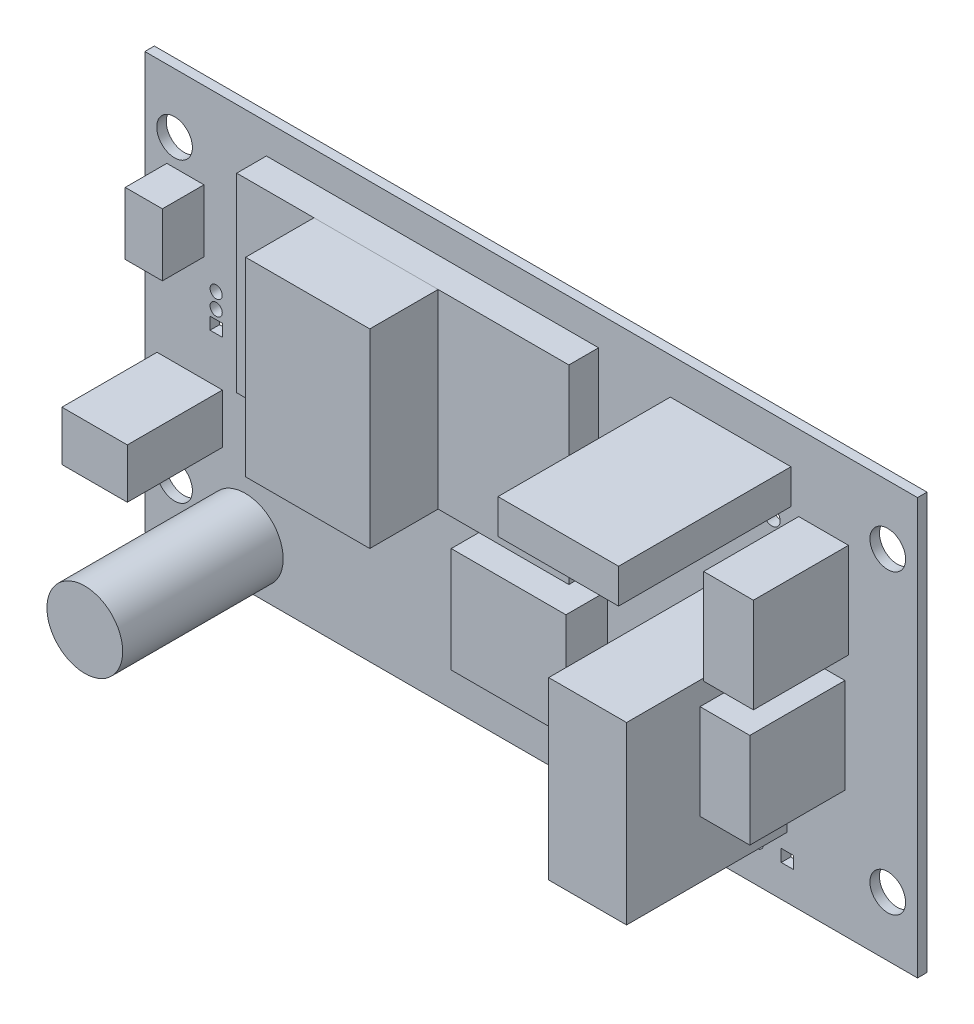
SolidWorks part; units mm, degrees
ref_plane "Front Plane" through (0, 0, 0) normal (0, 0, 1) x (1, 0, 0)
ref_plane "Top Plane" through (0, 0, 0) normal (0, 1, 0) x (1, 0, 0)
ref_plane "Right Plane" through (0, 0, 0) normal (1, 0, 0) x (0, 0, -1)
sketch "Model" plane through (0, 0, 0) normal (0, 0, 1) x (1, 0, 0)
  line L0 (110.225, 36.275) -> (116.975, 36.275)
  line L1 (116.975, 36.275) -> (116.975, 29.525)
  line L2 (116.975, 29.525) -> (110.225, 29.525)
  line L3 (110.225, 29.525) -> (110.225, 36.275)
  line L4 (110.825, 56.275) -> (117.575, 56.275)
  line L5 (117.575, 56.275) -> (117.575, 49.525)
  line L6 (117.575, 49.525) -> (110.825, 49.525)
  line L7 (110.825, 49.525) -> (110.825, 56.275)
  line L8 (91.975, 7.425) -> (94.025, 7.425)
  line L9 (94.025, 7.425) -> (94.025, 5.375)
  line L10 (94.025, 5.375) -> (91.975, 5.375)
  line L11 (91.975, 5.375) -> (91.975, 7.425)
  line L12 (107.075, 7.425) -> (109.125, 7.425)
  line L13 (109.125, 7.425) -> (109.125, 5.375)
  line L14 (109.125, 5.375) -> (107.075, 5.375)
  line L15 (107.075, 5.375) -> (107.075, 7.425)
  line L16 (41.75, 21.225) -> (41.75, 22.375) construction
  line L17 (41.75, 22.375) -> (44.45, 22.375) construction
  line L18 (44.45, 22.375) -> (44.45, 21.225) construction
  line L19 (44.45, 21.225) -> (41.75, 21.225) construction
  line L20 (41.75, 18.225) -> (41.75, 19.375) construction
  line L21 (41.75, 19.375) -> (44.45, 19.375) construction
  line L22 (44.45, 19.375) -> (44.45, 18.225) construction
  line L23 (44.45, 18.225) -> (41.75, 18.225) construction
  line L24 (83.15, 21.15) -> (84.45, 21.15) construction
  line L25 (84.45, 21.15) -> (84.45, 19.85) construction
  line L26 (84.45, 19.85) -> (83.15, 19.85) construction
  line L27 (83.15, 19.85) -> (83.15, 21.15) construction
  line L28 (83.15, 31.95) -> (84.45, 31.95) construction
  line L29 (84.45, 31.95) -> (84.45, 30.65) construction
  line L30 (84.45, 30.65) -> (83.15, 30.65) construction
  line L31 (83.15, 30.65) -> (83.15, 31.95) construction
  line L32 (97, 36.27) -> (97, 38.17)
  line L33 (97, 38.17) -> (98.9, 38.17)
  line L34 (98.9, 38.17) -> (98.9, 36.27)
  line L35 (98.9, 36.27) -> (97, 36.27)
  line L36 (49.335, 9.4) -> (48.385, 9.4) construction
  line L37 (48.385, 9.4) -> (48.385, 14.9) construction
  line L38 (48.385, 14.9) -> (49.335, 14.9) construction
  line L39 (49.335, 14.9) -> (49.335, 9.4) construction
  line L40 (54.415, 9.4) -> (53.465, 9.4) construction
  line L41 (53.465, 9.4) -> (53.465, 14.9) construction
  line L42 (53.465, 14.9) -> (54.415, 14.9) construction
  line L43 (54.415, 14.9) -> (54.415, 9.4) construction
  line L44 (56.6, 28.975) -> (56.6, 18.925) construction
  line L45 (56.6, 18.925) -> (46.2, 18.925) construction
  line L46 (46.2, 18.925) -> (46.2, 28.975) construction
  line L47 (46.2, 28.975) -> (56.6, 28.975) construction
  line L48 (76.7, 9.15) -> (76.7, 7.25) construction
  line L49 (76.7, 7.25) -> (71.9, 7.25) construction
  line L50 (71.9, 7.25) -> (71.9, 9.15) construction
  line L51 (71.9, 9.15) -> (76.7, 9.15) construction
  line L52 (63.5, 9.15) -> (63.5, 7.25) construction
  line L53 (63.5, 7.25) -> (58.7, 7.25) construction
  line L54 (58.7, 7.25) -> (58.7, 9.15) construction
  line L55 (58.7, 9.15) -> (63.5, 9.15) construction
  line L56 (62.075, 15.45) -> (58.825, 15.45) construction
  line L57 (58.825, 15.45) -> (58.825, 27.55) construction
  line L58 (58.825, 27.55) -> (62.075, 27.55) construction
  line L59 (62.075, 27.55) -> (62.075, 15.45) construction
  line L60 (77.575, 15.45) -> (74.325, 15.45) construction
  line L61 (74.325, 15.45) -> (74.325, 27.55) construction
  line L62 (74.325, 27.55) -> (77.575, 27.55) construction
  line L63 (77.575, 27.55) -> (77.575, 15.45) construction
  line L64 (28.075, 11.175) -> (26.925, 11.175) construction
  line L65 (26.925, 11.175) -> (26.925, 12.825) construction
  line L66 (26.925, 12.825) -> (28.075, 12.825) construction
  line L67 (28.075, 12.825) -> (28.075, 11.175) construction
  line L68 (31.075, 11.175) -> (29.925, 11.175) construction
  line L69 (29.925, 11.175) -> (29.925, 12.825) construction
  line L70 (29.925, 12.825) -> (31.075, 12.825) construction
  line L71 (31.075, 12.825) -> (31.075, 11.175) construction
  line L72 (91.475, 13.625) -> (91.475, 14.775) construction
  line L73 (91.475, 14.775) -> (93.125, 14.775) construction
  line L74 (93.125, 14.775) -> (93.125, 13.625) construction
  line L75 (93.125, 13.625) -> (91.475, 13.625) construction
  line L76 (91.475, 10.625) -> (91.475, 11.775) construction
  line L77 (91.475, 11.775) -> (93.125, 11.775) construction
  line L78 (93.125, 11.775) -> (93.125, 10.625) construction
  line L79 (93.125, 10.625) -> (91.475, 10.625) construction
  line L80 (91.475, 19.225) -> (91.475, 20.375) construction
  line L81 (91.475, 20.375) -> (93.125, 20.375) construction
  line L82 (93.125, 20.375) -> (93.125, 19.225) construction
  line L83 (93.125, 19.225) -> (91.475, 19.225) construction
  line L84 (91.475, 16.225) -> (91.475, 17.375) construction
  line L85 (91.475, 17.375) -> (93.125, 17.375) construction
  line L86 (93.125, 17.375) -> (93.125, 16.225) construction
  line L87 (93.125, 16.225) -> (91.475, 16.225) construction
  line L88 (91.475, 24.825) -> (91.475, 25.975) construction
  line L89 (91.475, 25.975) -> (93.125, 25.975) construction
  line L90 (93.125, 25.975) -> (93.125, 24.825) construction
  line L91 (93.125, 24.825) -> (91.475, 24.825) construction
  line L92 (91.475, 21.825) -> (91.475, 22.975) construction
  line L93 (91.475, 22.975) -> (93.125, 22.975) construction
  line L94 (93.125, 22.975) -> (93.125, 21.825) construction
  line L95 (93.125, 21.825) -> (91.475, 21.825) construction
  line L96 (91.475, 30.325) -> (91.475, 31.475) construction
  line L97 (91.475, 31.475) -> (93.125, 31.475) construction
  line L98 (93.125, 31.475) -> (93.125, 30.325) construction
  line L99 (93.125, 30.325) -> (91.475, 30.325) construction
  line L100 (91.475, 27.325) -> (91.475, 28.475) construction
  line L101 (91.475, 28.475) -> (93.125, 28.475) construction
  line L102 (93.125, 28.475) -> (93.125, 27.325) construction
  line L103 (93.125, 27.325) -> (91.475, 27.325) construction
  line L104 (23.375, 29.575) -> (22.225, 29.575) construction
  line L105 (22.225, 29.575) -> (22.225, 31.225) construction
  line L106 (22.225, 31.225) -> (23.375, 31.225) construction
  line L107 (23.375, 31.225) -> (23.375, 29.575) construction
  line L108 (26.375, 29.575) -> (25.225, 29.575) construction
  line L109 (25.225, 29.575) -> (25.225, 31.225) construction
  line L110 (25.225, 31.225) -> (26.375, 31.225) construction
  line L111 (26.375, 31.225) -> (26.375, 29.575) construction
  line L112 (97.54, 41.59) -> (97.54, 42.01) construction
  line L113 (97.54, 42.01) -> (98.38, 42.01) construction
  line L114 (98.38, 42.01) -> (98.38, 41.59) construction
  line L115 (98.38, 41.59) -> (97.54, 41.59) construction
  line L116 (99.82, 41.59) -> (99.82, 42.01) construction
  line L117 (99.82, 42.01) -> (100.66, 42.01) construction
  line L118 (100.66, 42.01) -> (100.66, 41.59) construction
  line L119 (100.66, 41.59) -> (99.82, 41.59) construction
  line L120 (20.21, 15.44) -> (19.79, 15.44) construction
  line L121 (19.79, 15.44) -> (19.79, 16.28) construction
  line L122 (19.79, 16.28) -> (20.21, 16.28) construction
  line L123 (20.21, 16.28) -> (20.21, 15.44) construction
  line L124 (20.21, 17.72) -> (19.79, 17.72) construction
  line L125 (19.79, 17.72) -> (19.79, 18.56) construction
  line L126 (19.79, 18.56) -> (20.21, 18.56) construction
  line L127 (20.21, 18.56) -> (20.21, 17.72) construction
  line L128 (26.225, 4.425) -> (26.225, 5.575) construction
  line L129 (26.225, 5.575) -> (27.375, 5.575) construction
  line L130 (27.375, 5.575) -> (27.375, 4.425) construction
  line L131 (27.375, 4.425) -> (26.225, 4.425) construction
  line L132 (18.675, 31.575) -> (18.675, 30.425) construction
  line L133 (18.675, 30.425) -> (17.525, 30.425) construction
  line L134 (17.525, 30.425) -> (17.525, 31.575) construction
  line L135 (17.525, 31.575) -> (18.675, 31.575) construction
  line L136 (13.75, 7.05) -> (13.75, 8.35) construction
  line L137 (13.75, 8.35) -> (15.05, 8.35) construction
  line L138 (15.05, 8.35) -> (15.05, 7.05) construction
  line L139 (15.05, 7.05) -> (13.75, 7.05) construction
  line L140 (106.9, 45.5) -> (106.9, 42.7)
  line L141 (106.9, 42.7) -> (104.1, 42.7)
  line L142 (104.1, 42.7) -> (104.1, 45.5)
  line L143 (104.1, 45.5) -> (106.9, 45.5)
  line L144 (5.55, 26.25) -> (8.05, 26.25)
  line L145 (8.05, 26.25) -> (8.05, 23.75)
  line L146 (8.05, 23.75) -> (5.55, 23.75)
  line L147 (5.55, 23.75) -> (5.55, 26.25)
  line L148 (94.45, 59.45) -> (91.75, 59.45)
  line L149 (91.75, 59.45) -> (91.75, 62.15)
  line L150 (91.75, 62.15) -> (94.45, 62.15)
  line L151 (94.45, 62.15) -> (94.45, 59.45)
  line L152 (84.25, 36.775) -> (84.25, 35.225) construction
  line L153 (84.25, 35.225) -> (82.05, 35.225) construction
  line L154 (82.05, 35.225) -> (82.05, 36.775) construction
  line L155 (82.05, 36.775) -> (84.25, 36.775) construction
  line L156 (80.15, 36.775) -> (80.15, 35.225) construction
  line L157 (80.15, 35.225) -> (77.95, 35.225) construction
  line L158 (77.95, 35.225) -> (77.95, 36.775) construction
  line L159 (77.95, 36.775) -> (80.15, 36.775) construction
  line L160 (86.15, 64.475) -> (86.15, 62.925) construction
  line L161 (86.15, 62.925) -> (83.95, 62.925) construction
  line L162 (83.95, 62.925) -> (83.95, 64.475) construction
  line L163 (83.95, 64.475) -> (86.15, 64.475) construction
  line L164 (82.05, 64.475) -> (82.05, 62.925) construction
  line L165 (82.05, 62.925) -> (79.85, 62.925) construction
  line L166 (79.85, 62.925) -> (79.85, 64.475) construction
  line L167 (79.85, 64.475) -> (82.05, 64.475) construction
  line L168 (86.15, 60.875) -> (86.15, 59.325) construction
  line L169 (86.15, 59.325) -> (83.95, 59.325) construction
  line L170 (83.95, 59.325) -> (83.95, 60.875) construction
  line L171 (83.95, 60.875) -> (86.15, 60.875) construction
  line L172 (82.05, 60.875) -> (82.05, 59.325) construction
  line L173 (82.05, 59.325) -> (79.85, 59.325) construction
  line L174 (79.85, 59.325) -> (79.85, 60.875) construction
  line L175 (79.85, 60.875) -> (82.05, 60.875) construction
  line L176 (85.725, 50.175) -> (86.675, 50.175) construction
  line L177 (86.675, 50.175) -> (86.675, 48.825) construction
  line L178 (86.675, 48.825) -> (85.725, 48.825) construction
  line L179 (85.725, 48.825) -> (85.725, 50.175) construction
  line L180 (84.125, 50.175) -> (85.075, 50.175) construction
  line L181 (85.075, 50.175) -> (85.075, 48.825) construction
  line L182 (85.075, 48.825) -> (84.125, 48.825) construction
  line L183 (84.125, 48.825) -> (84.125, 50.175) construction
  line L184 (84.125, 46.975) -> (85.075, 46.975) construction
  line L185 (85.075, 46.975) -> (85.075, 45.625) construction
  line L186 (85.075, 45.625) -> (84.125, 45.625) construction
  line L187 (84.125, 45.625) -> (84.125, 46.975) construction
  line L188 (82.525, 46.975) -> (83.475, 46.975) construction
  line L189 (83.475, 46.975) -> (83.475, 45.625) construction
  line L190 (83.475, 45.625) -> (82.525, 45.625) construction
  line L191 (82.525, 45.625) -> (82.525, 46.975) construction
  line L192 (84.125, 53.475) -> (85.075, 53.475) construction
  line L193 (85.075, 53.475) -> (85.075, 52.125) construction
  line L194 (85.075, 52.125) -> (84.125, 52.125) construction
  line L195 (84.125, 52.125) -> (84.125, 53.475) construction
  line L196 (82.525, 53.475) -> (83.475, 53.475) construction
  line L197 (83.475, 53.475) -> (83.475, 52.125) construction
  line L198 (83.475, 52.125) -> (82.525, 52.125) construction
  line L199 (82.525, 52.125) -> (82.525, 53.475) construction
  line L200 (86.625, 40.875) -> (87.575, 40.875) construction
  line L201 (87.575, 40.875) -> (87.575, 39.525) construction
  line L202 (87.575, 39.525) -> (86.625, 39.525) construction
  line L203 (86.625, 39.525) -> (86.625, 40.875) construction
  line L204 (85.025, 40.875) -> (85.975, 40.875) construction
  line L205 (85.975, 40.875) -> (85.975, 39.525) construction
  line L206 (85.975, 39.525) -> (85.025, 39.525) construction
  line L207 (85.025, 39.525) -> (85.025, 40.875) construction
  line L208 (78.575, 56.375) -> (78.575, 55.425) construction
  line L209 (78.575, 55.425) -> (77.225, 55.425) construction
  line L210 (77.225, 55.425) -> (77.225, 56.375) construction
  line L211 (77.225, 56.375) -> (78.575, 56.375) construction
  line L212 (78.575, 57.975) -> (78.575, 57.025) construction
  line L213 (78.575, 57.025) -> (77.225, 57.025) construction
  line L214 (77.225, 57.025) -> (77.225, 57.975) construction
  line L215 (77.225, 57.975) -> (78.575, 57.975) construction
  line L216 (29.075, 29.375) -> (29.625, 29.375) construction
  line L217 (29.625, 29.375) -> (29.625, 28.525) construction
  line L218 (29.625, 28.525) -> (29.075, 28.525) construction
  line L219 (29.075, 28.525) -> (29.075, 29.375) construction
  line L220 (27.775, 29.375) -> (28.325, 29.375) construction
  line L221 (28.325, 29.375) -> (28.325, 28.525) construction
  line L222 (28.325, 28.525) -> (27.775, 28.525) construction
  line L223 (27.775, 28.525) -> (27.775, 29.375) construction
  line L224 (28.425, 27.275) -> (28.975, 27.275) construction
  line L225 (28.975, 27.275) -> (28.975, 26.425) construction
  line L226 (28.975, 26.425) -> (28.425, 26.425) construction
  line L227 (28.425, 26.425) -> (28.425, 27.275) construction
  line L228 (13.975, 54.675) -> (14.525, 54.675) construction
  line L229 (14.525, 54.675) -> (14.525, 53.825) construction
  line L230 (14.525, 53.825) -> (13.975, 53.825) construction
  line L231 (13.975, 53.825) -> (13.975, 54.675) construction
  line L232 (12.675, 54.675) -> (13.225, 54.675) construction
  line L233 (13.225, 54.675) -> (13.225, 53.825) construction
  line L234 (13.225, 53.825) -> (12.675, 53.825) construction
  line L235 (12.675, 53.825) -> (12.675, 54.675) construction
  line L236 (13.325, 52.575) -> (13.875, 52.575) construction
  line L237 (13.875, 52.575) -> (13.875, 51.725) construction
  line L238 (13.875, 51.725) -> (13.325, 51.725) construction
  line L239 (13.325, 51.725) -> (13.325, 52.575) construction
  line L240 (35.875, 18.4) -> (34.925, 18.4) construction
  line L241 (34.925, 18.4) -> (34.925, 19.4) construction
  line L242 (34.925, 19.4) -> (35.875, 19.4) construction
  line L243 (35.875, 19.4) -> (35.875, 18.4) construction
  line L244 (37.475, 18.4) -> (36.525, 18.4) construction
  line L245 (36.525, 18.4) -> (36.525, 19.4) construction
  line L246 (36.525, 19.4) -> (37.475, 19.4) construction
  line L247 (37.475, 19.4) -> (37.475, 18.4) construction
  line L248 (24.675, 11.8) -> (23.725, 11.8) construction
  line L249 (23.725, 11.8) -> (23.725, 12.8) construction
  line L250 (23.725, 12.8) -> (24.675, 12.8) construction
  line L251 (24.675, 12.8) -> (24.675, 11.8) construction
  line L252 (26.275, 11.8) -> (25.325, 11.8) construction
  line L253 (25.325, 11.8) -> (25.325, 12.8) construction
  line L254 (25.325, 12.8) -> (26.275, 12.8) construction
  line L255 (26.275, 12.8) -> (26.275, 11.8) construction
  line L256 (18.5, 52.975) -> (18.5, 52.025) construction
  line L257 (18.5, 52.025) -> (17.5, 52.025) construction
  line L258 (17.5, 52.025) -> (17.5, 52.975) construction
  line L259 (17.5, 52.975) -> (18.5, 52.975) construction
  line L260 (18.5, 54.575) -> (18.5, 53.625) construction
  line L261 (18.5, 53.625) -> (17.5, 53.625) construction
  line L262 (17.5, 53.625) -> (17.5, 54.575) construction
  line L263 (17.5, 54.575) -> (18.5, 54.575) construction
  line L264 (15.8, 53.625) -> (15.8, 54.575) construction
  line L265 (15.8, 54.575) -> (16.8, 54.575) construction
  line L266 (16.8, 54.575) -> (16.8, 53.625) construction
  line L267 (16.8, 53.625) -> (15.8, 53.625) construction
  line L268 (15.8, 52.025) -> (15.8, 52.975) construction
  line L269 (15.8, 52.975) -> (16.8, 52.975) construction
  line L270 (16.8, 52.975) -> (16.8, 52.025) construction
  line L271 (16.8, 52.025) -> (15.8, 52.025) construction
  line L272 (34.9, 22.725) -> (34.9, 23.675) construction
  line L273 (34.9, 23.675) -> (35.9, 23.675) construction
  line L274 (35.9, 23.675) -> (35.9, 22.725) construction
  line L275 (35.9, 22.725) -> (34.9, 22.725) construction
  line L276 (34.9, 21.125) -> (34.9, 22.075) construction
  line L277 (34.9, 22.075) -> (35.9, 22.075) construction
  line L278 (35.9, 22.075) -> (35.9, 21.125) construction
  line L279 (35.9, 21.125) -> (34.9, 21.125) construction
  line L280 (33.225, 27.3) -> (34.175, 27.3) construction
  line L281 (34.175, 27.3) -> (34.175, 26.3) construction
  line L282 (34.175, 26.3) -> (33.225, 26.3) construction
  line L283 (33.225, 26.3) -> (33.225, 27.3) construction
  line L284 (31.625, 27.3) -> (32.575, 27.3) construction
  line L285 (32.575, 27.3) -> (32.575, 26.3) construction
  line L286 (32.575, 26.3) -> (31.625, 26.3) construction
  line L287 (31.625, 26.3) -> (31.625, 27.3) construction
  line L288 (30.425, 22.4) -> (31.375, 22.4) construction
  line L289 (31.375, 22.4) -> (31.375, 21.4) construction
  line L290 (31.375, 21.4) -> (30.425, 21.4) construction
  line L291 (30.425, 21.4) -> (30.425, 22.4) construction
  line L292 (28.825, 22.4) -> (29.775, 22.4) construction
  line L293 (29.775, 22.4) -> (29.775, 21.4) construction
  line L294 (29.775, 21.4) -> (28.825, 21.4) construction
  line L295 (28.825, 21.4) -> (28.825, 22.4) construction
  line L296 (21.3, 20.025) -> (21.3, 20.975) construction
  line L297 (21.3, 20.975) -> (22.3, 20.975) construction
  line L298 (22.3, 20.975) -> (22.3, 20.025) construction
  line L299 (22.3, 20.025) -> (21.3, 20.025) construction
  line L300 (21.3, 18.425) -> (21.3, 19.375) construction
  line L301 (21.3, 19.375) -> (22.3, 19.375) construction
  line L302 (22.3, 19.375) -> (22.3, 18.425) construction
  line L303 (22.3, 18.425) -> (21.3, 18.425) construction
  line L304 (38.4, 16.125) -> (38.4, 17.075) construction
  line L305 (38.4, 17.075) -> (39.4, 17.075) construction
  line L306 (39.4, 17.075) -> (39.4, 16.125) construction
  line L307 (39.4, 16.125) -> (38.4, 16.125) construction
  line L308 (38.4, 14.525) -> (38.4, 15.475) construction
  line L309 (38.4, 15.475) -> (39.4, 15.475) construction
  line L310 (39.4, 15.475) -> (39.4, 14.525) construction
  line L311 (39.4, 14.525) -> (38.4, 14.525) construction
  line L312 (19.625, 23.3) -> (20.575, 23.3) construction
  line L313 (20.575, 23.3) -> (20.575, 22.3) construction
  line L314 (20.575, 22.3) -> (19.625, 22.3) construction
  line L315 (19.625, 22.3) -> (19.625, 23.3) construction
  line L316 (18.025, 23.3) -> (18.975, 23.3) construction
  line L317 (18.975, 23.3) -> (18.975, 22.3) construction
  line L318 (18.975, 22.3) -> (18.025, 22.3) construction
  line L319 (18.025, 22.3) -> (18.025, 23.3) construction
  line L320 (37.2, 15.475) -> (37.2, 14.525) construction
  line L321 (37.2, 14.525) -> (36.2, 14.525) construction
  line L322 (36.2, 14.525) -> (36.2, 15.475) construction
  line L323 (36.2, 15.475) -> (37.2, 15.475) construction
  line L324 (37.2, 17.075) -> (37.2, 16.125) construction
  line L325 (37.2, 16.125) -> (36.2, 16.125) construction
  line L326 (36.2, 16.125) -> (36.2, 17.075) construction
  line L327 (36.2, 17.075) -> (37.2, 17.075) construction
  line L328 (78.775, 7.7) -> (77.825, 7.7) construction
  line L329 (77.825, 7.7) -> (77.825, 8.7) construction
  line L330 (77.825, 8.7) -> (78.775, 8.7) construction
  line L331 (78.775, 8.7) -> (78.775, 7.7) construction
  line L332 (80.375, 7.7) -> (79.425, 7.7) construction
  line L333 (79.425, 7.7) -> (79.425, 8.7) construction
  line L334 (79.425, 8.7) -> (80.375, 8.7) construction
  line L335 (80.375, 8.7) -> (80.375, 7.7) construction
  line L336 (17.525, 35.2) -> (18.475, 35.2) construction
  line L337 (18.475, 35.2) -> (18.475, 34.2) construction
  line L338 (18.475, 34.2) -> (17.525, 34.2) construction
  line L339 (17.525, 34.2) -> (17.525, 35.2) construction
  line L340 (15.925, 35.2) -> (16.875, 35.2) construction
  line L341 (16.875, 35.2) -> (16.875, 34.2) construction
  line L342 (16.875, 34.2) -> (15.925, 34.2) construction
  line L343 (15.925, 34.2) -> (15.925, 35.2) construction
  line L344 (15, 22.675) -> (15, 21.725) construction
  line L345 (15, 21.725) -> (14, 21.725) construction
  line L346 (14, 21.725) -> (14, 22.675) construction
  line L347 (14, 22.675) -> (15, 22.675) construction
  line L348 (15, 24.275) -> (15, 23.325) construction
  line L349 (15, 23.325) -> (14, 23.325) construction
  line L350 (14, 23.325) -> (14, 24.275) construction
  line L351 (14, 24.275) -> (15, 24.275) construction
  line L352 (2.8, 49.875) -> (2.8, 48.925) construction
  line L353 (2.8, 48.925) -> (1.8, 48.925) construction
  line L354 (1.8, 48.925) -> (1.8, 49.875) construction
  line L355 (1.8, 49.875) -> (2.8, 49.875) construction
  line L356 (2.8, 51.475) -> (2.8, 50.525) construction
  line L357 (2.8, 50.525) -> (1.8, 50.525) construction
  line L358 (1.8, 50.525) -> (1.8, 51.475) construction
  line L359 (1.8, 51.475) -> (2.8, 51.475) construction
  line L360 (12.175, 47.3) -> (11.225, 47.3) construction
  line L361 (11.225, 47.3) -> (11.225, 48.3) construction
  line L362 (11.225, 48.3) -> (12.175, 48.3) construction
  line L363 (12.175, 48.3) -> (12.175, 47.3) construction
  line L364 (13.775, 47.3) -> (12.825, 47.3) construction
  line L365 (12.825, 47.3) -> (12.825, 48.3) construction
  line L366 (12.825, 48.3) -> (13.775, 48.3) construction
  line L367 (13.775, 48.3) -> (13.775, 47.3) construction
  line L368 (7, 47.1) -> (5.6, 47.1)
  line L369 (5.6, 47.1) -> (5.6, 48.5)
  line L370 (5.6, 48.5) -> (7, 48.5)
  line L371 (7, 48.5) -> (7, 47.1)
  line L372 (20.705, 61.945) -> (20.705, 63.995)
  line L373 (20.705, 63.995) -> (22.755, 63.995)
  line L374 (22.755, 63.995) -> (22.755, 61.945)
  line L375 (22.755, 61.945) -> (20.705, 61.945)
  line L376 (13.025, 36.925) -> (13.025, 34.875)
  line L377 (13.025, 34.875) -> (10.975, 34.875)
  line L378 (10.975, 34.875) -> (10.975, 36.925)
  line L379 (10.975, 36.925) -> (13.025, 36.925)
  line L380 (32.3, 15.895) -> (33.3, 15.895) construction
  line L381 (33.3, 15.295) -> (32.3, 15.295) construction
  line L382 (32.3, 17.165) -> (33.3, 17.165) construction
  line L383 (33.3, 16.565) -> (32.3, 16.565) construction
  line L384 (32.3, 18.435) -> (33.3, 18.435) construction
  line L385 (33.3, 17.835) -> (32.3, 17.835) construction
  line L386 (32.3, 19.705) -> (33.3, 19.705) construction
  line L387 (33.3, 19.105) -> (32.3, 19.105) construction
  line L388 (25.1, 19.705) -> (26.1, 19.705) construction
  line L389 (26.1, 19.105) -> (25.1, 19.105) construction
  line L390 (25.1, 18.435) -> (26.1, 18.435) construction
  line L391 (26.1, 17.835) -> (25.1, 17.835) construction
  line L392 (25.1, 17.165) -> (26.1, 17.165) construction
  line L393 (26.1, 16.565) -> (25.1, 16.565) construction
  line L394 (25.1, 15.895) -> (26.1, 15.895) construction
  line L395 (26.1, 15.295) -> (25.1, 15.295) construction
  line L396 (0, 0) -> (0, 70)
  line L397 (0, 70) -> (130, 70)
  line L398 (130, 70) -> (130, 0)
  line L399 (130, 0) -> (0, 0)
  circle A0 centre (5, 60) radius 3
  circle A1 centre (125, 60) radius 3
  circle A2 centre (125, 10) radius 3
  circle A3 centre (5, 10) radius 3
  circle A4 centre (113.6, 25.6) radius 3.375
  circle A5 centre (114.2, 45.6) radius 3.375
  circle A6 centre (87.92, 6.4) radius 1.025
  circle A7 centre (103.02, 6.4) radius 1.025
  circle A8 centre (83.8, 15.5) radius 0.65 construction
  circle A9 centre (83.8, 26.3) radius 0.65 construction
  circle A10 centre (97.95, 22.22) radius 0.95
  circle A11 centre (97.95, 17.22) radius 0.95
  circle A12 centre (97.95, 12.22) radius 0.95
  circle A13 centre (105.45, 12.22) radius 0.95
  circle A14 centre (105.45, 17.22) radius 0.95
  circle A15 centre (105.45, 22.22) radius 0.95
  circle A16 centre (105.45, 37.22) radius 0.95
  circle A17 centre (28.8, 5) radius 0.575 construction
  circle A18 centre (16.1, 31) radius 0.575 construction
  circle A19 centre (19.4, 7.7) radius 0.65 construction
  circle A20 centre (105.5, 55.02) radius 1.4
  circle A21 centre (6.8, 21.04) radius 1.25
  circle A22 centre (98.561, 60.8) radius 1.35
  circle A23 centre (104.022, 60.8) radius 1.35
  circle A24 centre (6.3, 50.3) radius 0.7
  circle A25 centre (6.3, 52.8) radius 0.7
  circle A26 centre (21.73, 60.43) radius 1.025
  circle A27 centre (21.73, 57.89) radius 1.025
  circle A28 centre (21.73, 55.35) radius 1.025
  circle A29 centre (21.73, 52.81) radius 1.025
  circle A30 centre (21.73, 50.27) radius 1.025
  circle A31 centre (21.73, 47.73) radius 1.025
  circle A32 centre (21.73, 45.19) radius 1.025
  circle A33 centre (21.73, 42.65) radius 1.025
  circle A34 centre (21.73, 40.11) radius 1.025
  circle A35 centre (21.73, 37.57) radius 1.025
  circle A36 centre (21.73, 35.03) radius 1.025
  circle A37 centre (75.07, 37.57) radius 1.025
  circle A38 centre (75.07, 40.11) radius 1.025
  circle A39 centre (75.07, 42.65) radius 1.025
  circle A40 centre (75.07, 45.19) radius 1.025
  circle A41 centre (75.07, 52.81) radius 1.025
  circle A42 centre (75.07, 55.35) radius 1.025
  circle A43 centre (75.07, 57.89) radius 1.025
  circle A44 centre (75.07, 60.43) radius 1.025
  circle A45 centre (12, 38.44) radius 1.025
  circle A46 centre (12, 40.98) radius 1.025
  circle A47 centre (23.8, 23.23) radius 0.725 construction
  circle A48 centre (25.07, 24.5) radius 0.725 construction
  circle A49 centre (23.8, 25.77) radius 0.725 construction
  arc A50 (33.3, 15.295) -> (33.3, 15.895) centre (33.3, 15.595) ccw construction
  arc A51 (32.3, 15.895) -> (32.3, 15.295) centre (32.3, 15.595) ccw construction
  arc A52 (33.3, 16.565) -> (33.3, 17.165) centre (33.3, 16.865) ccw construction
  arc A53 (32.3, 17.165) -> (32.3, 16.565) centre (32.3, 16.865) ccw construction
  arc A54 (33.3, 17.835) -> (33.3, 18.435) centre (33.3, 18.135) ccw construction
  arc A55 (32.3, 18.435) -> (32.3, 17.835) centre (32.3, 18.135) ccw construction
  arc A56 (33.3, 19.105) -> (33.3, 19.705) centre (33.3, 19.405) ccw construction
  arc A57 (32.3, 19.705) -> (32.3, 19.105) centre (32.3, 19.405) ccw construction
  arc A58 (26.1, 19.105) -> (26.1, 19.705) centre (26.1, 19.405) ccw construction
  arc A59 (25.1, 19.705) -> (25.1, 19.105) centre (25.1, 19.405) ccw construction
  arc A60 (26.1, 17.835) -> (26.1, 18.435) centre (26.1, 18.135) ccw construction
  arc A61 (25.1, 18.435) -> (25.1, 17.835) centre (25.1, 18.135) ccw construction
  arc A62 (26.1, 16.565) -> (26.1, 17.165) centre (26.1, 16.865) ccw construction
  arc A63 (25.1, 17.165) -> (25.1, 16.565) centre (25.1, 16.865) ccw construction
  arc A64 (26.1, 15.295) -> (26.1, 15.895) centre (26.1, 15.595) ccw construction
  arc A65 (25.1, 15.895) -> (25.1, 15.295) centre (25.1, 15.595) ccw construction
extrude "Boss-Extrude1" add sketch "Model" along normal blind 1.6
sketch "Sketch3" plane through (0, 0, 1.6) normal (0, 0, 1) x (1, 0, 0)
  line L0 (5, 59.5) -> (5, 60.5) construction
  line L1 (4.5, 60) -> (5.5, 60) construction
  line L2 (1.5, 56.5) -> (1.5, 63.5) construction
  line L3 (1.5, 63.5) -> (8.5, 63.5) construction
  line L4 (8.5, 63.5) -> (8.5, 56.5) construction
  line L5 (8.5, 56.5) -> (1.5, 56.5) construction
  line L6 (125, 59.5) -> (125, 60.5) construction
  line L7 (124.5, 60) -> (125.5, 60) construction
  line L8 (121.5, 56.5) -> (121.5, 63.5) construction
  line L9 (121.5, 63.5) -> (128.5, 63.5) construction
  line L10 (128.5, 63.5) -> (128.5, 56.5) construction
  line L11 (128.5, 56.5) -> (121.5, 56.5) construction
  line L12 (125, 9.5) -> (125, 10.5) construction
  line L13 (124.5, 10) -> (125.5, 10) construction
  line L14 (121.5, 6.5) -> (121.5, 13.5) construction
  line L15 (121.5, 13.5) -> (128.5, 13.5) construction
  line L16 (128.5, 13.5) -> (128.5, 6.5) construction
  line L17 (128.5, 6.5) -> (121.5, 6.5) construction
  line L18 (5, 9.5) -> (5, 10.5) construction
  line L19 (4.5, 10) -> (5.5, 10) construction
  line L20 (1.5, 6.5) -> (1.5, 13.5) construction
  line L21 (1.5, 13.5) -> (8.5, 13.5) construction
  line L22 (8.5, 13.5) -> (8.5, 6.5) construction
  line L23 (8.5, 6.5) -> (1.5, 6.5) construction
  line L24 (113.1, 32.9) -> (114.1, 32.9) construction
  line L25 (113.6, 33.4) -> (113.6, 32.4) construction
  line L26 (109.411, 37.2425) -> (117.789, 37.2425) construction
  line L27 (117.789, 37.2425) -> (117.789, 21.2575) construction
  line L28 (117.789, 21.2575) -> (109.411, 21.2575) construction
  line L29 (109.411, 21.2575) -> (109.411, 37.2425) construction
  line L30 (113.7, 52.9) -> (114.7, 52.9) construction
  line L31 (114.2, 53.4) -> (114.2, 52.4) construction
  line L32 (110.011, 57.2425) -> (118.389, 57.2425) construction
  line L33 (118.389, 57.2425) -> (118.389, 41.2575) construction
  line L34 (118.389, 41.2575) -> (110.011, 41.2575) construction
  line L35 (110.011, 41.2575) -> (110.011, 57.2425) construction
  line L36 (92.5, 6.4) -> (93.5, 6.4) construction
  line L37 (93, 6.9) -> (93, 5.9) construction
  line L38 (85.16, 8.65) -> (95.76, 8.65) construction
  line L39 (95.76, 8.65) -> (95.76, 3.65) construction
  line L40 (95.76, 3.65) -> (85.16, 3.65) construction
  line L41 (85.16, 3.65) -> (85.16, 8.65) construction
  line L42 (107.6, 6.4) -> (108.6, 6.4) construction
  line L43 (108.1, 6.9) -> (108.1, 5.9) construction
  line L44 (100.26, 8.65) -> (110.86, 8.65) construction
  line L45 (110.86, 8.65) -> (110.86, 3.65) construction
  line L46 (110.86, 3.65) -> (100.26, 3.65) construction
  line L47 (100.26, 3.65) -> (100.26, 8.65) construction
  line L48 (42.6, 20.3) -> (43.6, 20.3) construction
  line L49 (43.1, 20.8) -> (43.1, 19.8) construction
  line L50 (41.5, 22.65) -> (44.7, 22.65) construction
  line L51 (44.7, 22.65) -> (44.7, 17.95) construction
  line L52 (44.7, 17.95) -> (41.5, 17.95) construction
  line L53 (41.5, 17.95) -> (41.5, 22.65) construction
  line L54 (83.3, 18) -> (84.3, 18) construction
  line L55 (83.8, 18.5) -> (83.8, 17.5) construction
  line L56 (83.3, 28.8) -> (84.3, 28.8) construction
  line L57 (83.8, 29.3) -> (83.8, 28.3) construction
  line L58 (101.5, 24.5) -> (101.5, 25.5) construction
  line L59 (101, 25) -> (102, 25) construction
  line L60 (94.95, 10.25) -> (94.95, 39.75) construction
  line L61 (94.95, 39.75) -> (108.05, 39.75) construction
  line L62 (108.05, 39.75) -> (108.05, 10.25) construction
  line L63 (108.05, 10.25) -> (94.95, 10.25) construction
  line L64 (51.9, 19.2) -> (50.9, 19.2) construction
  line L65 (51.4, 18.7) -> (51.4, 19.7) construction
  line L66 (56.85, 9.15) -> (45.95, 9.15) construction
  line L67 (45.95, 9.15) -> (45.95, 29.25) construction
  line L68 (45.95, 29.25) -> (56.85, 29.25) construction
  line L69 (56.85, 29.25) -> (56.85, 9.15) construction
  line L70 (67.7, 8.7) -> (67.7, 7.7) construction
  line L71 (68.2, 8.2) -> (67.2, 8.2) construction
  line L72 (76.95, 12.25) -> (76.95, 4.15) construction
  line L73 (76.95, 4.15) -> (58.45, 4.15) construction
  line L74 (58.45, 4.15) -> (58.45, 12.25) construction
  line L75 (58.45, 12.25) -> (76.95, 12.25) construction
  line L76 (68.2, 21) -> (68.2, 22) construction
  line L77 (67.7, 21.5) -> (68.7, 21.5) construction
  line L78 (58.55, 12.65) -> (58.55, 30.35) construction
  line L79 (58.55, 30.35) -> (77.85, 30.35) construction
  line L80 (77.85, 30.35) -> (77.85, 12.65) construction
  line L81 (77.85, 12.65) -> (58.55, 12.65) construction
  line L82 (29, 11.5) -> (29, 12.5) construction
  line L83 (28.5, 12) -> (29.5, 12) construction
  line L84 (26.65, 10.9) -> (26.65, 13.1) construction
  line L85 (26.65, 13.1) -> (31.35, 13.1) construction
  line L86 (31.35, 13.1) -> (31.35, 10.9) construction
  line L87 (31.35, 10.9) -> (26.65, 10.9) construction
  line L88 (91.8, 12.7) -> (92.8, 12.7) construction
  line L89 (92.3, 13.2) -> (92.3, 12.2) construction
  line L90 (91.2, 15.05) -> (93.4, 15.05) construction
  line L91 (93.4, 15.05) -> (93.4, 10.35) construction
  line L92 (93.4, 10.35) -> (91.2, 10.35) construction
  line L93 (91.2, 10.35) -> (91.2, 15.05) construction
  line L94 (91.8, 18.3) -> (92.8, 18.3) construction
  line L95 (92.3, 18.8) -> (92.3, 17.8) construction
  line L96 (91.2, 20.65) -> (93.4, 20.65) construction
  line L97 (93.4, 20.65) -> (93.4, 15.95) construction
  line L98 (93.4, 15.95) -> (91.2, 15.95) construction
  line L99 (91.2, 15.95) -> (91.2, 20.65) construction
  line L100 (91.8, 23.9) -> (92.8, 23.9) construction
  line L101 (92.3, 24.4) -> (92.3, 23.4) construction
  line L102 (91.2, 26.25) -> (93.4, 26.25) construction
  line L103 (93.4, 26.25) -> (93.4, 21.55) construction
  line L104 (93.4, 21.55) -> (91.2, 21.55) construction
  line L105 (91.2, 21.55) -> (91.2, 26.25) construction
  line L106 (91.8, 29.4) -> (92.8, 29.4) construction
  line L107 (92.3, 29.9) -> (92.3, 28.9) construction
  line L108 (91.2, 31.75) -> (93.4, 31.75) construction
  line L109 (93.4, 31.75) -> (93.4, 27.05) construction
  line L110 (93.4, 27.05) -> (91.2, 27.05) construction
  line L111 (91.2, 27.05) -> (91.2, 31.75) construction
  line L112 (24.3, 29.9) -> (24.3, 30.9) construction
  line L113 (23.8, 30.4) -> (24.8, 30.4) construction
  line L114 (21.95, 29.3) -> (21.95, 31.5) construction
  line L115 (21.95, 31.5) -> (26.65, 31.5) construction
  line L116 (26.65, 31.5) -> (26.65, 29.3) construction
  line L117 (26.65, 29.3) -> (21.95, 29.3) construction
  line L118 (99.1, 41.3) -> (99.1, 42.3) construction
  line L119 (98.6, 41.8) -> (99.6, 41.8) construction
  line L120 (97.39, 40.97) -> (97.39, 42.63) construction
  line L121 (97.39, 42.63) -> (100.81, 42.63) construction
  line L122 (100.81, 42.63) -> (100.81, 40.97) construction
  line L123 (100.81, 40.97) -> (97.39, 40.97) construction
  line L124 (20.5, 17) -> (19.5, 17) construction
  line L125 (20, 16.5) -> (20, 17.5) construction
  line L126 (20.83, 15.29) -> (19.17, 15.29) construction
  line L127 (19.17, 15.29) -> (19.17, 18.71) construction
  line L128 (19.17, 18.71) -> (20.83, 18.71) construction
  line L129 (20.83, 18.71) -> (20.83, 15.29) construction
  line L130 (27.8, 4.5) -> (27.8, 5.5) construction
  line L131 (27.3, 5) -> (28.3, 5) construction
  line L132 (17.1, 31.5) -> (17.1, 30.5) construction
  line L133 (17.6, 31) -> (16.6, 31) construction
  line L134 (16.9, 7.2) -> (16.9, 8.2) construction
  line L135 (16.4, 7.7) -> (17.4, 7.7) construction
  line L136 (105.5, 44.6) -> (105.5, 43.6) construction
  line L137 (106, 44.1) -> (105, 44.1) construction
  line L138 (108.56, 57.6) -> (108.56, 41.52) construction
  line L139 (108.56, 41.52) -> (102.75, 41.52) construction
  line L140 (102.75, 41.52) -> (102.75, 57.6) construction
  line L141 (102.75, 57.6) -> (108.56, 57.6) construction
  line L142 (6.3, 25) -> (7.3, 25) construction
  line L143 (6.8, 25.5) -> (6.8, 24.5) construction
  line L144 (2.05, 27.2) -> (13.05, 27.2) construction
  line L145 (13.05, 27.2) -> (13.05, 18.84) construction
  line L146 (13.05, 18.84) -> (2.05, 18.84) construction
  line L147 (2.05, 18.84) -> (2.05, 27.2) construction
  line L148 (93.6, 60.8) -> (92.6, 60.8) construction
  line L149 (93.1, 60.3) -> (93.1, 61.3) construction
  line L150 (108.7085, 58.04) -> (88.4135, 58.04) construction
  line L151 (88.4135, 58.04) -> (88.4135, 63.85) construction
  line L152 (88.4135, 63.85) -> (108.7085, 63.85) construction
  line L153 (108.7085, 63.85) -> (108.7085, 58.04) construction
  line L154 (81.1, 36.5) -> (81.1, 35.5) construction
  line L155 (81.6, 36) -> (80.6, 36) construction
  line L156 (84.5, 37.65) -> (84.5, 34.35) construction
  line L157 (84.5, 34.35) -> (77.7, 34.35) construction
  line L158 (77.7, 34.35) -> (77.7, 37.65) construction
  line L159 (77.7, 37.65) -> (84.5, 37.65) construction
  line L160 (83, 64.2) -> (83, 63.2) construction
  line L161 (83.5, 63.7) -> (82.5, 63.7) construction
  line L162 (86.4, 65.35) -> (86.4, 62.05) construction
  line L163 (86.4, 62.05) -> (79.6, 62.05) construction
  line L164 (79.6, 62.05) -> (79.6, 65.35) construction
  line L165 (79.6, 65.35) -> (86.4, 65.35) construction
  line L166 (83, 60.6) -> (83, 59.6) construction
  line L167 (83.5, 60.1) -> (82.5, 60.1) construction
  line L168 (86.4, 61.75) -> (86.4, 58.45) construction
  line L169 (86.4, 58.45) -> (79.6, 58.45) construction
  line L170 (79.6, 58.45) -> (79.6, 61.75) construction
  line L171 (79.6, 61.75) -> (86.4, 61.75) construction
  line L172 (85.4, 50) -> (85.4, 49) construction
  line L173 (85.9, 49.5) -> (84.9, 49.5) construction
  line L174 (86.8, 50.35) -> (86.8, 48.65) construction
  line L175 (86.8, 48.65) -> (84, 48.65) construction
  line L176 (84, 48.65) -> (84, 50.35) construction
  line L177 (84, 50.35) -> (86.8, 50.35) construction
  line L178 (83.8, 46.8) -> (83.8, 45.8) construction
  line L179 (84.3, 46.3) -> (83.3, 46.3) construction
  line L180 (85.2, 47.15) -> (85.2, 45.45) construction
  line L181 (85.2, 45.45) -> (82.4, 45.45) construction
  line L182 (82.4, 45.45) -> (82.4, 47.15) construction
  line L183 (82.4, 47.15) -> (85.2, 47.15) construction
  line L184 (83.8, 53.3) -> (83.8, 52.3) construction
  line L185 (84.3, 52.8) -> (83.3, 52.8) construction
  line L186 (85.2, 53.65) -> (85.2, 51.95) construction
  line L187 (85.2, 51.95) -> (82.4, 51.95) construction
  line L188 (82.4, 51.95) -> (82.4, 53.65) construction
  line L189 (82.4, 53.65) -> (85.2, 53.65) construction
  line L190 (86.3, 40.7) -> (86.3, 39.7) construction
  line L191 (86.8, 40.2) -> (85.8, 40.2) construction
  line L192 (87.7, 41.05) -> (87.7, 39.35) construction
  line L193 (87.7, 39.35) -> (84.9, 39.35) construction
  line L194 (84.9, 39.35) -> (84.9, 41.05) construction
  line L195 (84.9, 41.05) -> (87.7, 41.05) construction
  line L196 (78.4, 56.7) -> (77.4, 56.7) construction
  line L197 (77.9, 56.2) -> (77.9, 57.2) construction
  line L198 (78.75, 55.3) -> (77.05, 55.3) construction
  line L199 (77.05, 55.3) -> (77.05, 58.1) construction
  line L200 (77.05, 58.1) -> (78.75, 58.1) construction
  line L201 (78.75, 58.1) -> (78.75, 55.3) construction
  line L202 (28.2, 27.9) -> (29.2, 27.9) construction
  line L203 (28.7, 28.4) -> (28.7, 27.4) construction
  line L204 (27.4, 29.65) -> (30, 29.65) construction
  line L205 (30, 29.65) -> (30, 26.15) construction
  line L206 (30, 26.15) -> (27.4, 26.15) construction
  line L207 (27.4, 26.15) -> (27.4, 29.65) construction
  line L208 (13.1, 53.2) -> (14.1, 53.2) construction
  line L209 (13.6, 53.7) -> (13.6, 52.7) construction
  line L210 (12.3, 54.95) -> (14.9, 54.95) construction
  line L211 (14.9, 54.95) -> (14.9, 51.45) construction
  line L212 (14.9, 51.45) -> (12.3, 51.45) construction
  line L213 (12.3, 51.45) -> (12.3, 54.95) construction
  line L214 (36.2, 18.4) -> (36.2, 19.4) construction
  line L215 (35.7, 18.9) -> (36.7, 18.9) construction
  line L216 (34.65, 18.15) -> (34.65, 19.65) construction
  line L217 (34.65, 19.65) -> (37.75, 19.65) construction
  line L218 (37.75, 19.65) -> (37.75, 18.15) construction
  line L219 (37.75, 18.15) -> (34.65, 18.15) construction
  line L220 (25, 11.8) -> (25, 12.8) construction
  line L221 (24.5, 12.3) -> (25.5, 12.3) construction
  line L222 (23.45, 11.55) -> (23.45, 13.05) construction
  line L223 (23.45, 13.05) -> (26.55, 13.05) construction
  line L224 (26.55, 13.05) -> (26.55, 11.55) construction
  line L225 (26.55, 11.55) -> (23.45, 11.55) construction
  line L226 (18.5, 53.3) -> (17.5, 53.3) construction
  line L227 (18, 52.8) -> (18, 53.8) construction
  line L228 (18.75, 51.75) -> (17.25, 51.75) construction
  line L229 (17.25, 51.75) -> (17.25, 54.85) construction
  line L230 (17.25, 54.85) -> (18.75, 54.85) construction
  line L231 (18.75, 54.85) -> (18.75, 51.75) construction
  line L232 (15.8, 53.3) -> (16.8, 53.3) construction
  line L233 (16.3, 53.8) -> (16.3, 52.8) construction
  line L234 (15.55, 54.85) -> (17.05, 54.85) construction
  line L235 (17.05, 54.85) -> (17.05, 51.75) construction
  line L236 (17.05, 51.75) -> (15.55, 51.75) construction
  line L237 (15.55, 51.75) -> (15.55, 54.85) construction
  line L238 (34.9, 22.4) -> (35.9, 22.4) construction
  line L239 (35.4, 22.9) -> (35.4, 21.9) construction
  line L240 (34.65, 23.95) -> (36.15, 23.95) construction
  line L241 (36.15, 23.95) -> (36.15, 20.85) construction
  line L242 (36.15, 20.85) -> (34.65, 20.85) construction
  line L243 (34.65, 20.85) -> (34.65, 23.95) construction
  line L244 (32.9, 27.3) -> (32.9, 26.3) construction
  line L245 (33.4, 26.8) -> (32.4, 26.8) construction
  line L246 (34.45, 27.55) -> (34.45, 26.05) construction
  line L247 (34.45, 26.05) -> (31.35, 26.05) construction
  line L248 (31.35, 26.05) -> (31.35, 27.55) construction
  line L249 (31.35, 27.55) -> (34.45, 27.55) construction
  line L250 (30.1, 22.4) -> (30.1, 21.4) construction
  line L251 (30.6, 21.9) -> (29.6, 21.9) construction
  line L252 (31.65, 22.65) -> (31.65, 21.15) construction
  line L253 (31.65, 21.15) -> (28.55, 21.15) construction
  line L254 (28.55, 21.15) -> (28.55, 22.65) construction
  line L255 (28.55, 22.65) -> (31.65, 22.65) construction
  line L256 (21.3, 19.7) -> (22.3, 19.7) construction
  line L257 (21.8, 20.2) -> (21.8, 19.2) construction
  line L258 (21.05, 21.25) -> (22.55, 21.25) construction
  line L259 (22.55, 21.25) -> (22.55, 18.15) construction
  line L260 (22.55, 18.15) -> (21.05, 18.15) construction
  line L261 (21.05, 18.15) -> (21.05, 21.25) construction
  line L262 (38.4, 15.8) -> (39.4, 15.8) construction
  line L263 (38.9, 16.3) -> (38.9, 15.3) construction
  line L264 (38.15, 17.35) -> (39.65, 17.35) construction
  line L265 (39.65, 17.35) -> (39.65, 14.25) construction
  line L266 (39.65, 14.25) -> (38.15, 14.25) construction
  line L267 (38.15, 14.25) -> (38.15, 17.35) construction
  line L268 (19.3, 23.3) -> (19.3, 22.3) construction
  line L269 (19.8, 22.8) -> (18.8, 22.8) construction
  line L270 (20.85, 23.55) -> (20.85, 22.05) construction
  line L271 (20.85, 22.05) -> (17.75, 22.05) construction
  line L272 (17.75, 22.05) -> (17.75, 23.55) construction
  line L273 (17.75, 23.55) -> (20.85, 23.55) construction
  line L274 (37.2, 15.8) -> (36.2, 15.8) construction
  line L275 (36.7, 15.3) -> (36.7, 16.3) construction
  line L276 (37.45, 14.25) -> (35.95, 14.25) construction
  line L277 (35.95, 14.25) -> (35.95, 17.35) construction
  line L278 (35.95, 17.35) -> (37.45, 17.35) construction
  line L279 (37.45, 17.35) -> (37.45, 14.25) construction
  line L280 (79.1, 7.7) -> (79.1, 8.7) construction
  line L281 (78.6, 8.2) -> (79.6, 8.2) construction
  line L282 (77.55, 7.45) -> (77.55, 8.95) construction
  line L283 (77.55, 8.95) -> (80.65, 8.95) construction
  line L284 (80.65, 8.95) -> (80.65, 7.45) construction
  line L285 (80.65, 7.45) -> (77.55, 7.45) construction
  line L286 (17.2, 35.2) -> (17.2, 34.2) construction
  line L287 (17.7, 34.7) -> (16.7, 34.7) construction
  line L288 (18.75, 35.45) -> (18.75, 33.95) construction
  line L289 (18.75, 33.95) -> (15.65, 33.95) construction
  line L290 (15.65, 33.95) -> (15.65, 35.45) construction
  line L291 (15.65, 35.45) -> (18.75, 35.45) construction
  line L292 (15, 23) -> (14, 23) construction
  line L293 (14.5, 22.5) -> (14.5, 23.5) construction
  line L294 (15.25, 21.45) -> (13.75, 21.45) construction
  line L295 (13.75, 21.45) -> (13.75, 24.55) construction
  line L296 (13.75, 24.55) -> (15.25, 24.55) construction
  line L297 (15.25, 24.55) -> (15.25, 21.45) construction
  line L298 (2.8, 50.2) -> (1.8, 50.2) construction
  line L299 (2.3, 49.7) -> (2.3, 50.7) construction
  line L300 (3.05, 48.65) -> (1.55, 48.65) construction
  line L301 (1.55, 48.65) -> (1.55, 51.75) construction
  line L302 (1.55, 51.75) -> (3.05, 51.75) construction
  line L303 (3.05, 51.75) -> (3.05, 48.65) construction
  line L304 (12.5, 47.3) -> (12.5, 48.3) construction
  line L305 (12, 47.8) -> (13, 47.8) construction
  line L306 (10.95, 47.05) -> (10.95, 48.55) construction
  line L307 (10.95, 48.55) -> (14.05, 48.55) construction
  line L308 (14.05, 48.55) -> (14.05, 47.05) construction
  line L309 (14.05, 47.05) -> (10.95, 47.05) construction
  line L310 (6.8, 47.8) -> (5.8, 47.8) construction
  line L311 (6.3, 47.3) -> (6.3, 48.3) construction
  line L312 (9.95, 45.05) -> (3.7, 45.05) construction
  line L313 (3.7, 45.05) -> (3.7, 55.55) construction
  line L314 (3.7, 55.55) -> (9.95, 55.55) construction
  line L315 (9.95, 55.55) -> (9.95, 45.05) construction
  line L316 (48.4, 48.5) -> (48.4, 49.5) construction
  line L317 (47.9, 49) -> (48.9, 49) construction
  line L318 (20.455, 33) -> (20.455, 65) construction
  line L319 (20.455, 65) -> (76.345, 65) construction
  line L320 (76.345, 65) -> (76.345, 33) construction
  line L321 (76.345, 33) -> (20.455, 33) construction
  line L322 (12, 36.4) -> (12, 35.4) construction
  line L323 (12.5, 35.9) -> (11.5, 35.9) construction
  line L324 (14.69, 43.77) -> (14.69, 33.11) construction
  line L325 (14.69, 33.11) -> (9.49, 33.11) construction
  line L326 (9.49, 33.11) -> (9.49, 43.77) construction
  line L327 (9.49, 43.77) -> (14.69, 43.77) construction
  line L328 (26.45, 21.85) -> (21.15, 21.85) construction
  line L329 (21.15, 21.85) -> (21.15, 27.15) construction
  line L330 (21.15, 27.15) -> (26.45, 27.15) construction
  line L331 (26.45, 27.15) -> (26.45, 21.85) construction
  line L332 (29.2, 18) -> (29.2, 17) construction
  line L333 (29.7, 17.5) -> (28.7, 17.5) construction
  line L334 (33.85, 20.5) -> (33.85, 14.5) construction
  line L335 (33.85, 14.5) -> (24.55, 14.5) construction
  line L336 (24.55, 14.5) -> (24.55, 20.5) construction
  line L337 (24.55, 20.5) -> (33.85, 20.5) construction
  line L338 (0, 0) -> (0, 70) construction
  line L339 (0, 70) -> (130, 70) construction
  line L340 (130, 70) -> (130, 0) construction
  line L341 (130, 0) -> (0, 0) construction
  circle A0 centre (5, 60) radius 0.35 construction
  circle A1 centre (125, 60) radius 0.35 construction
  circle A2 centre (125, 10) radius 0.35 construction
  circle A3 centre (5, 10) radius 0.35 construction
  circle A4 centre (113.6, 32.9) radius 0.35 construction
  circle A5 centre (114.2, 52.9) radius 0.35 construction
  circle A6 centre (93, 6.4) radius 0.35 construction
  circle A7 centre (108.1, 6.4) radius 0.35 construction
  circle A8 centre (43.1, 20.3) radius 0.35 construction
  circle A9 centre (83.8, 18) radius 0.35 construction
  circle A10 centre (83.8, 18) radius 5.125 construction
  circle A11 centre (83.8, 28.8) radius 0.35 construction
  circle A12 centre (83.8, 28.8) radius 5.125 construction
  circle A13 centre (101.5, 25) radius 0.35 construction
  circle A14 centre (51.4, 19.2) radius 0.35 construction
  circle A15 centre (67.7, 8.2) radius 0.35 construction
  circle A16 centre (68.2, 21.5) radius 0.35 construction
  circle A17 centre (29, 12) radius 0.35 construction
  circle A18 centre (92.3, 12.7) radius 0.35 construction
  circle A19 centre (92.3, 18.3) radius 0.35 construction
  circle A20 centre (92.3, 23.9) radius 0.35 construction
  circle A21 centre (92.3, 29.4) radius 0.35 construction
  circle A22 centre (24.3, 30.4) radius 0.35 construction
  circle A23 centre (99.1, 41.8) radius 0.35 construction
  circle A24 centre (20, 17) radius 0.35 construction
  circle A25 centre (27.8, 5) radius 0.35 construction
  circle A26 centre (27.8, 5) radius 2.625 construction
  circle A27 centre (17.1, 31) radius 0.35 construction
  circle A28 centre (17.1, 31) radius 2.625 construction
  circle A29 centre (16.9, 7.7) radius 0.35 construction
  circle A30 centre (16.9, 7.7) radius 6.375 construction
  circle A31 centre (105.5, 44.1) radius 0.35 construction
  circle A32 centre (6.8, 25) radius 0.35 construction
  circle A33 centre (93.1, 60.8) radius 0.35 construction
  circle A34 centre (81.1, 36) radius 0.35 construction
  circle A35 centre (83, 63.7) radius 0.35 construction
  circle A36 centre (83, 60.1) radius 0.35 construction
  circle A37 centre (85.4, 49.5) radius 0.35 construction
  circle A38 centre (83.8, 46.3) radius 0.35 construction
  circle A39 centre (83.8, 52.8) radius 0.35 construction
  circle A40 centre (86.3, 40.2) radius 0.35 construction
  circle A41 centre (77.9, 56.7) radius 0.35 construction
  circle A42 centre (28.7, 27.9) radius 0.35 construction
  circle A43 centre (13.6, 53.2) radius 0.35 construction
  circle A44 centre (36.2, 18.9) radius 0.35 construction
  circle A45 centre (25, 12.3) radius 0.35 construction
  circle A46 centre (18, 53.3) radius 0.35 construction
  circle A47 centre (16.3, 53.3) radius 0.35 construction
  circle A48 centre (35.4, 22.4) radius 0.35 construction
  circle A49 centre (32.9, 26.8) radius 0.35 construction
  circle A50 centre (30.1, 21.9) radius 0.35 construction
  circle A51 centre (21.8, 19.7) radius 0.35 construction
  circle A52 centre (38.9, 15.8) radius 0.35 construction
  circle A53 centre (19.3, 22.8) radius 0.35 construction
  circle A54 centre (36.7, 15.8) radius 0.35 construction
  circle A55 centre (79.1, 8.2) radius 0.35 construction
  circle A56 centre (17.2, 34.7) radius 0.35 construction
  circle A57 centre (14.5, 23) radius 0.35 construction
  circle A58 centre (2.3, 50.2) radius 0.35 construction
  circle A59 centre (12.5, 47.8) radius 0.35 construction
  circle A60 centre (6.3, 47.8) radius 0.35 construction
  circle A61 centre (48.4, 49) radius 0.35 construction
  circle A62 centre (12, 35.9) radius 0.35 construction
  circle A63 centre (29.2, 17.5) radius 0.35 construction
sketch "Sketch4" plane through (0, 0, 1.6) normal (0, 0, 1) x (1, 0, 0)
  line L0 (5, 59.5) -> (5, 60.5) construction
  line L1 (4.5, 60) -> (5.5, 60) construction
  line L2 (1.5, 56.5) -> (1.5, 63.5) construction
  line L3 (1.5, 63.5) -> (8.5, 63.5) construction
  line L4 (8.5, 63.5) -> (8.5, 56.5) construction
  line L5 (8.5, 56.5) -> (1.5, 56.5) construction
  line L6 (125, 59.5) -> (125, 60.5) construction
  line L7 (124.5, 60) -> (125.5, 60) construction
  line L8 (121.5, 56.5) -> (121.5, 63.5) construction
  line L9 (121.5, 63.5) -> (128.5, 63.5) construction
  line L10 (128.5, 63.5) -> (128.5, 56.5) construction
  line L11 (128.5, 56.5) -> (121.5, 56.5) construction
  line L12 (125, 9.5) -> (125, 10.5) construction
  line L13 (124.5, 10) -> (125.5, 10) construction
  line L14 (121.5, 6.5) -> (121.5, 13.5) construction
  line L15 (121.5, 13.5) -> (128.5, 13.5) construction
  line L16 (128.5, 13.5) -> (128.5, 6.5) construction
  line L17 (128.5, 6.5) -> (121.5, 6.5) construction
  line L18 (5, 9.5) -> (5, 10.5) construction
  line L19 (4.5, 10) -> (5.5, 10) construction
  line L20 (1.5, 6.5) -> (1.5, 13.5) construction
  line L21 (1.5, 13.5) -> (8.5, 13.5) construction
  line L22 (8.5, 13.5) -> (8.5, 6.5) construction
  line L23 (8.5, 6.5) -> (1.5, 6.5) construction
  line L24 (113.1, 32.9) -> (114.1, 32.9) construction
  line L25 (113.6, 33.4) -> (113.6, 32.4) construction
  line L26 (109.411, 37.2425) -> (117.789, 37.2425)
  line L27 (117.789, 37.2425) -> (117.789, 21.2575)
  line L28 (117.789, 21.2575) -> (109.411, 21.2575)
  line L29 (109.411, 21.2575) -> (109.411, 37.2425)
  line L30 (113.7, 52.9) -> (114.7, 52.9) construction
  line L31 (114.2, 53.4) -> (114.2, 52.4) construction
  line L32 (110.011, 57.2425) -> (118.389, 57.2425)
  line L33 (118.389, 57.2425) -> (118.389, 41.2575)
  line L34 (118.389, 41.2575) -> (110.011, 41.2575)
  line L35 (110.011, 41.2575) -> (110.011, 57.2425)
  line L36 (92.5, 6.4) -> (93.5, 6.4) construction
  line L37 (93, 6.9) -> (93, 5.9) construction
  line L38 (85.16, 8.65) -> (95.76, 8.65) construction
  line L39 (95.76, 8.65) -> (95.76, 3.65) construction
  line L40 (95.76, 3.65) -> (85.16, 3.65) construction
  line L41 (85.16, 3.65) -> (85.16, 8.65) construction
  line L42 (107.6, 6.4) -> (108.6, 6.4) construction
  line L43 (108.1, 6.9) -> (108.1, 5.9) construction
  line L44 (100.26, 8.65) -> (110.86, 8.65) construction
  line L45 (110.86, 8.65) -> (110.86, 3.65) construction
  line L46 (110.86, 3.65) -> (100.26, 3.65) construction
  line L47 (100.26, 3.65) -> (100.26, 8.65) construction
  line L48 (42.6, 20.3) -> (43.6, 20.3) construction
  line L49 (43.1, 20.8) -> (43.1, 19.8) construction
  line L50 (41.5, 22.65) -> (44.7, 22.65) construction
  line L51 (44.7, 22.65) -> (44.7, 17.95) construction
  line L52 (44.7, 17.95) -> (41.5, 17.95) construction
  line L53 (41.5, 17.95) -> (41.5, 22.65) construction
  line L54 (83.3, 18) -> (84.3, 18) construction
  line L55 (83.8, 18.5) -> (83.8, 17.5) construction
  line L56 (83.3, 28.8) -> (84.3, 28.8) construction
  line L57 (83.8, 29.3) -> (83.8, 28.3) construction
  line L58 (101.5, 24.5) -> (101.5, 25.5) construction
  line L59 (101, 25) -> (102, 25) construction
  line L60 (94.95, 10.25) -> (94.95, 39.75) construction
  line L61 (94.95, 39.75) -> (108.05, 39.75) construction
  line L62 (108.05, 39.75) -> (108.05, 10.25) construction
  line L63 (108.05, 10.25) -> (94.95, 10.25) construction
  line L64 (51.9, 19.2) -> (50.9, 19.2) construction
  line L65 (51.4, 18.7) -> (51.4, 19.7) construction
  line L66 (56.85, 9.15) -> (45.95, 9.15) construction
  line L67 (45.95, 9.15) -> (45.95, 29.25) construction
  line L68 (45.95, 29.25) -> (56.85, 29.25) construction
  line L69 (56.85, 29.25) -> (56.85, 9.15) construction
  line L70 (67.7, 8.7) -> (67.7, 7.7) construction
  line L71 (68.2, 8.2) -> (67.2, 8.2) construction
  line L72 (76.95, 12.25) -> (76.95, 4.15) construction
  line L73 (76.95, 4.15) -> (58.45, 4.15) construction
  line L74 (58.45, 4.15) -> (58.45, 12.25) construction
  line L75 (58.45, 12.25) -> (76.95, 12.25) construction
  line L76 (68.2, 21) -> (68.2, 22) construction
  line L77 (67.7, 21.5) -> (68.7, 21.5) construction
  line L78 (58.55, 12.65) -> (58.55, 30.35) construction
  line L79 (58.55, 30.35) -> (77.85, 30.35) construction
  line L80 (77.85, 30.35) -> (77.85, 12.65) construction
  line L81 (77.85, 12.65) -> (58.55, 12.65) construction
  line L82 (29, 11.5) -> (29, 12.5) construction
  line L83 (28.5, 12) -> (29.5, 12) construction
  line L84 (26.65, 10.9) -> (26.65, 13.1) construction
  line L85 (26.65, 13.1) -> (31.35, 13.1) construction
  line L86 (31.35, 13.1) -> (31.35, 10.9) construction
  line L87 (31.35, 10.9) -> (26.65, 10.9) construction
  line L88 (91.8, 12.7) -> (92.8, 12.7) construction
  line L89 (92.3, 13.2) -> (92.3, 12.2) construction
  line L90 (91.2, 15.05) -> (93.4, 15.05) construction
  line L91 (93.4, 15.05) -> (93.4, 10.35) construction
  line L92 (93.4, 10.35) -> (91.2, 10.35) construction
  line L93 (91.2, 10.35) -> (91.2, 15.05) construction
  line L94 (91.8, 18.3) -> (92.8, 18.3) construction
  line L95 (92.3, 18.8) -> (92.3, 17.8) construction
  line L96 (91.2, 20.65) -> (93.4, 20.65) construction
  line L97 (93.4, 20.65) -> (93.4, 15.95) construction
  line L98 (93.4, 15.95) -> (91.2, 15.95) construction
  line L99 (91.2, 15.95) -> (91.2, 20.65) construction
  line L100 (91.8, 23.9) -> (92.8, 23.9) construction
  line L101 (92.3, 24.4) -> (92.3, 23.4) construction
  line L102 (91.2, 26.25) -> (93.4, 26.25) construction
  line L103 (93.4, 26.25) -> (93.4, 21.55) construction
  line L104 (93.4, 21.55) -> (91.2, 21.55) construction
  line L105 (91.2, 21.55) -> (91.2, 26.25) construction
  line L106 (91.8, 29.4) -> (92.8, 29.4) construction
  line L107 (92.3, 29.9) -> (92.3, 28.9) construction
  line L108 (91.2, 31.75) -> (93.4, 31.75) construction
  line L109 (93.4, 31.75) -> (93.4, 27.05) construction
  line L110 (93.4, 27.05) -> (91.2, 27.05) construction
  line L111 (91.2, 27.05) -> (91.2, 31.75) construction
  line L112 (24.3, 29.9) -> (24.3, 30.9) construction
  line L113 (23.8, 30.4) -> (24.8, 30.4) construction
  line L114 (21.95, 29.3) -> (21.95, 31.5) construction
  line L115 (21.95, 31.5) -> (26.65, 31.5) construction
  line L116 (26.65, 31.5) -> (26.65, 29.3) construction
  line L117 (26.65, 29.3) -> (21.95, 29.3) construction
  line L118 (99.1, 41.3) -> (99.1, 42.3) construction
  line L119 (98.6, 41.8) -> (99.6, 41.8) construction
  line L120 (97.39, 40.97) -> (97.39, 42.63) construction
  line L121 (97.39, 42.63) -> (100.81, 42.63) construction
  line L122 (100.81, 42.63) -> (100.81, 40.97) construction
  line L123 (100.81, 40.97) -> (97.39, 40.97) construction
  line L124 (20.5, 17) -> (19.5, 17) construction
  line L125 (20, 16.5) -> (20, 17.5) construction
  line L126 (20.83, 15.29) -> (19.17, 15.29) construction
  line L127 (19.17, 15.29) -> (19.17, 18.71) construction
  line L128 (19.17, 18.71) -> (20.83, 18.71) construction
  line L129 (20.83, 18.71) -> (20.83, 15.29) construction
  line L130 (27.8, 4.5) -> (27.8, 5.5) construction
  line L131 (27.3, 5) -> (28.3, 5) construction
  line L132 (17.1, 31.5) -> (17.1, 30.5) construction
  line L133 (17.6, 31) -> (16.6, 31) construction
  line L134 (16.9, 7.2) -> (16.9, 8.2) construction
  line L135 (16.4, 7.7) -> (17.4, 7.7) construction
  line L136 (105.5, 44.6) -> (105.5, 43.6) construction
  line L137 (106, 44.1) -> (105, 44.1) construction
  line L138 (108.56, 57.6) -> (108.56, 41.52) construction
  line L139 (108.56, 41.52) -> (102.75, 41.52) construction
  line L140 (102.75, 41.52) -> (102.75, 57.6) construction
  line L141 (102.75, 57.6) -> (108.56, 57.6) construction
  line L142 (6.3, 25) -> (7.3, 25) construction
  line L143 (6.8, 25.5) -> (6.8, 24.5) construction
  line L144 (2.05, 27.2) -> (13.05, 27.2) construction
  line L145 (13.05, 27.2) -> (13.05, 18.84) construction
  line L146 (13.05, 18.84) -> (2.05, 18.84) construction
  line L147 (2.05, 18.84) -> (2.05, 27.2) construction
  line L148 (93.6, 60.8) -> (92.6, 60.8) construction
  line L149 (93.1, 60.3) -> (93.1, 61.3) construction
  line L150 (108.7085, 58.04) -> (88.4135, 58.04) construction
  line L151 (88.4135, 58.04) -> (88.4135, 63.85) construction
  line L152 (88.4135, 63.85) -> (108.7085, 63.85) construction
  line L153 (108.7085, 63.85) -> (108.7085, 58.04) construction
  line L154 (81.1, 36.5) -> (81.1, 35.5) construction
  line L155 (81.6, 36) -> (80.6, 36) construction
  line L156 (84.5, 37.65) -> (84.5, 34.35) construction
  line L157 (84.5, 34.35) -> (77.7, 34.35) construction
  line L158 (77.7, 34.35) -> (77.7, 37.65) construction
  line L159 (77.7, 37.65) -> (84.5, 37.65) construction
  line L160 (83, 64.2) -> (83, 63.2) construction
  line L161 (83.5, 63.7) -> (82.5, 63.7) construction
  line L162 (86.4, 65.35) -> (86.4, 62.05) construction
  line L163 (86.4, 62.05) -> (79.6, 62.05) construction
  line L164 (79.6, 62.05) -> (79.6, 65.35) construction
  line L165 (79.6, 65.35) -> (86.4, 65.35) construction
  line L166 (83, 60.6) -> (83, 59.6) construction
  line L167 (83.5, 60.1) -> (82.5, 60.1) construction
  line L168 (86.4, 61.75) -> (86.4, 58.45) construction
  line L169 (86.4, 58.45) -> (79.6, 58.45) construction
  line L170 (79.6, 58.45) -> (79.6, 61.75) construction
  line L171 (79.6, 61.75) -> (86.4, 61.75) construction
  line L172 (85.4, 50) -> (85.4, 49) construction
  line L173 (85.9, 49.5) -> (84.9, 49.5) construction
  line L174 (86.8, 50.35) -> (86.8, 48.65) construction
  line L175 (86.8, 48.65) -> (84, 48.65) construction
  line L176 (84, 48.65) -> (84, 50.35) construction
  line L177 (84, 50.35) -> (86.8, 50.35) construction
  line L178 (83.8, 46.8) -> (83.8, 45.8) construction
  line L179 (84.3, 46.3) -> (83.3, 46.3) construction
  line L180 (85.2, 47.15) -> (85.2, 45.45) construction
  line L181 (85.2, 45.45) -> (82.4, 45.45) construction
  line L182 (82.4, 45.45) -> (82.4, 47.15) construction
  line L183 (82.4, 47.15) -> (85.2, 47.15) construction
  line L184 (83.8, 53.3) -> (83.8, 52.3) construction
  line L185 (84.3, 52.8) -> (83.3, 52.8) construction
  line L186 (85.2, 53.65) -> (85.2, 51.95) construction
  line L187 (85.2, 51.95) -> (82.4, 51.95) construction
  line L188 (82.4, 51.95) -> (82.4, 53.65) construction
  line L189 (82.4, 53.65) -> (85.2, 53.65) construction
  line L190 (86.3, 40.7) -> (86.3, 39.7) construction
  line L191 (86.8, 40.2) -> (85.8, 40.2) construction
  line L192 (87.7, 41.05) -> (87.7, 39.35) construction
  line L193 (87.7, 39.35) -> (84.9, 39.35) construction
  line L194 (84.9, 39.35) -> (84.9, 41.05) construction
  line L195 (84.9, 41.05) -> (87.7, 41.05) construction
  line L196 (78.4, 56.7) -> (77.4, 56.7) construction
  line L197 (77.9, 56.2) -> (77.9, 57.2) construction
  line L198 (78.75, 55.3) -> (77.05, 55.3) construction
  line L199 (77.05, 55.3) -> (77.05, 58.1) construction
  line L200 (77.05, 58.1) -> (78.75, 58.1) construction
  line L201 (78.75, 58.1) -> (78.75, 55.3) construction
  line L202 (28.2, 27.9) -> (29.2, 27.9) construction
  line L203 (28.7, 28.4) -> (28.7, 27.4) construction
  line L204 (27.4, 29.65) -> (30, 29.65) construction
  line L205 (30, 29.65) -> (30, 26.15) construction
  line L206 (30, 26.15) -> (27.4, 26.15) construction
  line L207 (27.4, 26.15) -> (27.4, 29.65) construction
  line L208 (13.1, 53.2) -> (14.1, 53.2) construction
  line L209 (13.6, 53.7) -> (13.6, 52.7) construction
  line L210 (12.3, 54.95) -> (14.9, 54.95) construction
  line L211 (14.9, 54.95) -> (14.9, 51.45) construction
  line L212 (14.9, 51.45) -> (12.3, 51.45) construction
  line L213 (12.3, 51.45) -> (12.3, 54.95) construction
  line L214 (36.2, 18.4) -> (36.2, 19.4) construction
  line L215 (35.7, 18.9) -> (36.7, 18.9) construction
  line L216 (34.65, 18.15) -> (34.65, 19.65) construction
  line L217 (34.65, 19.65) -> (37.75, 19.65) construction
  line L218 (37.75, 19.65) -> (37.75, 18.15) construction
  line L219 (37.75, 18.15) -> (34.65, 18.15) construction
  line L220 (25, 11.8) -> (25, 12.8) construction
  line L221 (24.5, 12.3) -> (25.5, 12.3) construction
  line L222 (23.45, 11.55) -> (23.45, 13.05) construction
  line L223 (23.45, 13.05) -> (26.55, 13.05) construction
  line L224 (26.55, 13.05) -> (26.55, 11.55) construction
  line L225 (26.55, 11.55) -> (23.45, 11.55) construction
  line L226 (18.5, 53.3) -> (17.5, 53.3) construction
  line L227 (18, 52.8) -> (18, 53.8) construction
  line L228 (18.75, 51.75) -> (17.25, 51.75) construction
  line L229 (17.25, 51.75) -> (17.25, 54.85) construction
  line L230 (17.25, 54.85) -> (18.75, 54.85) construction
  line L231 (18.75, 54.85) -> (18.75, 51.75) construction
  line L232 (15.8, 53.3) -> (16.8, 53.3) construction
  line L233 (16.3, 53.8) -> (16.3, 52.8) construction
  line L234 (15.55, 54.85) -> (17.05, 54.85) construction
  line L235 (17.05, 54.85) -> (17.05, 51.75) construction
  line L236 (17.05, 51.75) -> (15.55, 51.75) construction
  line L237 (15.55, 51.75) -> (15.55, 54.85) construction
  line L238 (34.9, 22.4) -> (35.9, 22.4) construction
  line L239 (35.4, 22.9) -> (35.4, 21.9) construction
  line L240 (34.65, 23.95) -> (36.15, 23.95) construction
  line L241 (36.15, 23.95) -> (36.15, 20.85) construction
  line L242 (36.15, 20.85) -> (34.65, 20.85) construction
  line L243 (34.65, 20.85) -> (34.65, 23.95) construction
  line L244 (32.9, 27.3) -> (32.9, 26.3) construction
  line L245 (33.4, 26.8) -> (32.4, 26.8) construction
  line L246 (34.45, 27.55) -> (34.45, 26.05) construction
  line L247 (34.45, 26.05) -> (31.35, 26.05) construction
  line L248 (31.35, 26.05) -> (31.35, 27.55) construction
  line L249 (31.35, 27.55) -> (34.45, 27.55) construction
  line L250 (30.1, 22.4) -> (30.1, 21.4) construction
  line L251 (30.6, 21.9) -> (29.6, 21.9) construction
  line L252 (31.65, 22.65) -> (31.65, 21.15) construction
  line L253 (31.65, 21.15) -> (28.55, 21.15) construction
  line L254 (28.55, 21.15) -> (28.55, 22.65) construction
  line L255 (28.55, 22.65) -> (31.65, 22.65) construction
  line L256 (21.3, 19.7) -> (22.3, 19.7) construction
  line L257 (21.8, 20.2) -> (21.8, 19.2) construction
  line L258 (21.05, 21.25) -> (22.55, 21.25) construction
  line L259 (22.55, 21.25) -> (22.55, 18.15) construction
  line L260 (22.55, 18.15) -> (21.05, 18.15) construction
  line L261 (21.05, 18.15) -> (21.05, 21.25) construction
  line L262 (38.4, 15.8) -> (39.4, 15.8) construction
  line L263 (38.9, 16.3) -> (38.9, 15.3) construction
  line L264 (38.15, 17.35) -> (39.65, 17.35) construction
  line L265 (39.65, 17.35) -> (39.65, 14.25) construction
  line L266 (39.65, 14.25) -> (38.15, 14.25) construction
  line L267 (38.15, 14.25) -> (38.15, 17.35) construction
  line L268 (19.3, 23.3) -> (19.3, 22.3) construction
  line L269 (19.8, 22.8) -> (18.8, 22.8) construction
  line L270 (20.85, 23.55) -> (20.85, 22.05) construction
  line L271 (20.85, 22.05) -> (17.75, 22.05) construction
  line L272 (17.75, 22.05) -> (17.75, 23.55) construction
  line L273 (17.75, 23.55) -> (20.85, 23.55) construction
  line L274 (37.2, 15.8) -> (36.2, 15.8) construction
  line L275 (36.7, 15.3) -> (36.7, 16.3) construction
  line L276 (37.45, 14.25) -> (35.95, 14.25) construction
  line L277 (35.95, 14.25) -> (35.95, 17.35) construction
  line L278 (35.95, 17.35) -> (37.45, 17.35) construction
  line L279 (37.45, 17.35) -> (37.45, 14.25) construction
  line L280 (79.1, 7.7) -> (79.1, 8.7) construction
  line L281 (78.6, 8.2) -> (79.6, 8.2) construction
  line L282 (77.55, 7.45) -> (77.55, 8.95) construction
  line L283 (77.55, 8.95) -> (80.65, 8.95) construction
  line L284 (80.65, 8.95) -> (80.65, 7.45) construction
  line L285 (80.65, 7.45) -> (77.55, 7.45) construction
  line L286 (17.2, 35.2) -> (17.2, 34.2) construction
  line L287 (17.7, 34.7) -> (16.7, 34.7) construction
  line L288 (18.75, 35.45) -> (18.75, 33.95) construction
  line L289 (18.75, 33.95) -> (15.65, 33.95) construction
  line L290 (15.65, 33.95) -> (15.65, 35.45) construction
  line L291 (15.65, 35.45) -> (18.75, 35.45) construction
  line L292 (15, 23) -> (14, 23) construction
  line L293 (14.5, 22.5) -> (14.5, 23.5) construction
  line L294 (15.25, 21.45) -> (13.75, 21.45) construction
  line L295 (13.75, 21.45) -> (13.75, 24.55) construction
  line L296 (13.75, 24.55) -> (15.25, 24.55) construction
  line L297 (15.25, 24.55) -> (15.25, 21.45) construction
  line L298 (2.8, 50.2) -> (1.8, 50.2) construction
  line L299 (2.3, 49.7) -> (2.3, 50.7) construction
  line L300 (3.05, 48.65) -> (1.55, 48.65) construction
  line L301 (1.55, 48.65) -> (1.55, 51.75) construction
  line L302 (1.55, 51.75) -> (3.05, 51.75) construction
  line L303 (3.05, 51.75) -> (3.05, 48.65) construction
  line L304 (12.5, 47.3) -> (12.5, 48.3) construction
  line L305 (12, 47.8) -> (13, 47.8) construction
  line L306 (10.95, 47.05) -> (10.95, 48.55) construction
  line L307 (10.95, 48.55) -> (14.05, 48.55) construction
  line L308 (14.05, 48.55) -> (14.05, 47.05) construction
  line L309 (14.05, 47.05) -> (10.95, 47.05) construction
  line L310 (6.8, 47.8) -> (5.8, 47.8) construction
  line L311 (6.3, 47.3) -> (6.3, 48.3) construction
  line L312 (9.95, 45.05) -> (3.7, 45.05) construction
  line L313 (3.7, 45.05) -> (3.7, 55.55) construction
  line L314 (3.7, 55.55) -> (9.95, 55.55) construction
  line L315 (9.95, 55.55) -> (9.95, 45.05) construction
  line L316 (48.4, 48.5) -> (48.4, 49.5) construction
  line L317 (47.9, 49) -> (48.9, 49) construction
  line L318 (20.455, 33) -> (20.455, 65) construction
  line L319 (20.455, 65) -> (76.345, 65) construction
  line L320 (76.345, 65) -> (76.345, 33) construction
  line L321 (76.345, 33) -> (20.455, 33) construction
  line L322 (12, 36.4) -> (12, 35.4) construction
  line L323 (12.5, 35.9) -> (11.5, 35.9) construction
  line L324 (14.69, 43.77) -> (14.69, 33.11) construction
  line L325 (14.69, 33.11) -> (9.49, 33.11) construction
  line L326 (9.49, 33.11) -> (9.49, 43.77) construction
  line L327 (9.49, 43.77) -> (14.69, 43.77) construction
  line L328 (26.45, 21.85) -> (21.15, 21.85) construction
  line L329 (21.15, 21.85) -> (21.15, 27.15) construction
  line L330 (21.15, 27.15) -> (26.45, 27.15) construction
  line L331 (26.45, 27.15) -> (26.45, 21.85) construction
  line L332 (29.2, 18) -> (29.2, 17) construction
  line L333 (29.7, 17.5) -> (28.7, 17.5) construction
  line L334 (33.85, 20.5) -> (33.85, 14.5) construction
  line L335 (33.85, 14.5) -> (24.55, 14.5) construction
  line L336 (24.55, 14.5) -> (24.55, 20.5) construction
  line L337 (24.55, 20.5) -> (33.85, 20.5) construction
  line L338 (0, 0) -> (0, 70) construction
  line L339 (0, 70) -> (130, 70) construction
  line L340 (130, 70) -> (130, 0) construction
  line L341 (130, 0) -> (0, 0) construction
  circle A0 centre (5, 60) radius 0.35 construction
  circle A1 centre (125, 60) radius 0.35 construction
  circle A2 centre (125, 10) radius 0.35 construction
  circle A3 centre (5, 10) radius 0.35 construction
  circle A4 centre (113.6, 32.9) radius 0.35 construction
  circle A5 centre (114.2, 52.9) radius 0.35 construction
  circle A6 centre (93, 6.4) radius 0.35 construction
  circle A7 centre (108.1, 6.4) radius 0.35 construction
  circle A8 centre (43.1, 20.3) radius 0.35 construction
  circle A9 centre (83.8, 18) radius 0.35 construction
  circle A10 centre (83.8, 18) radius 5.125 construction
  circle A11 centre (83.8, 28.8) radius 0.35 construction
  circle A12 centre (83.8, 28.8) radius 5.125 construction
  circle A13 centre (101.5, 25) radius 0.35 construction
  circle A14 centre (51.4, 19.2) radius 0.35 construction
  circle A15 centre (67.7, 8.2) radius 0.35 construction
  circle A16 centre (68.2, 21.5) radius 0.35 construction
  circle A17 centre (29, 12) radius 0.35 construction
  circle A18 centre (92.3, 12.7) radius 0.35 construction
  circle A19 centre (92.3, 18.3) radius 0.35 construction
  circle A20 centre (92.3, 23.9) radius 0.35 construction
  circle A21 centre (92.3, 29.4) radius 0.35 construction
  circle A22 centre (24.3, 30.4) radius 0.35 construction
  circle A23 centre (99.1, 41.8) radius 0.35 construction
  circle A24 centre (20, 17) radius 0.35 construction
  circle A25 centre (27.8, 5) radius 0.35 construction
  circle A26 centre (27.8, 5) radius 2.625 construction
  circle A27 centre (17.1, 31) radius 0.35 construction
  circle A28 centre (17.1, 31) radius 2.625 construction
  circle A29 centre (16.9, 7.7) radius 0.35 construction
  circle A30 centre (16.9, 7.7) radius 6.375 construction
  circle A31 centre (105.5, 44.1) radius 0.35 construction
  circle A32 centre (6.8, 25) radius 0.35 construction
  circle A33 centre (93.1, 60.8) radius 0.35 construction
  circle A34 centre (81.1, 36) radius 0.35 construction
  circle A35 centre (83, 63.7) radius 0.35 construction
  circle A36 centre (83, 60.1) radius 0.35 construction
  circle A37 centre (85.4, 49.5) radius 0.35 construction
  circle A38 centre (83.8, 46.3) radius 0.35 construction
  circle A39 centre (83.8, 52.8) radius 0.35 construction
  circle A40 centre (86.3, 40.2) radius 0.35 construction
  circle A41 centre (77.9, 56.7) radius 0.35 construction
  circle A42 centre (28.7, 27.9) radius 0.35 construction
  circle A43 centre (13.6, 53.2) radius 0.35 construction
  circle A44 centre (36.2, 18.9) radius 0.35 construction
  circle A45 centre (25, 12.3) radius 0.35 construction
  circle A46 centre (18, 53.3) radius 0.35 construction
  circle A47 centre (16.3, 53.3) radius 0.35 construction
  circle A48 centre (35.4, 22.4) radius 0.35 construction
  circle A49 centre (32.9, 26.8) radius 0.35 construction
  circle A50 centre (30.1, 21.9) radius 0.35 construction
  circle A51 centre (21.8, 19.7) radius 0.35 construction
  circle A52 centre (38.9, 15.8) radius 0.35 construction
  circle A53 centre (19.3, 22.8) radius 0.35 construction
  circle A54 centre (36.7, 15.8) radius 0.35 construction
  circle A55 centre (79.1, 8.2) radius 0.35 construction
  circle A56 centre (17.2, 34.7) radius 0.35 construction
  circle A57 centre (14.5, 23) radius 0.35 construction
  circle A58 centre (2.3, 50.2) radius 0.35 construction
  circle A59 centre (12.5, 47.8) radius 0.35 construction
  circle A60 centre (6.3, 47.8) radius 0.35 construction
  circle A61 centre (48.4, 49) radius 0.35 construction
  circle A62 centre (12, 35.9) radius 0.35 construction
  circle A63 centre (29.2, 17.5) radius 0.35 construction
extrude "Boss-Extrude2" add sketch "Sketch4" along normal blind 16 separate body
sketch "Sketch5" plane through (0, 0, 1.6) normal (0, 0, 1) x (1, 0, 0)
  line L0 (5, 59.5) -> (5, 60.5) construction
  line L1 (4.5, 60) -> (5.5, 60) construction
  line L2 (1.5, 56.5) -> (1.5, 63.5) construction
  line L3 (1.5, 63.5) -> (8.5, 63.5) construction
  line L4 (8.5, 63.5) -> (8.5, 56.5) construction
  line L5 (8.5, 56.5) -> (1.5, 56.5) construction
  line L6 (125, 59.5) -> (125, 60.5) construction
  line L7 (124.5, 60) -> (125.5, 60) construction
  line L8 (121.5, 56.5) -> (121.5, 63.5) construction
  line L9 (121.5, 63.5) -> (128.5, 63.5) construction
  line L10 (128.5, 63.5) -> (128.5, 56.5) construction
  line L11 (128.5, 56.5) -> (121.5, 56.5) construction
  line L12 (125, 9.5) -> (125, 10.5) construction
  line L13 (124.5, 10) -> (125.5, 10) construction
  line L14 (121.5, 6.5) -> (121.5, 13.5) construction
  line L15 (121.5, 13.5) -> (128.5, 13.5) construction
  line L16 (128.5, 13.5) -> (128.5, 6.5) construction
  line L17 (128.5, 6.5) -> (121.5, 6.5) construction
  line L18 (5, 9.5) -> (5, 10.5) construction
  line L19 (4.5, 10) -> (5.5, 10) construction
  line L20 (1.5, 6.5) -> (1.5, 13.5) construction
  line L21 (1.5, 13.5) -> (8.5, 13.5) construction
  line L22 (8.5, 13.5) -> (8.5, 6.5) construction
  line L23 (8.5, 6.5) -> (1.5, 6.5) construction
  line L24 (113.1, 32.9) -> (114.1, 32.9) construction
  line L25 (113.6, 33.4) -> (113.6, 32.4) construction
  line L26 (109.411, 37.2425) -> (117.789, 37.2425) construction
  line L27 (117.789, 37.2425) -> (117.789, 21.2575) construction
  line L28 (117.789, 21.2575) -> (109.411, 21.2575) construction
  line L29 (109.411, 21.2575) -> (109.411, 37.2425) construction
  line L30 (113.7, 52.9) -> (114.7, 52.9) construction
  line L31 (114.2, 53.4) -> (114.2, 52.4) construction
  line L32 (110.011, 57.2425) -> (118.389, 57.2425) construction
  line L33 (118.389, 57.2425) -> (118.389, 41.2575) construction
  line L34 (118.389, 41.2575) -> (110.011, 41.2575) construction
  line L35 (110.011, 41.2575) -> (110.011, 57.2425) construction
  line L36 (92.5, 6.4) -> (93.5, 6.4) construction
  line L37 (93, 6.9) -> (93, 5.9) construction
  line L38 (85.16, 8.65) -> (95.76, 8.65) construction
  line L39 (95.76, 8.65) -> (95.76, 3.65) construction
  line L40 (95.76, 3.65) -> (85.16, 3.65) construction
  line L41 (85.16, 3.65) -> (85.16, 8.65) construction
  line L42 (107.6, 6.4) -> (108.6, 6.4) construction
  line L43 (108.1, 6.9) -> (108.1, 5.9) construction
  line L44 (100.26, 8.65) -> (110.86, 8.65) construction
  line L45 (110.86, 8.65) -> (110.86, 3.65) construction
  line L46 (110.86, 3.65) -> (100.26, 3.65) construction
  line L47 (100.26, 3.65) -> (100.26, 8.65) construction
  line L48 (42.6, 20.3) -> (43.6, 20.3) construction
  line L49 (43.1, 20.8) -> (43.1, 19.8) construction
  line L50 (41.5, 22.65) -> (44.7, 22.65) construction
  line L51 (44.7, 22.65) -> (44.7, 17.95) construction
  line L52 (44.7, 17.95) -> (41.5, 17.95) construction
  line L53 (41.5, 17.95) -> (41.5, 22.65) construction
  line L54 (83.3, 18) -> (84.3, 18) construction
  line L55 (83.8, 18.5) -> (83.8, 17.5) construction
  line L56 (83.3, 28.8) -> (84.3, 28.8) construction
  line L57 (83.8, 29.3) -> (83.8, 28.3) construction
  line L58 (101.5, 24.5) -> (101.5, 25.5) construction
  line L59 (101, 25) -> (102, 25) construction
  line L60 (94.95, 10.25) -> (94.95, 39.75)
  line L61 (94.95, 39.75) -> (108.05, 39.75)
  line L62 (108.05, 39.75) -> (108.05, 10.25)
  line L63 (108.05, 10.25) -> (94.95, 10.25)
  line L64 (51.9, 19.2) -> (50.9, 19.2) construction
  line L65 (51.4, 18.7) -> (51.4, 19.7) construction
  line L66 (56.85, 9.15) -> (45.95, 9.15) construction
  line L67 (45.95, 9.15) -> (45.95, 29.25) construction
  line L68 (45.95, 29.25) -> (56.85, 29.25) construction
  line L69 (56.85, 29.25) -> (56.85, 9.15) construction
  line L70 (67.7, 8.7) -> (67.7, 7.7) construction
  line L71 (68.2, 8.2) -> (67.2, 8.2) construction
  line L72 (76.95, 12.25) -> (76.95, 4.15) construction
  line L73 (76.95, 4.15) -> (58.45, 4.15) construction
  line L74 (58.45, 4.15) -> (58.45, 12.25) construction
  line L75 (58.45, 12.25) -> (76.95, 12.25) construction
  line L76 (68.2, 21) -> (68.2, 22) construction
  line L77 (67.7, 21.5) -> (68.7, 21.5) construction
  line L78 (58.55, 12.65) -> (58.55, 30.35) construction
  line L79 (58.55, 30.35) -> (77.85, 30.35) construction
  line L80 (77.85, 30.35) -> (77.85, 12.65) construction
  line L81 (77.85, 12.65) -> (58.55, 12.65) construction
  line L82 (29, 11.5) -> (29, 12.5) construction
  line L83 (28.5, 12) -> (29.5, 12) construction
  line L84 (26.65, 10.9) -> (26.65, 13.1) construction
  line L85 (26.65, 13.1) -> (31.35, 13.1) construction
  line L86 (31.35, 13.1) -> (31.35, 10.9) construction
  line L87 (31.35, 10.9) -> (26.65, 10.9) construction
  line L88 (91.8, 12.7) -> (92.8, 12.7) construction
  line L89 (92.3, 13.2) -> (92.3, 12.2) construction
  line L90 (91.2, 15.05) -> (93.4, 15.05) construction
  line L91 (93.4, 15.05) -> (93.4, 10.35) construction
  line L92 (93.4, 10.35) -> (91.2, 10.35) construction
  line L93 (91.2, 10.35) -> (91.2, 15.05) construction
  line L94 (91.8, 18.3) -> (92.8, 18.3) construction
  line L95 (92.3, 18.8) -> (92.3, 17.8) construction
  line L96 (91.2, 20.65) -> (93.4, 20.65) construction
  line L97 (93.4, 20.65) -> (93.4, 15.95) construction
  line L98 (93.4, 15.95) -> (91.2, 15.95) construction
  line L99 (91.2, 15.95) -> (91.2, 20.65) construction
  line L100 (91.8, 23.9) -> (92.8, 23.9) construction
  line L101 (92.3, 24.4) -> (92.3, 23.4) construction
  line L102 (91.2, 26.25) -> (93.4, 26.25) construction
  line L103 (93.4, 26.25) -> (93.4, 21.55) construction
  line L104 (93.4, 21.55) -> (91.2, 21.55) construction
  line L105 (91.2, 21.55) -> (91.2, 26.25) construction
  line L106 (91.8, 29.4) -> (92.8, 29.4) construction
  line L107 (92.3, 29.9) -> (92.3, 28.9) construction
  line L108 (91.2, 31.75) -> (93.4, 31.75) construction
  line L109 (93.4, 31.75) -> (93.4, 27.05) construction
  line L110 (93.4, 27.05) -> (91.2, 27.05) construction
  line L111 (91.2, 27.05) -> (91.2, 31.75) construction
  line L112 (24.3, 29.9) -> (24.3, 30.9) construction
  line L113 (23.8, 30.4) -> (24.8, 30.4) construction
  line L114 (21.95, 29.3) -> (21.95, 31.5) construction
  line L115 (21.95, 31.5) -> (26.65, 31.5) construction
  line L116 (26.65, 31.5) -> (26.65, 29.3) construction
  line L117 (26.65, 29.3) -> (21.95, 29.3) construction
  line L118 (99.1, 41.3) -> (99.1, 42.3) construction
  line L119 (98.6, 41.8) -> (99.6, 41.8) construction
  line L120 (97.39, 40.97) -> (97.39, 42.63) construction
  line L121 (97.39, 42.63) -> (100.81, 42.63) construction
  line L122 (100.81, 42.63) -> (100.81, 40.97) construction
  line L123 (100.81, 40.97) -> (97.39, 40.97) construction
  line L124 (20.5, 17) -> (19.5, 17) construction
  line L125 (20, 16.5) -> (20, 17.5) construction
  line L126 (20.83, 15.29) -> (19.17, 15.29) construction
  line L127 (19.17, 15.29) -> (19.17, 18.71) construction
  line L128 (19.17, 18.71) -> (20.83, 18.71) construction
  line L129 (20.83, 18.71) -> (20.83, 15.29) construction
  line L130 (27.8, 4.5) -> (27.8, 5.5) construction
  line L131 (27.3, 5) -> (28.3, 5) construction
  line L132 (17.1, 31.5) -> (17.1, 30.5) construction
  line L133 (17.6, 31) -> (16.6, 31) construction
  line L134 (16.9, 7.2) -> (16.9, 8.2) construction
  line L135 (16.4, 7.7) -> (17.4, 7.7) construction
  line L136 (105.5, 44.6) -> (105.5, 43.6) construction
  line L137 (106, 44.1) -> (105, 44.1) construction
  line L138 (108.56, 57.6) -> (108.56, 41.52) construction
  line L139 (108.56, 41.52) -> (102.75, 41.52) construction
  line L140 (102.75, 41.52) -> (102.75, 57.6) construction
  line L141 (102.75, 57.6) -> (108.56, 57.6) construction
  line L142 (6.3, 25) -> (7.3, 25) construction
  line L143 (6.8, 25.5) -> (6.8, 24.5) construction
  line L144 (2.05, 27.2) -> (13.05, 27.2) construction
  line L145 (13.05, 27.2) -> (13.05, 18.84) construction
  line L146 (13.05, 18.84) -> (2.05, 18.84) construction
  line L147 (2.05, 18.84) -> (2.05, 27.2) construction
  line L148 (93.6, 60.8) -> (92.6, 60.8) construction
  line L149 (93.1, 60.3) -> (93.1, 61.3) construction
  line L150 (108.7085, 58.04) -> (88.4135, 58.04) construction
  line L151 (88.4135, 58.04) -> (88.4135, 63.85) construction
  line L152 (88.4135, 63.85) -> (108.7085, 63.85) construction
  line L153 (108.7085, 63.85) -> (108.7085, 58.04) construction
  line L154 (81.1, 36.5) -> (81.1, 35.5) construction
  line L155 (81.6, 36) -> (80.6, 36) construction
  line L156 (84.5, 37.65) -> (84.5, 34.35) construction
  line L157 (84.5, 34.35) -> (77.7, 34.35) construction
  line L158 (77.7, 34.35) -> (77.7, 37.65) construction
  line L159 (77.7, 37.65) -> (84.5, 37.65) construction
  line L160 (83, 64.2) -> (83, 63.2) construction
  line L161 (83.5, 63.7) -> (82.5, 63.7) construction
  line L162 (86.4, 65.35) -> (86.4, 62.05) construction
  line L163 (86.4, 62.05) -> (79.6, 62.05) construction
  line L164 (79.6, 62.05) -> (79.6, 65.35) construction
  line L165 (79.6, 65.35) -> (86.4, 65.35) construction
  line L166 (83, 60.6) -> (83, 59.6) construction
  line L167 (83.5, 60.1) -> (82.5, 60.1) construction
  line L168 (86.4, 61.75) -> (86.4, 58.45) construction
  line L169 (86.4, 58.45) -> (79.6, 58.45) construction
  line L170 (79.6, 58.45) -> (79.6, 61.75) construction
  line L171 (79.6, 61.75) -> (86.4, 61.75) construction
  line L172 (85.4, 50) -> (85.4, 49) construction
  line L173 (85.9, 49.5) -> (84.9, 49.5) construction
  line L174 (86.8, 50.35) -> (86.8, 48.65) construction
  line L175 (86.8, 48.65) -> (84, 48.65) construction
  line L176 (84, 48.65) -> (84, 50.35) construction
  line L177 (84, 50.35) -> (86.8, 50.35) construction
  line L178 (83.8, 46.8) -> (83.8, 45.8) construction
  line L179 (84.3, 46.3) -> (83.3, 46.3) construction
  line L180 (85.2, 47.15) -> (85.2, 45.45) construction
  line L181 (85.2, 45.45) -> (82.4, 45.45) construction
  line L182 (82.4, 45.45) -> (82.4, 47.15) construction
  line L183 (82.4, 47.15) -> (85.2, 47.15) construction
  line L184 (83.8, 53.3) -> (83.8, 52.3) construction
  line L185 (84.3, 52.8) -> (83.3, 52.8) construction
  line L186 (85.2, 53.65) -> (85.2, 51.95) construction
  line L187 (85.2, 51.95) -> (82.4, 51.95) construction
  line L188 (82.4, 51.95) -> (82.4, 53.65) construction
  line L189 (82.4, 53.65) -> (85.2, 53.65) construction
  line L190 (86.3, 40.7) -> (86.3, 39.7) construction
  line L191 (86.8, 40.2) -> (85.8, 40.2) construction
  line L192 (87.7, 41.05) -> (87.7, 39.35) construction
  line L193 (87.7, 39.35) -> (84.9, 39.35) construction
  line L194 (84.9, 39.35) -> (84.9, 41.05) construction
  line L195 (84.9, 41.05) -> (87.7, 41.05) construction
  line L196 (78.4, 56.7) -> (77.4, 56.7) construction
  line L197 (77.9, 56.2) -> (77.9, 57.2) construction
  line L198 (78.75, 55.3) -> (77.05, 55.3) construction
  line L199 (77.05, 55.3) -> (77.05, 58.1) construction
  line L200 (77.05, 58.1) -> (78.75, 58.1) construction
  line L201 (78.75, 58.1) -> (78.75, 55.3) construction
  line L202 (28.2, 27.9) -> (29.2, 27.9) construction
  line L203 (28.7, 28.4) -> (28.7, 27.4) construction
  line L204 (27.4, 29.65) -> (30, 29.65) construction
  line L205 (30, 29.65) -> (30, 26.15) construction
  line L206 (30, 26.15) -> (27.4, 26.15) construction
  line L207 (27.4, 26.15) -> (27.4, 29.65) construction
  line L208 (13.1, 53.2) -> (14.1, 53.2) construction
  line L209 (13.6, 53.7) -> (13.6, 52.7) construction
  line L210 (12.3, 54.95) -> (14.9, 54.95) construction
  line L211 (14.9, 54.95) -> (14.9, 51.45) construction
  line L212 (14.9, 51.45) -> (12.3, 51.45) construction
  line L213 (12.3, 51.45) -> (12.3, 54.95) construction
  line L214 (36.2, 18.4) -> (36.2, 19.4) construction
  line L215 (35.7, 18.9) -> (36.7, 18.9) construction
  line L216 (34.65, 18.15) -> (34.65, 19.65) construction
  line L217 (34.65, 19.65) -> (37.75, 19.65) construction
  line L218 (37.75, 19.65) -> (37.75, 18.15) construction
  line L219 (37.75, 18.15) -> (34.65, 18.15) construction
  line L220 (25, 11.8) -> (25, 12.8) construction
  line L221 (24.5, 12.3) -> (25.5, 12.3) construction
  line L222 (23.45, 11.55) -> (23.45, 13.05) construction
  line L223 (23.45, 13.05) -> (26.55, 13.05) construction
  line L224 (26.55, 13.05) -> (26.55, 11.55) construction
  line L225 (26.55, 11.55) -> (23.45, 11.55) construction
  line L226 (18.5, 53.3) -> (17.5, 53.3) construction
  line L227 (18, 52.8) -> (18, 53.8) construction
  line L228 (18.75, 51.75) -> (17.25, 51.75) construction
  line L229 (17.25, 51.75) -> (17.25, 54.85) construction
  line L230 (17.25, 54.85) -> (18.75, 54.85) construction
  line L231 (18.75, 54.85) -> (18.75, 51.75) construction
  line L232 (15.8, 53.3) -> (16.8, 53.3) construction
  line L233 (16.3, 53.8) -> (16.3, 52.8) construction
  line L234 (15.55, 54.85) -> (17.05, 54.85) construction
  line L235 (17.05, 54.85) -> (17.05, 51.75) construction
  line L236 (17.05, 51.75) -> (15.55, 51.75) construction
  line L237 (15.55, 51.75) -> (15.55, 54.85) construction
  line L238 (34.9, 22.4) -> (35.9, 22.4) construction
  line L239 (35.4, 22.9) -> (35.4, 21.9) construction
  line L240 (34.65, 23.95) -> (36.15, 23.95) construction
  line L241 (36.15, 23.95) -> (36.15, 20.85) construction
  line L242 (36.15, 20.85) -> (34.65, 20.85) construction
  line L243 (34.65, 20.85) -> (34.65, 23.95) construction
  line L244 (32.9, 27.3) -> (32.9, 26.3) construction
  line L245 (33.4, 26.8) -> (32.4, 26.8) construction
  line L246 (34.45, 27.55) -> (34.45, 26.05) construction
  line L247 (34.45, 26.05) -> (31.35, 26.05) construction
  line L248 (31.35, 26.05) -> (31.35, 27.55) construction
  line L249 (31.35, 27.55) -> (34.45, 27.55) construction
  line L250 (30.1, 22.4) -> (30.1, 21.4) construction
  line L251 (30.6, 21.9) -> (29.6, 21.9) construction
  line L252 (31.65, 22.65) -> (31.65, 21.15) construction
  line L253 (31.65, 21.15) -> (28.55, 21.15) construction
  line L254 (28.55, 21.15) -> (28.55, 22.65) construction
  line L255 (28.55, 22.65) -> (31.65, 22.65) construction
  line L256 (21.3, 19.7) -> (22.3, 19.7) construction
  line L257 (21.8, 20.2) -> (21.8, 19.2) construction
  line L258 (21.05, 21.25) -> (22.55, 21.25) construction
  line L259 (22.55, 21.25) -> (22.55, 18.15) construction
  line L260 (22.55, 18.15) -> (21.05, 18.15) construction
  line L261 (21.05, 18.15) -> (21.05, 21.25) construction
  line L262 (38.4, 15.8) -> (39.4, 15.8) construction
  line L263 (38.9, 16.3) -> (38.9, 15.3) construction
  line L264 (38.15, 17.35) -> (39.65, 17.35) construction
  line L265 (39.65, 17.35) -> (39.65, 14.25) construction
  line L266 (39.65, 14.25) -> (38.15, 14.25) construction
  line L267 (38.15, 14.25) -> (38.15, 17.35) construction
  line L268 (19.3, 23.3) -> (19.3, 22.3) construction
  line L269 (19.8, 22.8) -> (18.8, 22.8) construction
  line L270 (20.85, 23.55) -> (20.85, 22.05) construction
  line L271 (20.85, 22.05) -> (17.75, 22.05) construction
  line L272 (17.75, 22.05) -> (17.75, 23.55) construction
  line L273 (17.75, 23.55) -> (20.85, 23.55) construction
  line L274 (37.2, 15.8) -> (36.2, 15.8) construction
  line L275 (36.7, 15.3) -> (36.7, 16.3) construction
  line L276 (37.45, 14.25) -> (35.95, 14.25) construction
  line L277 (35.95, 14.25) -> (35.95, 17.35) construction
  line L278 (35.95, 17.35) -> (37.45, 17.35) construction
  line L279 (37.45, 17.35) -> (37.45, 14.25) construction
  line L280 (79.1, 7.7) -> (79.1, 8.7) construction
  line L281 (78.6, 8.2) -> (79.6, 8.2) construction
  line L282 (77.55, 7.45) -> (77.55, 8.95) construction
  line L283 (77.55, 8.95) -> (80.65, 8.95) construction
  line L284 (80.65, 8.95) -> (80.65, 7.45) construction
  line L285 (80.65, 7.45) -> (77.55, 7.45) construction
  line L286 (17.2, 35.2) -> (17.2, 34.2) construction
  line L287 (17.7, 34.7) -> (16.7, 34.7) construction
  line L288 (18.75, 35.45) -> (18.75, 33.95) construction
  line L289 (18.75, 33.95) -> (15.65, 33.95) construction
  line L290 (15.65, 33.95) -> (15.65, 35.45) construction
  line L291 (15.65, 35.45) -> (18.75, 35.45) construction
  line L292 (15, 23) -> (14, 23) construction
  line L293 (14.5, 22.5) -> (14.5, 23.5) construction
  line L294 (15.25, 21.45) -> (13.75, 21.45) construction
  line L295 (13.75, 21.45) -> (13.75, 24.55) construction
  line L296 (13.75, 24.55) -> (15.25, 24.55) construction
  line L297 (15.25, 24.55) -> (15.25, 21.45) construction
  line L298 (2.8, 50.2) -> (1.8, 50.2) construction
  line L299 (2.3, 49.7) -> (2.3, 50.7) construction
  line L300 (3.05, 48.65) -> (1.55, 48.65) construction
  line L301 (1.55, 48.65) -> (1.55, 51.75) construction
  line L302 (1.55, 51.75) -> (3.05, 51.75) construction
  line L303 (3.05, 51.75) -> (3.05, 48.65) construction
  line L304 (12.5, 47.3) -> (12.5, 48.3) construction
  line L305 (12, 47.8) -> (13, 47.8) construction
  line L306 (10.95, 47.05) -> (10.95, 48.55) construction
  line L307 (10.95, 48.55) -> (14.05, 48.55) construction
  line L308 (14.05, 48.55) -> (14.05, 47.05) construction
  line L309 (14.05, 47.05) -> (10.95, 47.05) construction
  line L310 (6.8, 47.8) -> (5.8, 47.8) construction
  line L311 (6.3, 47.3) -> (6.3, 48.3) construction
  line L312 (9.95, 45.05) -> (3.7, 45.05) construction
  line L313 (3.7, 45.05) -> (3.7, 55.55) construction
  line L314 (3.7, 55.55) -> (9.95, 55.55) construction
  line L315 (9.95, 55.55) -> (9.95, 45.05) construction
  line L316 (48.4, 48.5) -> (48.4, 49.5) construction
  line L317 (47.9, 49) -> (48.9, 49) construction
  line L318 (20.455, 33) -> (20.455, 65) construction
  line L319 (20.455, 65) -> (76.345, 65) construction
  line L320 (76.345, 65) -> (76.345, 33) construction
  line L321 (76.345, 33) -> (20.455, 33) construction
  line L322 (12, 36.4) -> (12, 35.4) construction
  line L323 (12.5, 35.9) -> (11.5, 35.9) construction
  line L324 (14.69, 43.77) -> (14.69, 33.11) construction
  line L325 (14.69, 33.11) -> (9.49, 33.11) construction
  line L326 (9.49, 33.11) -> (9.49, 43.77) construction
  line L327 (9.49, 43.77) -> (14.69, 43.77) construction
  line L328 (26.45, 21.85) -> (21.15, 21.85) construction
  line L329 (21.15, 21.85) -> (21.15, 27.15) construction
  line L330 (21.15, 27.15) -> (26.45, 27.15) construction
  line L331 (26.45, 27.15) -> (26.45, 21.85) construction
  line L332 (29.2, 18) -> (29.2, 17) construction
  line L333 (29.7, 17.5) -> (28.7, 17.5) construction
  line L334 (33.85, 20.5) -> (33.85, 14.5) construction
  line L335 (33.85, 14.5) -> (24.55, 14.5) construction
  line L336 (24.55, 14.5) -> (24.55, 20.5) construction
  line L337 (24.55, 20.5) -> (33.85, 20.5) construction
  line L338 (0, 0) -> (0, 70) construction
  line L339 (0, 70) -> (130, 70) construction
  line L340 (130, 70) -> (130, 0) construction
  line L341 (130, 0) -> (0, 0) construction
  circle A0 centre (5, 60) radius 0.35 construction
  circle A1 centre (125, 60) radius 0.35 construction
  circle A2 centre (125, 10) radius 0.35 construction
  circle A3 centre (5, 10) radius 0.35 construction
  circle A4 centre (113.6, 32.9) radius 0.35 construction
  circle A5 centre (114.2, 52.9) radius 0.35 construction
  circle A6 centre (93, 6.4) radius 0.35 construction
  circle A7 centre (108.1, 6.4) radius 0.35 construction
  circle A8 centre (43.1, 20.3) radius 0.35 construction
  circle A9 centre (83.8, 18) radius 0.35 construction
  circle A10 centre (83.8, 18) radius 5.125 construction
  circle A11 centre (83.8, 28.8) radius 0.35 construction
  circle A12 centre (83.8, 28.8) radius 5.125 construction
  circle A13 centre (101.5, 25) radius 0.35 construction
  circle A14 centre (51.4, 19.2) radius 0.35 construction
  circle A15 centre (67.7, 8.2) radius 0.35 construction
  circle A16 centre (68.2, 21.5) radius 0.35 construction
  circle A17 centre (29, 12) radius 0.35 construction
  circle A18 centre (92.3, 12.7) radius 0.35 construction
  circle A19 centre (92.3, 18.3) radius 0.35 construction
  circle A20 centre (92.3, 23.9) radius 0.35 construction
  circle A21 centre (92.3, 29.4) radius 0.35 construction
  circle A22 centre (24.3, 30.4) radius 0.35 construction
  circle A23 centre (99.1, 41.8) radius 0.35 construction
  circle A24 centre (20, 17) radius 0.35 construction
  circle A25 centre (27.8, 5) radius 0.35 construction
  circle A26 centre (27.8, 5) radius 2.625 construction
  circle A27 centre (17.1, 31) radius 0.35 construction
  circle A28 centre (17.1, 31) radius 2.625 construction
  circle A29 centre (16.9, 7.7) radius 0.35 construction
  circle A30 centre (16.9, 7.7) radius 6.375
  circle A31 centre (105.5, 44.1) radius 0.35 construction
  circle A32 centre (6.8, 25) radius 0.35 construction
  circle A33 centre (93.1, 60.8) radius 0.35 construction
  circle A34 centre (81.1, 36) radius 0.35 construction
  circle A35 centre (83, 63.7) radius 0.35 construction
  circle A36 centre (83, 60.1) radius 0.35 construction
  circle A37 centre (85.4, 49.5) radius 0.35 construction
  circle A38 centre (83.8, 46.3) radius 0.35 construction
  circle A39 centre (83.8, 52.8) radius 0.35 construction
  circle A40 centre (86.3, 40.2) radius 0.35 construction
  circle A41 centre (77.9, 56.7) radius 0.35 construction
  circle A42 centre (28.7, 27.9) radius 0.35 construction
  circle A43 centre (13.6, 53.2) radius 0.35 construction
  circle A44 centre (36.2, 18.9) radius 0.35 construction
  circle A45 centre (25, 12.3) radius 0.35 construction
  circle A46 centre (18, 53.3) radius 0.35 construction
  circle A47 centre (16.3, 53.3) radius 0.35 construction
  circle A48 centre (35.4, 22.4) radius 0.35 construction
  circle A49 centre (32.9, 26.8) radius 0.35 construction
  circle A50 centre (30.1, 21.9) radius 0.35 construction
  circle A51 centre (21.8, 19.7) radius 0.35 construction
  circle A52 centre (38.9, 15.8) radius 0.35 construction
  circle A53 centre (19.3, 22.8) radius 0.35 construction
  circle A54 centre (36.7, 15.8) radius 0.35 construction
  circle A55 centre (79.1, 8.2) radius 0.35 construction
  circle A56 centre (17.2, 34.7) radius 0.35 construction
  circle A57 centre (14.5, 23) radius 0.35 construction
  circle A58 centre (2.3, 50.2) radius 0.35 construction
  circle A59 centre (12.5, 47.8) radius 0.35 construction
  circle A60 centre (6.3, 47.8) radius 0.35 construction
  circle A61 centre (48.4, 49) radius 0.35 construction
  circle A62 centre (12, 35.9) radius 0.35 construction
  circle A63 centre (29.2, 17.5) radius 0.35 construction
extrude "Boss-Extrude3" add sketch "Sketch5" along normal blind 27 separate body
sketch "Sketch6" plane through (0, 0, 1.6) normal (0, 0, 1) x (1, 0, 0)
  line L0 (5, 59.5) -> (5, 60.5) construction
  line L1 (4.5, 60) -> (5.5, 60) construction
  line L2 (1.5, 56.5) -> (1.5, 63.5) construction
  line L3 (1.5, 63.5) -> (8.5, 63.5) construction
  line L4 (8.5, 63.5) -> (8.5, 56.5) construction
  line L5 (8.5, 56.5) -> (1.5, 56.5) construction
  line L6 (125, 59.5) -> (125, 60.5) construction
  line L7 (124.5, 60) -> (125.5, 60) construction
  line L8 (121.5, 56.5) -> (121.5, 63.5) construction
  line L9 (121.5, 63.5) -> (128.5, 63.5) construction
  line L10 (128.5, 63.5) -> (128.5, 56.5) construction
  line L11 (128.5, 56.5) -> (121.5, 56.5) construction
  line L12 (125, 9.5) -> (125, 10.5) construction
  line L13 (124.5, 10) -> (125.5, 10) construction
  line L14 (121.5, 6.5) -> (121.5, 13.5) construction
  line L15 (121.5, 13.5) -> (128.5, 13.5) construction
  line L16 (128.5, 13.5) -> (128.5, 6.5) construction
  line L17 (128.5, 6.5) -> (121.5, 6.5) construction
  line L18 (5, 9.5) -> (5, 10.5) construction
  line L19 (4.5, 10) -> (5.5, 10) construction
  line L20 (1.5, 6.5) -> (1.5, 13.5) construction
  line L21 (1.5, 13.5) -> (8.5, 13.5) construction
  line L22 (8.5, 13.5) -> (8.5, 6.5) construction
  line L23 (8.5, 6.5) -> (1.5, 6.5) construction
  line L24 (113.1, 32.9) -> (114.1, 32.9) construction
  line L25 (113.6, 33.4) -> (113.6, 32.4) construction
  line L26 (109.411, 37.2425) -> (117.789, 37.2425) construction
  line L27 (117.789, 37.2425) -> (117.789, 21.2575) construction
  line L28 (117.789, 21.2575) -> (109.411, 21.2575) construction
  line L29 (109.411, 21.2575) -> (109.411, 37.2425) construction
  line L30 (113.7, 52.9) -> (114.7, 52.9) construction
  line L31 (114.2, 53.4) -> (114.2, 52.4) construction
  line L32 (110.011, 57.2425) -> (118.389, 57.2425) construction
  line L33 (118.389, 57.2425) -> (118.389, 41.2575) construction
  line L34 (118.389, 41.2575) -> (110.011, 41.2575) construction
  line L35 (110.011, 41.2575) -> (110.011, 57.2425) construction
  line L36 (92.5, 6.4) -> (93.5, 6.4) construction
  line L37 (93, 6.9) -> (93, 5.9) construction
  line L38 (85.16, 8.65) -> (95.76, 8.65) construction
  line L39 (95.76, 8.65) -> (95.76, 3.65) construction
  line L40 (95.76, 3.65) -> (85.16, 3.65) construction
  line L41 (85.16, 3.65) -> (85.16, 8.65) construction
  line L42 (107.6, 6.4) -> (108.6, 6.4) construction
  line L43 (108.1, 6.9) -> (108.1, 5.9) construction
  line L44 (100.26, 8.65) -> (110.86, 8.65) construction
  line L45 (110.86, 8.65) -> (110.86, 3.65) construction
  line L46 (110.86, 3.65) -> (100.26, 3.65) construction
  line L47 (100.26, 3.65) -> (100.26, 8.65) construction
  line L48 (42.6, 20.3) -> (43.6, 20.3) construction
  line L49 (43.1, 20.8) -> (43.1, 19.8) construction
  line L50 (41.5, 22.65) -> (44.7, 22.65) construction
  line L51 (44.7, 22.65) -> (44.7, 17.95) construction
  line L52 (44.7, 17.95) -> (41.5, 17.95) construction
  line L53 (41.5, 17.95) -> (41.5, 22.65) construction
  line L54 (83.3, 18) -> (84.3, 18) construction
  line L55 (83.8, 18.5) -> (83.8, 17.5) construction
  line L56 (83.3, 28.8) -> (84.3, 28.8) construction
  line L57 (83.8, 29.3) -> (83.8, 28.3) construction
  line L58 (101.5, 24.5) -> (101.5, 25.5) construction
  line L59 (101, 25) -> (102, 25) construction
  line L60 (94.95, 10.25) -> (94.95, 39.75) construction
  line L61 (94.95, 39.75) -> (108.05, 39.75) construction
  line L62 (108.05, 39.75) -> (108.05, 10.25) construction
  line L63 (108.05, 10.25) -> (94.95, 10.25) construction
  line L64 (51.9, 19.2) -> (50.9, 19.2) construction
  line L65 (51.4, 18.7) -> (51.4, 19.7) construction
  line L66 (56.85, 9.15) -> (45.95, 9.15) construction
  line L67 (45.95, 9.15) -> (45.95, 29.25) construction
  line L68 (45.95, 29.25) -> (56.85, 29.25) construction
  line L69 (56.85, 29.25) -> (56.85, 9.15) construction
  line L70 (67.7, 8.7) -> (67.7, 7.7) construction
  line L71 (68.2, 8.2) -> (67.2, 8.2) construction
  line L72 (76.95, 12.25) -> (76.95, 4.15) construction
  line L73 (76.95, 4.15) -> (58.45, 4.15) construction
  line L74 (58.45, 4.15) -> (58.45, 12.25) construction
  line L75 (58.45, 12.25) -> (76.95, 12.25) construction
  line L76 (68.2, 21) -> (68.2, 22) construction
  line L77 (67.7, 21.5) -> (68.7, 21.5) construction
  line L78 (58.55, 12.65) -> (58.55, 30.35)
  line L79 (58.55, 30.35) -> (77.85, 30.35)
  line L80 (77.85, 30.35) -> (77.85, 12.65)
  line L81 (77.85, 12.65) -> (58.55, 12.65)
  line L82 (29, 11.5) -> (29, 12.5) construction
  line L83 (28.5, 12) -> (29.5, 12) construction
  line L84 (26.65, 10.9) -> (26.65, 13.1) construction
  line L85 (26.65, 13.1) -> (31.35, 13.1) construction
  line L86 (31.35, 13.1) -> (31.35, 10.9) construction
  line L87 (31.35, 10.9) -> (26.65, 10.9) construction
  line L88 (91.8, 12.7) -> (92.8, 12.7) construction
  line L89 (92.3, 13.2) -> (92.3, 12.2) construction
  line L90 (91.2, 15.05) -> (93.4, 15.05) construction
  line L91 (93.4, 15.05) -> (93.4, 10.35) construction
  line L92 (93.4, 10.35) -> (91.2, 10.35) construction
  line L93 (91.2, 10.35) -> (91.2, 15.05) construction
  line L94 (91.8, 18.3) -> (92.8, 18.3) construction
  line L95 (92.3, 18.8) -> (92.3, 17.8) construction
  line L96 (91.2, 20.65) -> (93.4, 20.65) construction
  line L97 (93.4, 20.65) -> (93.4, 15.95) construction
  line L98 (93.4, 15.95) -> (91.2, 15.95) construction
  line L99 (91.2, 15.95) -> (91.2, 20.65) construction
  line L100 (91.8, 23.9) -> (92.8, 23.9) construction
  line L101 (92.3, 24.4) -> (92.3, 23.4) construction
  line L102 (91.2, 26.25) -> (93.4, 26.25) construction
  line L103 (93.4, 26.25) -> (93.4, 21.55) construction
  line L104 (93.4, 21.55) -> (91.2, 21.55) construction
  line L105 (91.2, 21.55) -> (91.2, 26.25) construction
  line L106 (91.8, 29.4) -> (92.8, 29.4) construction
  line L107 (92.3, 29.9) -> (92.3, 28.9) construction
  line L108 (91.2, 31.75) -> (93.4, 31.75) construction
  line L109 (93.4, 31.75) -> (93.4, 27.05) construction
  line L110 (93.4, 27.05) -> (91.2, 27.05) construction
  line L111 (91.2, 27.05) -> (91.2, 31.75) construction
  line L112 (24.3, 29.9) -> (24.3, 30.9) construction
  line L113 (23.8, 30.4) -> (24.8, 30.4) construction
  line L114 (21.95, 29.3) -> (21.95, 31.5) construction
  line L115 (21.95, 31.5) -> (26.65, 31.5) construction
  line L116 (26.65, 31.5) -> (26.65, 29.3) construction
  line L117 (26.65, 29.3) -> (21.95, 29.3) construction
  line L118 (99.1, 41.3) -> (99.1, 42.3) construction
  line L119 (98.6, 41.8) -> (99.6, 41.8) construction
  line L120 (97.39, 40.97) -> (97.39, 42.63) construction
  line L121 (97.39, 42.63) -> (100.81, 42.63) construction
  line L122 (100.81, 42.63) -> (100.81, 40.97) construction
  line L123 (100.81, 40.97) -> (97.39, 40.97) construction
  line L124 (20.5, 17) -> (19.5, 17) construction
  line L125 (20, 16.5) -> (20, 17.5) construction
  line L126 (20.83, 15.29) -> (19.17, 15.29) construction
  line L127 (19.17, 15.29) -> (19.17, 18.71) construction
  line L128 (19.17, 18.71) -> (20.83, 18.71) construction
  line L129 (20.83, 18.71) -> (20.83, 15.29) construction
  line L130 (27.8, 4.5) -> (27.8, 5.5) construction
  line L131 (27.3, 5) -> (28.3, 5) construction
  line L132 (17.1, 31.5) -> (17.1, 30.5) construction
  line L133 (17.6, 31) -> (16.6, 31) construction
  line L134 (16.9, 7.2) -> (16.9, 8.2) construction
  line L135 (16.4, 7.7) -> (17.4, 7.7) construction
  line L136 (105.5, 44.6) -> (105.5, 43.6) construction
  line L137 (106, 44.1) -> (105, 44.1) construction
  line L138 (108.56, 57.6) -> (108.56, 41.52) construction
  line L139 (108.56, 41.52) -> (102.75, 41.52) construction
  line L140 (102.75, 41.52) -> (102.75, 57.6) construction
  line L141 (102.75, 57.6) -> (108.56, 57.6) construction
  line L142 (6.3, 25) -> (7.3, 25) construction
  line L143 (6.8, 25.5) -> (6.8, 24.5) construction
  line L144 (2.05, 27.2) -> (13.05, 27.2) construction
  line L145 (13.05, 27.2) -> (13.05, 18.84) construction
  line L146 (13.05, 18.84) -> (2.05, 18.84) construction
  line L147 (2.05, 18.84) -> (2.05, 27.2) construction
  line L148 (93.6, 60.8) -> (92.6, 60.8) construction
  line L149 (93.1, 60.3) -> (93.1, 61.3) construction
  line L150 (108.7085, 58.04) -> (88.4135, 58.04) construction
  line L151 (88.4135, 58.04) -> (88.4135, 63.85) construction
  line L152 (88.4135, 63.85) -> (108.7085, 63.85) construction
  line L153 (108.7085, 63.85) -> (108.7085, 58.04) construction
  line L154 (81.1, 36.5) -> (81.1, 35.5) construction
  line L155 (81.6, 36) -> (80.6, 36) construction
  line L156 (84.5, 37.65) -> (84.5, 34.35) construction
  line L157 (84.5, 34.35) -> (77.7, 34.35) construction
  line L158 (77.7, 34.35) -> (77.7, 37.65) construction
  line L159 (77.7, 37.65) -> (84.5, 37.65) construction
  line L160 (83, 64.2) -> (83, 63.2) construction
  line L161 (83.5, 63.7) -> (82.5, 63.7) construction
  line L162 (86.4, 65.35) -> (86.4, 62.05) construction
  line L163 (86.4, 62.05) -> (79.6, 62.05) construction
  line L164 (79.6, 62.05) -> (79.6, 65.35) construction
  line L165 (79.6, 65.35) -> (86.4, 65.35) construction
  line L166 (83, 60.6) -> (83, 59.6) construction
  line L167 (83.5, 60.1) -> (82.5, 60.1) construction
  line L168 (86.4, 61.75) -> (86.4, 58.45) construction
  line L169 (86.4, 58.45) -> (79.6, 58.45) construction
  line L170 (79.6, 58.45) -> (79.6, 61.75) construction
  line L171 (79.6, 61.75) -> (86.4, 61.75) construction
  line L172 (85.4, 50) -> (85.4, 49) construction
  line L173 (85.9, 49.5) -> (84.9, 49.5) construction
  line L174 (86.8, 50.35) -> (86.8, 48.65) construction
  line L175 (86.8, 48.65) -> (84, 48.65) construction
  line L176 (84, 48.65) -> (84, 50.35) construction
  line L177 (84, 50.35) -> (86.8, 50.35) construction
  line L178 (83.8, 46.8) -> (83.8, 45.8) construction
  line L179 (84.3, 46.3) -> (83.3, 46.3) construction
  line L180 (85.2, 47.15) -> (85.2, 45.45) construction
  line L181 (85.2, 45.45) -> (82.4, 45.45) construction
  line L182 (82.4, 45.45) -> (82.4, 47.15) construction
  line L183 (82.4, 47.15) -> (85.2, 47.15) construction
  line L184 (83.8, 53.3) -> (83.8, 52.3) construction
  line L185 (84.3, 52.8) -> (83.3, 52.8) construction
  line L186 (85.2, 53.65) -> (85.2, 51.95) construction
  line L187 (85.2, 51.95) -> (82.4, 51.95) construction
  line L188 (82.4, 51.95) -> (82.4, 53.65) construction
  line L189 (82.4, 53.65) -> (85.2, 53.65) construction
  line L190 (86.3, 40.7) -> (86.3, 39.7) construction
  line L191 (86.8, 40.2) -> (85.8, 40.2) construction
  line L192 (87.7, 41.05) -> (87.7, 39.35) construction
  line L193 (87.7, 39.35) -> (84.9, 39.35) construction
  line L194 (84.9, 39.35) -> (84.9, 41.05) construction
  line L195 (84.9, 41.05) -> (87.7, 41.05) construction
  line L196 (78.4, 56.7) -> (77.4, 56.7) construction
  line L197 (77.9, 56.2) -> (77.9, 57.2) construction
  line L198 (78.75, 55.3) -> (77.05, 55.3) construction
  line L199 (77.05, 55.3) -> (77.05, 58.1) construction
  line L200 (77.05, 58.1) -> (78.75, 58.1) construction
  line L201 (78.75, 58.1) -> (78.75, 55.3) construction
  line L202 (28.2, 27.9) -> (29.2, 27.9) construction
  line L203 (28.7, 28.4) -> (28.7, 27.4) construction
  line L204 (27.4, 29.65) -> (30, 29.65) construction
  line L205 (30, 29.65) -> (30, 26.15) construction
  line L206 (30, 26.15) -> (27.4, 26.15) construction
  line L207 (27.4, 26.15) -> (27.4, 29.65) construction
  line L208 (13.1, 53.2) -> (14.1, 53.2) construction
  line L209 (13.6, 53.7) -> (13.6, 52.7) construction
  line L210 (12.3, 54.95) -> (14.9, 54.95) construction
  line L211 (14.9, 54.95) -> (14.9, 51.45) construction
  line L212 (14.9, 51.45) -> (12.3, 51.45) construction
  line L213 (12.3, 51.45) -> (12.3, 54.95) construction
  line L214 (36.2, 18.4) -> (36.2, 19.4) construction
  line L215 (35.7, 18.9) -> (36.7, 18.9) construction
  line L216 (34.65, 18.15) -> (34.65, 19.65) construction
  line L217 (34.65, 19.65) -> (37.75, 19.65) construction
  line L218 (37.75, 19.65) -> (37.75, 18.15) construction
  line L219 (37.75, 18.15) -> (34.65, 18.15) construction
  line L220 (25, 11.8) -> (25, 12.8) construction
  line L221 (24.5, 12.3) -> (25.5, 12.3) construction
  line L222 (23.45, 11.55) -> (23.45, 13.05) construction
  line L223 (23.45, 13.05) -> (26.55, 13.05) construction
  line L224 (26.55, 13.05) -> (26.55, 11.55) construction
  line L225 (26.55, 11.55) -> (23.45, 11.55) construction
  line L226 (18.5, 53.3) -> (17.5, 53.3) construction
  line L227 (18, 52.8) -> (18, 53.8) construction
  line L228 (18.75, 51.75) -> (17.25, 51.75) construction
  line L229 (17.25, 51.75) -> (17.25, 54.85) construction
  line L230 (17.25, 54.85) -> (18.75, 54.85) construction
  line L231 (18.75, 54.85) -> (18.75, 51.75) construction
  line L232 (15.8, 53.3) -> (16.8, 53.3) construction
  line L233 (16.3, 53.8) -> (16.3, 52.8) construction
  line L234 (15.55, 54.85) -> (17.05, 54.85) construction
  line L235 (17.05, 54.85) -> (17.05, 51.75) construction
  line L236 (17.05, 51.75) -> (15.55, 51.75) construction
  line L237 (15.55, 51.75) -> (15.55, 54.85) construction
  line L238 (34.9, 22.4) -> (35.9, 22.4) construction
  line L239 (35.4, 22.9) -> (35.4, 21.9) construction
  line L240 (34.65, 23.95) -> (36.15, 23.95) construction
  line L241 (36.15, 23.95) -> (36.15, 20.85) construction
  line L242 (36.15, 20.85) -> (34.65, 20.85) construction
  line L243 (34.65, 20.85) -> (34.65, 23.95) construction
  line L244 (32.9, 27.3) -> (32.9, 26.3) construction
  line L245 (33.4, 26.8) -> (32.4, 26.8) construction
  line L246 (34.45, 27.55) -> (34.45, 26.05) construction
  line L247 (34.45, 26.05) -> (31.35, 26.05) construction
  line L248 (31.35, 26.05) -> (31.35, 27.55) construction
  line L249 (31.35, 27.55) -> (34.45, 27.55) construction
  line L250 (30.1, 22.4) -> (30.1, 21.4) construction
  line L251 (30.6, 21.9) -> (29.6, 21.9) construction
  line L252 (31.65, 22.65) -> (31.65, 21.15) construction
  line L253 (31.65, 21.15) -> (28.55, 21.15) construction
  line L254 (28.55, 21.15) -> (28.55, 22.65) construction
  line L255 (28.55, 22.65) -> (31.65, 22.65) construction
  line L256 (21.3, 19.7) -> (22.3, 19.7) construction
  line L257 (21.8, 20.2) -> (21.8, 19.2) construction
  line L258 (21.05, 21.25) -> (22.55, 21.25) construction
  line L259 (22.55, 21.25) -> (22.55, 18.15) construction
  line L260 (22.55, 18.15) -> (21.05, 18.15) construction
  line L261 (21.05, 18.15) -> (21.05, 21.25) construction
  line L262 (38.4, 15.8) -> (39.4, 15.8) construction
  line L263 (38.9, 16.3) -> (38.9, 15.3) construction
  line L264 (38.15, 17.35) -> (39.65, 17.35) construction
  line L265 (39.65, 17.35) -> (39.65, 14.25) construction
  line L266 (39.65, 14.25) -> (38.15, 14.25) construction
  line L267 (38.15, 14.25) -> (38.15, 17.35) construction
  line L268 (19.3, 23.3) -> (19.3, 22.3) construction
  line L269 (19.8, 22.8) -> (18.8, 22.8) construction
  line L270 (20.85, 23.55) -> (20.85, 22.05) construction
  line L271 (20.85, 22.05) -> (17.75, 22.05) construction
  line L272 (17.75, 22.05) -> (17.75, 23.55) construction
  line L273 (17.75, 23.55) -> (20.85, 23.55) construction
  line L274 (37.2, 15.8) -> (36.2, 15.8) construction
  line L275 (36.7, 15.3) -> (36.7, 16.3) construction
  line L276 (37.45, 14.25) -> (35.95, 14.25) construction
  line L277 (35.95, 14.25) -> (35.95, 17.35) construction
  line L278 (35.95, 17.35) -> (37.45, 17.35) construction
  line L279 (37.45, 17.35) -> (37.45, 14.25) construction
  line L280 (79.1, 7.7) -> (79.1, 8.7) construction
  line L281 (78.6, 8.2) -> (79.6, 8.2) construction
  line L282 (77.55, 7.45) -> (77.55, 8.95) construction
  line L283 (77.55, 8.95) -> (80.65, 8.95) construction
  line L284 (80.65, 8.95) -> (80.65, 7.45) construction
  line L285 (80.65, 7.45) -> (77.55, 7.45) construction
  line L286 (17.2, 35.2) -> (17.2, 34.2) construction
  line L287 (17.7, 34.7) -> (16.7, 34.7) construction
  line L288 (18.75, 35.45) -> (18.75, 33.95) construction
  line L289 (18.75, 33.95) -> (15.65, 33.95) construction
  line L290 (15.65, 33.95) -> (15.65, 35.45) construction
  line L291 (15.65, 35.45) -> (18.75, 35.45) construction
  line L292 (15, 23) -> (14, 23) construction
  line L293 (14.5, 22.5) -> (14.5, 23.5) construction
  line L294 (15.25, 21.45) -> (13.75, 21.45) construction
  line L295 (13.75, 21.45) -> (13.75, 24.55) construction
  line L296 (13.75, 24.55) -> (15.25, 24.55) construction
  line L297 (15.25, 24.55) -> (15.25, 21.45) construction
  line L298 (2.8, 50.2) -> (1.8, 50.2) construction
  line L299 (2.3, 49.7) -> (2.3, 50.7) construction
  line L300 (3.05, 48.65) -> (1.55, 48.65) construction
  line L301 (1.55, 48.65) -> (1.55, 51.75) construction
  line L302 (1.55, 51.75) -> (3.05, 51.75) construction
  line L303 (3.05, 51.75) -> (3.05, 48.65) construction
  line L304 (12.5, 47.3) -> (12.5, 48.3) construction
  line L305 (12, 47.8) -> (13, 47.8) construction
  line L306 (10.95, 47.05) -> (10.95, 48.55) construction
  line L307 (10.95, 48.55) -> (14.05, 48.55) construction
  line L308 (14.05, 48.55) -> (14.05, 47.05) construction
  line L309 (14.05, 47.05) -> (10.95, 47.05) construction
  line L310 (6.8, 47.8) -> (5.8, 47.8) construction
  line L311 (6.3, 47.3) -> (6.3, 48.3) construction
  line L312 (9.95, 45.05) -> (3.7, 45.05) construction
  line L313 (3.7, 45.05) -> (3.7, 55.55) construction
  line L314 (3.7, 55.55) -> (9.95, 55.55) construction
  line L315 (9.95, 55.55) -> (9.95, 45.05) construction
  line L316 (48.4, 48.5) -> (48.4, 49.5) construction
  line L317 (47.9, 49) -> (48.9, 49) construction
  line L318 (20.455, 33) -> (20.455, 65) construction
  line L319 (20.455, 65) -> (76.345, 65) construction
  line L320 (76.345, 65) -> (76.345, 33) construction
  line L321 (76.345, 33) -> (20.455, 33) construction
  line L322 (12, 36.4) -> (12, 35.4) construction
  line L323 (12.5, 35.9) -> (11.5, 35.9) construction
  line L324 (14.69, 43.77) -> (14.69, 33.11) construction
  line L325 (14.69, 33.11) -> (9.49, 33.11) construction
  line L326 (9.49, 33.11) -> (9.49, 43.77) construction
  line L327 (9.49, 43.77) -> (14.69, 43.77) construction
  line L328 (26.45, 21.85) -> (21.15, 21.85) construction
  line L329 (21.15, 21.85) -> (21.15, 27.15) construction
  line L330 (21.15, 27.15) -> (26.45, 27.15) construction
  line L331 (26.45, 27.15) -> (26.45, 21.85) construction
  line L332 (29.2, 18) -> (29.2, 17) construction
  line L333 (29.7, 17.5) -> (28.7, 17.5) construction
  line L334 (33.85, 20.5) -> (33.85, 14.5) construction
  line L335 (33.85, 14.5) -> (24.55, 14.5) construction
  line L336 (24.55, 14.5) -> (24.55, 20.5) construction
  line L337 (24.55, 20.5) -> (33.85, 20.5) construction
  line L338 (0, 0) -> (0, 70) construction
  line L339 (0, 70) -> (130, 70) construction
  line L340 (130, 70) -> (130, 0) construction
  line L341 (130, 0) -> (0, 0) construction
  circle A0 centre (5, 60) radius 0.35 construction
  circle A1 centre (125, 60) radius 0.35 construction
  circle A2 centre (125, 10) radius 0.35 construction
  circle A3 centre (5, 10) radius 0.35 construction
  circle A4 centre (113.6, 32.9) radius 0.35 construction
  circle A5 centre (114.2, 52.9) radius 0.35 construction
  circle A6 centre (93, 6.4) radius 0.35 construction
  circle A7 centre (108.1, 6.4) radius 0.35 construction
  circle A8 centre (43.1, 20.3) radius 0.35 construction
  circle A9 centre (83.8, 18) radius 0.35 construction
  circle A10 centre (83.8, 18) radius 5.125 construction
  circle A11 centre (83.8, 28.8) radius 0.35 construction
  circle A12 centre (83.8, 28.8) radius 5.125 construction
  circle A13 centre (101.5, 25) radius 0.35 construction
  circle A14 centre (51.4, 19.2) radius 0.35 construction
  circle A15 centre (67.7, 8.2) radius 0.35 construction
  circle A16 centre (68.2, 21.5) radius 0.35 construction
  circle A17 centre (29, 12) radius 0.35 construction
  circle A18 centre (92.3, 12.7) radius 0.35 construction
  circle A19 centre (92.3, 18.3) radius 0.35 construction
  circle A20 centre (92.3, 23.9) radius 0.35 construction
  circle A21 centre (92.3, 29.4) radius 0.35 construction
  circle A22 centre (24.3, 30.4) radius 0.35 construction
  circle A23 centre (99.1, 41.8) radius 0.35 construction
  circle A24 centre (20, 17) radius 0.35 construction
  circle A25 centre (27.8, 5) radius 0.35 construction
  circle A26 centre (27.8, 5) radius 2.625 construction
  circle A27 centre (17.1, 31) radius 0.35 construction
  circle A28 centre (17.1, 31) radius 2.625 construction
  circle A29 centre (16.9, 7.7) radius 0.35 construction
  circle A30 centre (16.9, 7.7) radius 6.375 construction
  circle A31 centre (105.5, 44.1) radius 0.35 construction
  circle A32 centre (6.8, 25) radius 0.35 construction
  circle A33 centre (93.1, 60.8) radius 0.35 construction
  circle A34 centre (81.1, 36) radius 0.35 construction
  circle A35 centre (83, 63.7) radius 0.35 construction
  circle A36 centre (83, 60.1) radius 0.35 construction
  circle A37 centre (85.4, 49.5) radius 0.35 construction
  circle A38 centre (83.8, 46.3) radius 0.35 construction
  circle A39 centre (83.8, 52.8) radius 0.35 construction
  circle A40 centre (86.3, 40.2) radius 0.35 construction
  circle A41 centre (77.9, 56.7) radius 0.35 construction
  circle A42 centre (28.7, 27.9) radius 0.35 construction
  circle A43 centre (13.6, 53.2) radius 0.35 construction
  circle A44 centre (36.2, 18.9) radius 0.35 construction
  circle A45 centre (25, 12.3) radius 0.35 construction
  circle A46 centre (18, 53.3) radius 0.35 construction
  circle A47 centre (16.3, 53.3) radius 0.35 construction
  circle A48 centre (35.4, 22.4) radius 0.35 construction
  circle A49 centre (32.9, 26.8) radius 0.35 construction
  circle A50 centre (30.1, 21.9) radius 0.35 construction
  circle A51 centre (21.8, 19.7) radius 0.35 construction
  circle A52 centre (38.9, 15.8) radius 0.35 construction
  circle A53 centre (19.3, 22.8) radius 0.35 construction
  circle A54 centre (36.7, 15.8) radius 0.35 construction
  circle A55 centre (79.1, 8.2) radius 0.35 construction
  circle A56 centre (17.2, 34.7) radius 0.35 construction
  circle A57 centre (14.5, 23) radius 0.35 construction
  circle A58 centre (2.3, 50.2) radius 0.35 construction
  circle A59 centre (12.5, 47.8) radius 0.35 construction
  circle A60 centre (6.3, 47.8) radius 0.35 construction
  circle A61 centre (48.4, 49) radius 0.35 construction
  circle A62 centre (12, 35.9) radius 0.35 construction
  circle A63 centre (29.2, 17.5) radius 0.35 construction
extrude "Boss-Extrude4" add sketch "Sketch6" along normal blind 7 separate body
sketch "Sketch7" plane through (0, 0, 1.6) normal (0, 0, 1) x (1, 0, 0)
  line L0 (5, 59.5) -> (5, 60.5) construction
  line L1 (4.5, 60) -> (5.5, 60) construction
  line L2 (1.5, 56.5) -> (1.5, 63.5) construction
  line L3 (1.5, 63.5) -> (8.5, 63.5) construction
  line L4 (8.5, 63.5) -> (8.5, 56.5) construction
  line L5 (8.5, 56.5) -> (1.5, 56.5) construction
  line L6 (125, 59.5) -> (125, 60.5) construction
  line L7 (124.5, 60) -> (125.5, 60) construction
  line L8 (121.5, 56.5) -> (121.5, 63.5) construction
  line L9 (121.5, 63.5) -> (128.5, 63.5) construction
  line L10 (128.5, 63.5) -> (128.5, 56.5) construction
  line L11 (128.5, 56.5) -> (121.5, 56.5) construction
  line L12 (125, 9.5) -> (125, 10.5) construction
  line L13 (124.5, 10) -> (125.5, 10) construction
  line L14 (121.5, 6.5) -> (121.5, 13.5) construction
  line L15 (121.5, 13.5) -> (128.5, 13.5) construction
  line L16 (128.5, 13.5) -> (128.5, 6.5) construction
  line L17 (128.5, 6.5) -> (121.5, 6.5) construction
  line L18 (5, 9.5) -> (5, 10.5) construction
  line L19 (4.5, 10) -> (5.5, 10) construction
  line L20 (1.5, 6.5) -> (1.5, 13.5) construction
  line L21 (1.5, 13.5) -> (8.5, 13.5) construction
  line L22 (8.5, 13.5) -> (8.5, 6.5) construction
  line L23 (8.5, 6.5) -> (1.5, 6.5) construction
  line L24 (113.1, 32.9) -> (114.1, 32.9) construction
  line L25 (113.6, 33.4) -> (113.6, 32.4) construction
  line L26 (109.411, 37.2425) -> (117.789, 37.2425) construction
  line L27 (117.789, 37.2425) -> (117.789, 21.2575) construction
  line L28 (117.789, 21.2575) -> (109.411, 21.2575) construction
  line L29 (109.411, 21.2575) -> (109.411, 37.2425) construction
  line L30 (113.7, 52.9) -> (114.7, 52.9) construction
  line L31 (114.2, 53.4) -> (114.2, 52.4) construction
  line L32 (110.011, 57.2425) -> (118.389, 57.2425) construction
  line L33 (118.389, 57.2425) -> (118.389, 41.2575) construction
  line L34 (118.389, 41.2575) -> (110.011, 41.2575) construction
  line L35 (110.011, 41.2575) -> (110.011, 57.2425) construction
  line L36 (92.5, 6.4) -> (93.5, 6.4) construction
  line L37 (93, 6.9) -> (93, 5.9) construction
  line L38 (85.16, 8.65) -> (95.76, 8.65) construction
  line L39 (95.76, 8.65) -> (95.76, 3.65) construction
  line L40 (95.76, 3.65) -> (85.16, 3.65) construction
  line L41 (85.16, 3.65) -> (85.16, 8.65) construction
  line L42 (107.6, 6.4) -> (108.6, 6.4) construction
  line L43 (108.1, 6.9) -> (108.1, 5.9) construction
  line L44 (100.26, 8.65) -> (110.86, 8.65) construction
  line L45 (110.86, 8.65) -> (110.86, 3.65) construction
  line L46 (110.86, 3.65) -> (100.26, 3.65) construction
  line L47 (100.26, 3.65) -> (100.26, 8.65) construction
  line L48 (42.6, 20.3) -> (43.6, 20.3) construction
  line L49 (43.1, 20.8) -> (43.1, 19.8) construction
  line L50 (41.5, 22.65) -> (44.7, 22.65) construction
  line L51 (44.7, 22.65) -> (44.7, 17.95) construction
  line L52 (44.7, 17.95) -> (41.5, 17.95) construction
  line L53 (41.5, 17.95) -> (41.5, 22.65) construction
  line L54 (83.3, 18) -> (84.3, 18) construction
  line L55 (83.8, 18.5) -> (83.8, 17.5) construction
  line L56 (83.3, 28.8) -> (84.3, 28.8) construction
  line L57 (83.8, 29.3) -> (83.8, 28.3) construction
  line L58 (101.5, 24.5) -> (101.5, 25.5) construction
  line L59 (101, 25) -> (102, 25) construction
  line L60 (94.95, 10.25) -> (94.95, 39.75) construction
  line L61 (94.95, 39.75) -> (108.05, 39.75) construction
  line L62 (108.05, 39.75) -> (108.05, 10.25) construction
  line L63 (108.05, 10.25) -> (94.95, 10.25) construction
  line L64 (51.9, 19.2) -> (50.9, 19.2) construction
  line L65 (51.4, 18.7) -> (51.4, 19.7) construction
  line L66 (56.85, 9.15) -> (45.95, 9.15) construction
  line L67 (45.95, 9.15) -> (45.95, 29.25) construction
  line L68 (45.95, 29.25) -> (56.85, 29.25) construction
  line L69 (56.85, 29.25) -> (56.85, 9.15) construction
  line L70 (67.7, 8.7) -> (67.7, 7.7) construction
  line L71 (68.2, 8.2) -> (67.2, 8.2) construction
  line L72 (76.95, 12.25) -> (76.95, 4.15) construction
  line L73 (76.95, 4.15) -> (58.45, 4.15) construction
  line L74 (58.45, 4.15) -> (58.45, 12.25) construction
  line L75 (58.45, 12.25) -> (76.95, 12.25) construction
  line L76 (68.2, 21) -> (68.2, 22) construction
  line L77 (67.7, 21.5) -> (68.7, 21.5) construction
  line L78 (58.55, 12.65) -> (58.55, 30.35) construction
  line L79 (58.55, 30.35) -> (77.85, 30.35) construction
  line L80 (77.85, 30.35) -> (77.85, 12.65) construction
  line L81 (77.85, 12.65) -> (58.55, 12.65) construction
  line L82 (29, 11.5) -> (29, 12.5) construction
  line L83 (28.5, 12) -> (29.5, 12) construction
  line L84 (26.65, 10.9) -> (26.65, 13.1) construction
  line L85 (26.65, 13.1) -> (31.35, 13.1) construction
  line L86 (31.35, 13.1) -> (31.35, 10.9) construction
  line L87 (31.35, 10.9) -> (26.65, 10.9) construction
  line L88 (91.8, 12.7) -> (92.8, 12.7) construction
  line L89 (92.3, 13.2) -> (92.3, 12.2) construction
  line L90 (91.2, 15.05) -> (93.4, 15.05) construction
  line L91 (93.4, 15.05) -> (93.4, 10.35) construction
  line L92 (93.4, 10.35) -> (91.2, 10.35) construction
  line L93 (91.2, 10.35) -> (91.2, 15.05) construction
  line L94 (91.8, 18.3) -> (92.8, 18.3) construction
  line L95 (92.3, 18.8) -> (92.3, 17.8) construction
  line L96 (91.2, 20.65) -> (93.4, 20.65) construction
  line L97 (93.4, 20.65) -> (93.4, 15.95) construction
  line L98 (93.4, 15.95) -> (91.2, 15.95) construction
  line L99 (91.2, 15.95) -> (91.2, 20.65) construction
  line L100 (91.8, 23.9) -> (92.8, 23.9) construction
  line L101 (92.3, 24.4) -> (92.3, 23.4) construction
  line L102 (91.2, 26.25) -> (93.4, 26.25) construction
  line L103 (93.4, 26.25) -> (93.4, 21.55) construction
  line L104 (93.4, 21.55) -> (91.2, 21.55) construction
  line L105 (91.2, 21.55) -> (91.2, 26.25) construction
  line L106 (91.8, 29.4) -> (92.8, 29.4) construction
  line L107 (92.3, 29.9) -> (92.3, 28.9) construction
  line L108 (91.2, 31.75) -> (93.4, 31.75) construction
  line L109 (93.4, 31.75) -> (93.4, 27.05) construction
  line L110 (93.4, 27.05) -> (91.2, 27.05) construction
  line L111 (91.2, 27.05) -> (91.2, 31.75) construction
  line L112 (24.3, 29.9) -> (24.3, 30.9) construction
  line L113 (23.8, 30.4) -> (24.8, 30.4) construction
  line L114 (21.95, 29.3) -> (21.95, 31.5) construction
  line L115 (21.95, 31.5) -> (26.65, 31.5) construction
  line L116 (26.65, 31.5) -> (26.65, 29.3) construction
  line L117 (26.65, 29.3) -> (21.95, 29.3) construction
  line L118 (99.1, 41.3) -> (99.1, 42.3) construction
  line L119 (98.6, 41.8) -> (99.6, 41.8) construction
  line L120 (97.39, 40.97) -> (97.39, 42.63) construction
  line L121 (97.39, 42.63) -> (100.81, 42.63) construction
  line L122 (100.81, 42.63) -> (100.81, 40.97) construction
  line L123 (100.81, 40.97) -> (97.39, 40.97) construction
  line L124 (20.5, 17) -> (19.5, 17) construction
  line L125 (20, 16.5) -> (20, 17.5) construction
  line L126 (20.83, 15.29) -> (19.17, 15.29) construction
  line L127 (19.17, 15.29) -> (19.17, 18.71) construction
  line L128 (19.17, 18.71) -> (20.83, 18.71) construction
  line L129 (20.83, 18.71) -> (20.83, 15.29) construction
  line L130 (27.8, 4.5) -> (27.8, 5.5) construction
  line L131 (27.3, 5) -> (28.3, 5) construction
  line L132 (17.1, 31.5) -> (17.1, 30.5) construction
  line L133 (17.6, 31) -> (16.6, 31) construction
  line L134 (16.9, 7.2) -> (16.9, 8.2) construction
  line L135 (16.4, 7.7) -> (17.4, 7.7) construction
  line L136 (105.5, 44.6) -> (105.5, 43.6) construction
  line L137 (106, 44.1) -> (105, 44.1) construction
  line L138 (108.56, 57.6) -> (108.56, 41.52) construction
  line L139 (108.56, 41.52) -> (102.75, 41.52) construction
  line L140 (102.75, 41.52) -> (102.75, 57.6) construction
  line L141 (102.75, 57.6) -> (108.56, 57.6) construction
  line L142 (6.3, 25) -> (7.3, 25) construction
  line L143 (6.8, 25.5) -> (6.8, 24.5) construction
  line L144 (2.05, 27.2) -> (13.05, 27.2) construction
  line L145 (13.05, 27.2) -> (13.05, 18.84) construction
  line L146 (13.05, 18.84) -> (2.05, 18.84) construction
  line L147 (2.05, 18.84) -> (2.05, 27.2) construction
  line L148 (93.6, 60.8) -> (92.6, 60.8) construction
  line L149 (93.1, 60.3) -> (93.1, 61.3) construction
  line L150 (108.7085, 58.04) -> (88.4135, 58.04)
  line L151 (88.4135, 58.04) -> (88.4135, 63.85)
  line L152 (88.4135, 63.85) -> (108.7085, 63.85)
  line L153 (108.7085, 63.85) -> (108.7085, 58.04)
  line L154 (81.1, 36.5) -> (81.1, 35.5) construction
  line L155 (81.6, 36) -> (80.6, 36) construction
  line L156 (84.5, 37.65) -> (84.5, 34.35) construction
  line L157 (84.5, 34.35) -> (77.7, 34.35) construction
  line L158 (77.7, 34.35) -> (77.7, 37.65) construction
  line L159 (77.7, 37.65) -> (84.5, 37.65) construction
  line L160 (83, 64.2) -> (83, 63.2) construction
  line L161 (83.5, 63.7) -> (82.5, 63.7) construction
  line L162 (86.4, 65.35) -> (86.4, 62.05) construction
  line L163 (86.4, 62.05) -> (79.6, 62.05) construction
  line L164 (79.6, 62.05) -> (79.6, 65.35) construction
  line L165 (79.6, 65.35) -> (86.4, 65.35) construction
  line L166 (83, 60.6) -> (83, 59.6) construction
  line L167 (83.5, 60.1) -> (82.5, 60.1) construction
  line L168 (86.4, 61.75) -> (86.4, 58.45) construction
  line L169 (86.4, 58.45) -> (79.6, 58.45) construction
  line L170 (79.6, 58.45) -> (79.6, 61.75) construction
  line L171 (79.6, 61.75) -> (86.4, 61.75) construction
  line L172 (85.4, 50) -> (85.4, 49) construction
  line L173 (85.9, 49.5) -> (84.9, 49.5) construction
  line L174 (86.8, 50.35) -> (86.8, 48.65) construction
  line L175 (86.8, 48.65) -> (84, 48.65) construction
  line L176 (84, 48.65) -> (84, 50.35) construction
  line L177 (84, 50.35) -> (86.8, 50.35) construction
  line L178 (83.8, 46.8) -> (83.8, 45.8) construction
  line L179 (84.3, 46.3) -> (83.3, 46.3) construction
  line L180 (85.2, 47.15) -> (85.2, 45.45) construction
  line L181 (85.2, 45.45) -> (82.4, 45.45) construction
  line L182 (82.4, 45.45) -> (82.4, 47.15) construction
  line L183 (82.4, 47.15) -> (85.2, 47.15) construction
  line L184 (83.8, 53.3) -> (83.8, 52.3) construction
  line L185 (84.3, 52.8) -> (83.3, 52.8) construction
  line L186 (85.2, 53.65) -> (85.2, 51.95) construction
  line L187 (85.2, 51.95) -> (82.4, 51.95) construction
  line L188 (82.4, 51.95) -> (82.4, 53.65) construction
  line L189 (82.4, 53.65) -> (85.2, 53.65) construction
  line L190 (86.3, 40.7) -> (86.3, 39.7) construction
  line L191 (86.8, 40.2) -> (85.8, 40.2) construction
  line L192 (87.7, 41.05) -> (87.7, 39.35) construction
  line L193 (87.7, 39.35) -> (84.9, 39.35) construction
  line L194 (84.9, 39.35) -> (84.9, 41.05) construction
  line L195 (84.9, 41.05) -> (87.7, 41.05) construction
  line L196 (78.4, 56.7) -> (77.4, 56.7) construction
  line L197 (77.9, 56.2) -> (77.9, 57.2) construction
  line L198 (78.75, 55.3) -> (77.05, 55.3) construction
  line L199 (77.05, 55.3) -> (77.05, 58.1) construction
  line L200 (77.05, 58.1) -> (78.75, 58.1) construction
  line L201 (78.75, 58.1) -> (78.75, 55.3) construction
  line L202 (28.2, 27.9) -> (29.2, 27.9) construction
  line L203 (28.7, 28.4) -> (28.7, 27.4) construction
  line L204 (27.4, 29.65) -> (30, 29.65) construction
  line L205 (30, 29.65) -> (30, 26.15) construction
  line L206 (30, 26.15) -> (27.4, 26.15) construction
  line L207 (27.4, 26.15) -> (27.4, 29.65) construction
  line L208 (13.1, 53.2) -> (14.1, 53.2) construction
  line L209 (13.6, 53.7) -> (13.6, 52.7) construction
  line L210 (12.3, 54.95) -> (14.9, 54.95) construction
  line L211 (14.9, 54.95) -> (14.9, 51.45) construction
  line L212 (14.9, 51.45) -> (12.3, 51.45) construction
  line L213 (12.3, 51.45) -> (12.3, 54.95) construction
  line L214 (36.2, 18.4) -> (36.2, 19.4) construction
  line L215 (35.7, 18.9) -> (36.7, 18.9) construction
  line L216 (34.65, 18.15) -> (34.65, 19.65) construction
  line L217 (34.65, 19.65) -> (37.75, 19.65) construction
  line L218 (37.75, 19.65) -> (37.75, 18.15) construction
  line L219 (37.75, 18.15) -> (34.65, 18.15) construction
  line L220 (25, 11.8) -> (25, 12.8) construction
  line L221 (24.5, 12.3) -> (25.5, 12.3) construction
  line L222 (23.45, 11.55) -> (23.45, 13.05) construction
  line L223 (23.45, 13.05) -> (26.55, 13.05) construction
  line L224 (26.55, 13.05) -> (26.55, 11.55) construction
  line L225 (26.55, 11.55) -> (23.45, 11.55) construction
  line L226 (18.5, 53.3) -> (17.5, 53.3) construction
  line L227 (18, 52.8) -> (18, 53.8) construction
  line L228 (18.75, 51.75) -> (17.25, 51.75) construction
  line L229 (17.25, 51.75) -> (17.25, 54.85) construction
  line L230 (17.25, 54.85) -> (18.75, 54.85) construction
  line L231 (18.75, 54.85) -> (18.75, 51.75) construction
  line L232 (15.8, 53.3) -> (16.8, 53.3) construction
  line L233 (16.3, 53.8) -> (16.3, 52.8) construction
  line L234 (15.55, 54.85) -> (17.05, 54.85) construction
  line L235 (17.05, 54.85) -> (17.05, 51.75) construction
  line L236 (17.05, 51.75) -> (15.55, 51.75) construction
  line L237 (15.55, 51.75) -> (15.55, 54.85) construction
  line L238 (34.9, 22.4) -> (35.9, 22.4) construction
  line L239 (35.4, 22.9) -> (35.4, 21.9) construction
  line L240 (34.65, 23.95) -> (36.15, 23.95) construction
  line L241 (36.15, 23.95) -> (36.15, 20.85) construction
  line L242 (36.15, 20.85) -> (34.65, 20.85) construction
  line L243 (34.65, 20.85) -> (34.65, 23.95) construction
  line L244 (32.9, 27.3) -> (32.9, 26.3) construction
  line L245 (33.4, 26.8) -> (32.4, 26.8) construction
  line L246 (34.45, 27.55) -> (34.45, 26.05) construction
  line L247 (34.45, 26.05) -> (31.35, 26.05) construction
  line L248 (31.35, 26.05) -> (31.35, 27.55) construction
  line L249 (31.35, 27.55) -> (34.45, 27.55) construction
  line L250 (30.1, 22.4) -> (30.1, 21.4) construction
  line L251 (30.6, 21.9) -> (29.6, 21.9) construction
  line L252 (31.65, 22.65) -> (31.65, 21.15) construction
  line L253 (31.65, 21.15) -> (28.55, 21.15) construction
  line L254 (28.55, 21.15) -> (28.55, 22.65) construction
  line L255 (28.55, 22.65) -> (31.65, 22.65) construction
  line L256 (21.3, 19.7) -> (22.3, 19.7) construction
  line L257 (21.8, 20.2) -> (21.8, 19.2) construction
  line L258 (21.05, 21.25) -> (22.55, 21.25) construction
  line L259 (22.55, 21.25) -> (22.55, 18.15) construction
  line L260 (22.55, 18.15) -> (21.05, 18.15) construction
  line L261 (21.05, 18.15) -> (21.05, 21.25) construction
  line L262 (38.4, 15.8) -> (39.4, 15.8) construction
  line L263 (38.9, 16.3) -> (38.9, 15.3) construction
  line L264 (38.15, 17.35) -> (39.65, 17.35) construction
  line L265 (39.65, 17.35) -> (39.65, 14.25) construction
  line L266 (39.65, 14.25) -> (38.15, 14.25) construction
  line L267 (38.15, 14.25) -> (38.15, 17.35) construction
  line L268 (19.3, 23.3) -> (19.3, 22.3) construction
  line L269 (19.8, 22.8) -> (18.8, 22.8) construction
  line L270 (20.85, 23.55) -> (20.85, 22.05) construction
  line L271 (20.85, 22.05) -> (17.75, 22.05) construction
  line L272 (17.75, 22.05) -> (17.75, 23.55) construction
  line L273 (17.75, 23.55) -> (20.85, 23.55) construction
  line L274 (37.2, 15.8) -> (36.2, 15.8) construction
  line L275 (36.7, 15.3) -> (36.7, 16.3) construction
  line L276 (37.45, 14.25) -> (35.95, 14.25) construction
  line L277 (35.95, 14.25) -> (35.95, 17.35) construction
  line L278 (35.95, 17.35) -> (37.45, 17.35) construction
  line L279 (37.45, 17.35) -> (37.45, 14.25) construction
  line L280 (79.1, 7.7) -> (79.1, 8.7) construction
  line L281 (78.6, 8.2) -> (79.6, 8.2) construction
  line L282 (77.55, 7.45) -> (77.55, 8.95) construction
  line L283 (77.55, 8.95) -> (80.65, 8.95) construction
  line L284 (80.65, 8.95) -> (80.65, 7.45) construction
  line L285 (80.65, 7.45) -> (77.55, 7.45) construction
  line L286 (17.2, 35.2) -> (17.2, 34.2) construction
  line L287 (17.7, 34.7) -> (16.7, 34.7) construction
  line L288 (18.75, 35.45) -> (18.75, 33.95) construction
  line L289 (18.75, 33.95) -> (15.65, 33.95) construction
  line L290 (15.65, 33.95) -> (15.65, 35.45) construction
  line L291 (15.65, 35.45) -> (18.75, 35.45) construction
  line L292 (15, 23) -> (14, 23) construction
  line L293 (14.5, 22.5) -> (14.5, 23.5) construction
  line L294 (15.25, 21.45) -> (13.75, 21.45) construction
  line L295 (13.75, 21.45) -> (13.75, 24.55) construction
  line L296 (13.75, 24.55) -> (15.25, 24.55) construction
  line L297 (15.25, 24.55) -> (15.25, 21.45) construction
  line L298 (2.8, 50.2) -> (1.8, 50.2) construction
  line L299 (2.3, 49.7) -> (2.3, 50.7) construction
  line L300 (3.05, 48.65) -> (1.55, 48.65) construction
  line L301 (1.55, 48.65) -> (1.55, 51.75) construction
  line L302 (1.55, 51.75) -> (3.05, 51.75) construction
  line L303 (3.05, 51.75) -> (3.05, 48.65) construction
  line L304 (12.5, 47.3) -> (12.5, 48.3) construction
  line L305 (12, 47.8) -> (13, 47.8) construction
  line L306 (10.95, 47.05) -> (10.95, 48.55) construction
  line L307 (10.95, 48.55) -> (14.05, 48.55) construction
  line L308 (14.05, 48.55) -> (14.05, 47.05) construction
  line L309 (14.05, 47.05) -> (10.95, 47.05) construction
  line L310 (6.8, 47.8) -> (5.8, 47.8) construction
  line L311 (6.3, 47.3) -> (6.3, 48.3) construction
  line L312 (9.95, 45.05) -> (3.7, 45.05) construction
  line L313 (3.7, 45.05) -> (3.7, 55.55) construction
  line L314 (3.7, 55.55) -> (9.95, 55.55) construction
  line L315 (9.95, 55.55) -> (9.95, 45.05) construction
  line L316 (48.4, 48.5) -> (48.4, 49.5) construction
  line L317 (47.9, 49) -> (48.9, 49) construction
  line L318 (20.455, 33) -> (20.455, 65) construction
  line L319 (20.455, 65) -> (76.345, 65) construction
  line L320 (76.345, 65) -> (76.345, 33) construction
  line L321 (76.345, 33) -> (20.455, 33) construction
  line L322 (12, 36.4) -> (12, 35.4) construction
  line L323 (12.5, 35.9) -> (11.5, 35.9) construction
  line L324 (14.69, 43.77) -> (14.69, 33.11) construction
  line L325 (14.69, 33.11) -> (9.49, 33.11) construction
  line L326 (9.49, 33.11) -> (9.49, 43.77) construction
  line L327 (9.49, 43.77) -> (14.69, 43.77) construction
  line L328 (26.45, 21.85) -> (21.15, 21.85) construction
  line L329 (21.15, 21.85) -> (21.15, 27.15) construction
  line L330 (21.15, 27.15) -> (26.45, 27.15) construction
  line L331 (26.45, 27.15) -> (26.45, 21.85) construction
  line L332 (29.2, 18) -> (29.2, 17) construction
  line L333 (29.7, 17.5) -> (28.7, 17.5) construction
  line L334 (33.85, 20.5) -> (33.85, 14.5) construction
  line L335 (33.85, 14.5) -> (24.55, 14.5) construction
  line L336 (24.55, 14.5) -> (24.55, 20.5) construction
  line L337 (24.55, 20.5) -> (33.85, 20.5) construction
  line L338 (0, 0) -> (0, 70) construction
  line L339 (0, 70) -> (130, 70) construction
  line L340 (130, 70) -> (130, 0) construction
  line L341 (130, 0) -> (0, 0) construction
  circle A0 centre (5, 60) radius 0.35 construction
  circle A1 centre (125, 60) radius 0.35 construction
  circle A2 centre (125, 10) radius 0.35 construction
  circle A3 centre (5, 10) radius 0.35 construction
  circle A4 centre (113.6, 32.9) radius 0.35 construction
  circle A5 centre (114.2, 52.9) radius 0.35 construction
  circle A6 centre (93, 6.4) radius 0.35 construction
  circle A7 centre (108.1, 6.4) radius 0.35 construction
  circle A8 centre (43.1, 20.3) radius 0.35 construction
  circle A9 centre (83.8, 18) radius 0.35 construction
  circle A10 centre (83.8, 18) radius 5.125 construction
  circle A11 centre (83.8, 28.8) radius 0.35 construction
  circle A12 centre (83.8, 28.8) radius 5.125 construction
  circle A13 centre (101.5, 25) radius 0.35 construction
  circle A14 centre (51.4, 19.2) radius 0.35 construction
  circle A15 centre (67.7, 8.2) radius 0.35 construction
  circle A16 centre (68.2, 21.5) radius 0.35 construction
  circle A17 centre (29, 12) radius 0.35 construction
  circle A18 centre (92.3, 12.7) radius 0.35 construction
  circle A19 centre (92.3, 18.3) radius 0.35 construction
  circle A20 centre (92.3, 23.9) radius 0.35 construction
  circle A21 centre (92.3, 29.4) radius 0.35 construction
  circle A22 centre (24.3, 30.4) radius 0.35 construction
  circle A23 centre (99.1, 41.8) radius 0.35 construction
  circle A24 centre (20, 17) radius 0.35 construction
  circle A25 centre (27.8, 5) radius 0.35 construction
  circle A26 centre (27.8, 5) radius 2.625 construction
  circle A27 centre (17.1, 31) radius 0.35 construction
  circle A28 centre (17.1, 31) radius 2.625 construction
  circle A29 centre (16.9, 7.7) radius 0.35 construction
  circle A30 centre (16.9, 7.7) radius 6.375 construction
  circle A31 centre (105.5, 44.1) radius 0.35 construction
  circle A32 centre (6.8, 25) radius 0.35 construction
  circle A33 centre (93.1, 60.8) radius 0.35 construction
  circle A34 centre (81.1, 36) radius 0.35 construction
  circle A35 centre (83, 63.7) radius 0.35 construction
  circle A36 centre (83, 60.1) radius 0.35 construction
  circle A37 centre (85.4, 49.5) radius 0.35 construction
  circle A38 centre (83.8, 46.3) radius 0.35 construction
  circle A39 centre (83.8, 52.8) radius 0.35 construction
  circle A40 centre (86.3, 40.2) radius 0.35 construction
  circle A41 centre (77.9, 56.7) radius 0.35 construction
  circle A42 centre (28.7, 27.9) radius 0.35 construction
  circle A43 centre (13.6, 53.2) radius 0.35 construction
  circle A44 centre (36.2, 18.9) radius 0.35 construction
  circle A45 centre (25, 12.3) radius 0.35 construction
  circle A46 centre (18, 53.3) radius 0.35 construction
  circle A47 centre (16.3, 53.3) radius 0.35 construction
  circle A48 centre (35.4, 22.4) radius 0.35 construction
  circle A49 centre (32.9, 26.8) radius 0.35 construction
  circle A50 centre (30.1, 21.9) radius 0.35 construction
  circle A51 centre (21.8, 19.7) radius 0.35 construction
  circle A52 centre (38.9, 15.8) radius 0.35 construction
  circle A53 centre (19.3, 22.8) radius 0.35 construction
  circle A54 centre (36.7, 15.8) radius 0.35 construction
  circle A55 centre (79.1, 8.2) radius 0.35 construction
  circle A56 centre (17.2, 34.7) radius 0.35 construction
  circle A57 centre (14.5, 23) radius 0.35 construction
  circle A58 centre (2.3, 50.2) radius 0.35 construction
  circle A59 centre (12.5, 47.8) radius 0.35 construction
  circle A60 centre (6.3, 47.8) radius 0.35 construction
  circle A61 centre (48.4, 49) radius 0.35 construction
  circle A62 centre (12, 35.9) radius 0.35 construction
  circle A63 centre (29.2, 17.5) radius 0.35 construction
extrude "Boss-Extrude5" add sketch "Sketch7" along normal blind 29 separate body
sketch "Sketch9" plane through (0, 0, 1.6) normal (0, 0, 1) x (1, 0, 0)
  line L0 (5, 59.5) -> (5, 60.5) construction
  line L1 (4.5, 60) -> (5.5, 60) construction
  line L2 (1.5, 56.5) -> (1.5, 63.5) construction
  line L3 (1.5, 63.5) -> (8.5, 63.5) construction
  line L4 (8.5, 63.5) -> (8.5, 56.5) construction
  line L5 (8.5, 56.5) -> (1.5, 56.5) construction
  line L6 (125, 59.5) -> (125, 60.5) construction
  line L7 (124.5, 60) -> (125.5, 60) construction
  line L8 (121.5, 56.5) -> (121.5, 63.5) construction
  line L9 (121.5, 63.5) -> (128.5, 63.5) construction
  line L10 (128.5, 63.5) -> (128.5, 56.5) construction
  line L11 (128.5, 56.5) -> (121.5, 56.5) construction
  line L12 (125, 9.5) -> (125, 10.5) construction
  line L13 (124.5, 10) -> (125.5, 10) construction
  line L14 (121.5, 6.5) -> (121.5, 13.5) construction
  line L15 (121.5, 13.5) -> (128.5, 13.5) construction
  line L16 (128.5, 13.5) -> (128.5, 6.5) construction
  line L17 (128.5, 6.5) -> (121.5, 6.5) construction
  line L18 (5, 9.5) -> (5, 10.5) construction
  line L19 (4.5, 10) -> (5.5, 10) construction
  line L20 (1.5, 6.5) -> (1.5, 13.5) construction
  line L21 (1.5, 13.5) -> (8.5, 13.5) construction
  line L22 (8.5, 13.5) -> (8.5, 6.5) construction
  line L23 (8.5, 6.5) -> (1.5, 6.5) construction
  line L24 (113.1, 32.9) -> (114.1, 32.9) construction
  line L25 (113.6, 33.4) -> (113.6, 32.4) construction
  line L26 (109.411, 37.2425) -> (117.789, 37.2425) construction
  line L27 (117.789, 37.2425) -> (117.789, 21.2575) construction
  line L28 (117.789, 21.2575) -> (109.411, 21.2575) construction
  line L29 (109.411, 21.2575) -> (109.411, 37.2425) construction
  line L30 (113.7, 52.9) -> (114.7, 52.9) construction
  line L31 (114.2, 53.4) -> (114.2, 52.4) construction
  line L32 (110.011, 57.2425) -> (118.389, 57.2425) construction
  line L33 (118.389, 57.2425) -> (118.389, 41.2575) construction
  line L34 (118.389, 41.2575) -> (110.011, 41.2575) construction
  line L35 (110.011, 41.2575) -> (110.011, 57.2425) construction
  line L36 (92.5, 6.4) -> (93.5, 6.4) construction
  line L37 (93, 6.9) -> (93, 5.9) construction
  line L38 (85.16, 8.65) -> (95.76, 8.65) construction
  line L39 (95.76, 8.65) -> (95.76, 3.65) construction
  line L40 (95.76, 3.65) -> (85.16, 3.65) construction
  line L41 (85.16, 3.65) -> (85.16, 8.65) construction
  line L42 (107.6, 6.4) -> (108.6, 6.4) construction
  line L43 (108.1, 6.9) -> (108.1, 5.9) construction
  line L44 (100.26, 8.65) -> (110.86, 8.65) construction
  line L45 (110.86, 8.65) -> (110.86, 3.65) construction
  line L46 (110.86, 3.65) -> (100.26, 3.65) construction
  line L47 (100.26, 3.65) -> (100.26, 8.65) construction
  line L48 (42.6, 20.3) -> (43.6, 20.3) construction
  line L49 (43.1, 20.8) -> (43.1, 19.8) construction
  line L50 (41.5, 22.65) -> (44.7, 22.65) construction
  line L51 (44.7, 22.65) -> (44.7, 17.95) construction
  line L52 (44.7, 17.95) -> (41.5, 17.95) construction
  line L53 (41.5, 17.95) -> (41.5, 22.65) construction
  line L54 (83.3, 18) -> (84.3, 18) construction
  line L55 (83.8, 18.5) -> (83.8, 17.5) construction
  line L56 (83.3, 28.8) -> (84.3, 28.8) construction
  line L57 (83.8, 29.3) -> (83.8, 28.3) construction
  line L58 (101.5, 24.5) -> (101.5, 25.5) construction
  line L59 (101, 25) -> (102, 25) construction
  line L60 (94.95, 10.25) -> (94.95, 39.75) construction
  line L61 (94.95, 39.75) -> (108.05, 39.75) construction
  line L62 (108.05, 39.75) -> (108.05, 10.25) construction
  line L63 (108.05, 10.25) -> (94.95, 10.25) construction
  line L64 (51.9, 19.2) -> (50.9, 19.2) construction
  line L65 (51.4, 18.7) -> (51.4, 19.7) construction
  line L66 (56.85, 9.15) -> (45.95, 9.15) construction
  line L67 (45.95, 9.15) -> (45.95, 29.25) construction
  line L68 (45.95, 29.25) -> (56.85, 29.25) construction
  line L69 (56.85, 29.25) -> (56.85, 9.15) construction
  line L70 (67.7, 8.7) -> (67.7, 7.7) construction
  line L71 (68.2, 8.2) -> (67.2, 8.2) construction
  line L72 (76.95, 12.25) -> (76.95, 4.15) construction
  line L73 (76.95, 4.15) -> (58.45, 4.15) construction
  line L74 (58.45, 4.15) -> (58.45, 12.25) construction
  line L75 (58.45, 12.25) -> (76.95, 12.25) construction
  line L76 (68.2, 21) -> (68.2, 22) construction
  line L77 (67.7, 21.5) -> (68.7, 21.5) construction
  line L78 (58.55, 12.65) -> (58.55, 30.35) construction
  line L79 (58.55, 30.35) -> (77.85, 30.35) construction
  line L80 (77.85, 30.35) -> (77.85, 12.65) construction
  line L81 (77.85, 12.65) -> (58.55, 12.65) construction
  line L82 (29, 11.5) -> (29, 12.5) construction
  line L83 (28.5, 12) -> (29.5, 12) construction
  line L84 (26.65, 10.9) -> (26.65, 13.1) construction
  line L85 (26.65, 13.1) -> (31.35, 13.1) construction
  line L86 (31.35, 13.1) -> (31.35, 10.9) construction
  line L87 (31.35, 10.9) -> (26.65, 10.9) construction
  line L88 (91.8, 12.7) -> (92.8, 12.7) construction
  line L89 (92.3, 13.2) -> (92.3, 12.2) construction
  line L90 (91.2, 15.05) -> (93.4, 15.05) construction
  line L91 (93.4, 15.05) -> (93.4, 10.35) construction
  line L92 (93.4, 10.35) -> (91.2, 10.35) construction
  line L93 (91.2, 10.35) -> (91.2, 15.05) construction
  line L94 (91.8, 18.3) -> (92.8, 18.3) construction
  line L95 (92.3, 18.8) -> (92.3, 17.8) construction
  line L96 (91.2, 20.65) -> (93.4, 20.65) construction
  line L97 (93.4, 20.65) -> (93.4, 15.95) construction
  line L98 (93.4, 15.95) -> (91.2, 15.95) construction
  line L99 (91.2, 15.95) -> (91.2, 20.65) construction
  line L100 (91.8, 23.9) -> (92.8, 23.9) construction
  line L101 (92.3, 24.4) -> (92.3, 23.4) construction
  line L102 (91.2, 26.25) -> (93.4, 26.25) construction
  line L103 (93.4, 26.25) -> (93.4, 21.55) construction
  line L104 (93.4, 21.55) -> (91.2, 21.55) construction
  line L105 (91.2, 21.55) -> (91.2, 26.25) construction
  line L106 (91.8, 29.4) -> (92.8, 29.4) construction
  line L107 (92.3, 29.9) -> (92.3, 28.9) construction
  line L108 (91.2, 31.75) -> (93.4, 31.75) construction
  line L109 (93.4, 31.75) -> (93.4, 27.05) construction
  line L110 (93.4, 27.05) -> (91.2, 27.05) construction
  line L111 (91.2, 27.05) -> (91.2, 31.75) construction
  line L112 (24.3, 29.9) -> (24.3, 30.9) construction
  line L113 (23.8, 30.4) -> (24.8, 30.4) construction
  line L114 (21.95, 29.3) -> (21.95, 31.5) construction
  line L115 (21.95, 31.5) -> (26.65, 31.5) construction
  line L116 (26.65, 31.5) -> (26.65, 29.3) construction
  line L117 (26.65, 29.3) -> (21.95, 29.3) construction
  line L118 (99.1, 41.3) -> (99.1, 42.3) construction
  line L119 (98.6, 41.8) -> (99.6, 41.8) construction
  line L120 (97.39, 40.97) -> (97.39, 42.63) construction
  line L121 (97.39, 42.63) -> (100.81, 42.63) construction
  line L122 (100.81, 42.63) -> (100.81, 40.97) construction
  line L123 (100.81, 40.97) -> (97.39, 40.97) construction
  line L124 (20.5, 17) -> (19.5, 17) construction
  line L125 (20, 16.5) -> (20, 17.5) construction
  line L126 (20.83, 15.29) -> (19.17, 15.29) construction
  line L127 (19.17, 15.29) -> (19.17, 18.71) construction
  line L128 (19.17, 18.71) -> (20.83, 18.71) construction
  line L129 (20.83, 18.71) -> (20.83, 15.29) construction
  line L130 (27.8, 4.5) -> (27.8, 5.5) construction
  line L131 (27.3, 5) -> (28.3, 5) construction
  line L132 (17.1, 31.5) -> (17.1, 30.5) construction
  line L133 (17.6, 31) -> (16.6, 31) construction
  line L134 (16.9, 7.2) -> (16.9, 8.2) construction
  line L135 (16.4, 7.7) -> (17.4, 7.7) construction
  line L136 (105.5, 44.6) -> (105.5, 43.6) construction
  line L137 (106, 44.1) -> (105, 44.1) construction
  line L138 (108.56, 57.6) -> (108.56, 41.52) construction
  line L139 (108.56, 41.52) -> (102.75, 41.52) construction
  line L140 (102.75, 41.52) -> (102.75, 57.6) construction
  line L141 (102.75, 57.6) -> (108.56, 57.6) construction
  line L142 (6.3, 25) -> (7.3, 25) construction
  line L143 (6.8, 25.5) -> (6.8, 24.5) construction
  line L144 (2.05, 27.2) -> (13.05, 27.2) construction
  line L145 (13.05, 27.2) -> (13.05, 18.84) construction
  line L146 (13.05, 18.84) -> (2.05, 18.84) construction
  line L147 (2.05, 18.84) -> (2.05, 27.2) construction
  line L148 (93.6, 60.8) -> (92.6, 60.8) construction
  line L149 (93.1, 60.3) -> (93.1, 61.3) construction
  line L150 (108.7085, 58.04) -> (88.4135, 58.04) construction
  line L151 (88.4135, 58.04) -> (88.4135, 63.85) construction
  line L152 (88.4135, 63.85) -> (108.7085, 63.85) construction
  line L153 (108.7085, 63.85) -> (108.7085, 58.04) construction
  line L154 (81.1, 36.5) -> (81.1, 35.5) construction
  line L155 (81.6, 36) -> (80.6, 36) construction
  line L156 (84.5, 37.65) -> (84.5, 34.35) construction
  line L157 (84.5, 34.35) -> (77.7, 34.35) construction
  line L158 (77.7, 34.35) -> (77.7, 37.65) construction
  line L159 (77.7, 37.65) -> (84.5, 37.65) construction
  line L160 (83, 64.2) -> (83, 63.2) construction
  line L161 (83.5, 63.7) -> (82.5, 63.7) construction
  line L162 (86.4, 65.35) -> (86.4, 62.05) construction
  line L163 (86.4, 62.05) -> (79.6, 62.05) construction
  line L164 (79.6, 62.05) -> (79.6, 65.35) construction
  line L165 (79.6, 65.35) -> (86.4, 65.35) construction
  line L166 (83, 60.6) -> (83, 59.6) construction
  line L167 (83.5, 60.1) -> (82.5, 60.1) construction
  line L168 (86.4, 61.75) -> (86.4, 58.45) construction
  line L169 (86.4, 58.45) -> (79.6, 58.45) construction
  line L170 (79.6, 58.45) -> (79.6, 61.75) construction
  line L171 (79.6, 61.75) -> (86.4, 61.75) construction
  line L172 (85.4, 50) -> (85.4, 49) construction
  line L173 (85.9, 49.5) -> (84.9, 49.5) construction
  line L174 (86.8, 50.35) -> (86.8, 48.65) construction
  line L175 (86.8, 48.65) -> (84, 48.65) construction
  line L176 (84, 48.65) -> (84, 50.35) construction
  line L177 (84, 50.35) -> (86.8, 50.35) construction
  line L178 (83.8, 46.8) -> (83.8, 45.8) construction
  line L179 (84.3, 46.3) -> (83.3, 46.3) construction
  line L180 (85.2, 47.15) -> (85.2, 45.45) construction
  line L181 (85.2, 45.45) -> (82.4, 45.45) construction
  line L182 (82.4, 45.45) -> (82.4, 47.15) construction
  line L183 (82.4, 47.15) -> (85.2, 47.15) construction
  line L184 (83.8, 53.3) -> (83.8, 52.3) construction
  line L185 (84.3, 52.8) -> (83.3, 52.8) construction
  line L186 (85.2, 53.65) -> (85.2, 51.95) construction
  line L187 (85.2, 51.95) -> (82.4, 51.95) construction
  line L188 (82.4, 51.95) -> (82.4, 53.65) construction
  line L189 (82.4, 53.65) -> (85.2, 53.65) construction
  line L190 (86.3, 40.7) -> (86.3, 39.7) construction
  line L191 (86.8, 40.2) -> (85.8, 40.2) construction
  line L192 (87.7, 41.05) -> (87.7, 39.35) construction
  line L193 (87.7, 39.35) -> (84.9, 39.35) construction
  line L194 (84.9, 39.35) -> (84.9, 41.05) construction
  line L195 (84.9, 41.05) -> (87.7, 41.05) construction
  line L196 (78.4, 56.7) -> (77.4, 56.7) construction
  line L197 (77.9, 56.2) -> (77.9, 57.2) construction
  line L198 (78.75, 55.3) -> (77.05, 55.3) construction
  line L199 (77.05, 55.3) -> (77.05, 58.1) construction
  line L200 (77.05, 58.1) -> (78.75, 58.1) construction
  line L201 (78.75, 58.1) -> (78.75, 55.3) construction
  line L202 (28.2, 27.9) -> (29.2, 27.9) construction
  line L203 (28.7, 28.4) -> (28.7, 27.4) construction
  line L204 (27.4, 29.65) -> (30, 29.65) construction
  line L205 (30, 29.65) -> (30, 26.15) construction
  line L206 (30, 26.15) -> (27.4, 26.15) construction
  line L207 (27.4, 26.15) -> (27.4, 29.65) construction
  line L208 (13.1, 53.2) -> (14.1, 53.2) construction
  line L209 (13.6, 53.7) -> (13.6, 52.7) construction
  line L210 (12.3, 54.95) -> (14.9, 54.95) construction
  line L211 (14.9, 54.95) -> (14.9, 51.45) construction
  line L212 (14.9, 51.45) -> (12.3, 51.45) construction
  line L213 (12.3, 51.45) -> (12.3, 54.95) construction
  line L214 (36.2, 18.4) -> (36.2, 19.4) construction
  line L215 (35.7, 18.9) -> (36.7, 18.9) construction
  line L216 (34.65, 18.15) -> (34.65, 19.65) construction
  line L217 (34.65, 19.65) -> (37.75, 19.65) construction
  line L218 (37.75, 19.65) -> (37.75, 18.15) construction
  line L219 (37.75, 18.15) -> (34.65, 18.15) construction
  line L220 (25, 11.8) -> (25, 12.8) construction
  line L221 (24.5, 12.3) -> (25.5, 12.3) construction
  line L222 (23.45, 11.55) -> (23.45, 13.05) construction
  line L223 (23.45, 13.05) -> (26.55, 13.05) construction
  line L224 (26.55, 13.05) -> (26.55, 11.55) construction
  line L225 (26.55, 11.55) -> (23.45, 11.55) construction
  line L226 (18.5, 53.3) -> (17.5, 53.3) construction
  line L227 (18, 52.8) -> (18, 53.8) construction
  line L228 (18.75, 51.75) -> (17.25, 51.75) construction
  line L229 (17.25, 51.75) -> (17.25, 54.85) construction
  line L230 (17.25, 54.85) -> (18.75, 54.85) construction
  line L231 (18.75, 54.85) -> (18.75, 51.75) construction
  line L232 (15.8, 53.3) -> (16.8, 53.3) construction
  line L233 (16.3, 53.8) -> (16.3, 52.8) construction
  line L234 (15.55, 54.85) -> (17.05, 54.85) construction
  line L235 (17.05, 54.85) -> (17.05, 51.75) construction
  line L236 (17.05, 51.75) -> (15.55, 51.75) construction
  line L237 (15.55, 51.75) -> (15.55, 54.85) construction
  line L238 (34.9, 22.4) -> (35.9, 22.4) construction
  line L239 (35.4, 22.9) -> (35.4, 21.9) construction
  line L240 (34.65, 23.95) -> (36.15, 23.95) construction
  line L241 (36.15, 23.95) -> (36.15, 20.85) construction
  line L242 (36.15, 20.85) -> (34.65, 20.85) construction
  line L243 (34.65, 20.85) -> (34.65, 23.95) construction
  line L244 (32.9, 27.3) -> (32.9, 26.3) construction
  line L245 (33.4, 26.8) -> (32.4, 26.8) construction
  line L246 (34.45, 27.55) -> (34.45, 26.05) construction
  line L247 (34.45, 26.05) -> (31.35, 26.05) construction
  line L248 (31.35, 26.05) -> (31.35, 27.55) construction
  line L249 (31.35, 27.55) -> (34.45, 27.55) construction
  line L250 (30.1, 22.4) -> (30.1, 21.4) construction
  line L251 (30.6, 21.9) -> (29.6, 21.9) construction
  line L252 (31.65, 22.65) -> (31.65, 21.15) construction
  line L253 (31.65, 21.15) -> (28.55, 21.15) construction
  line L254 (28.55, 21.15) -> (28.55, 22.65) construction
  line L255 (28.55, 22.65) -> (31.65, 22.65) construction
  line L256 (21.3, 19.7) -> (22.3, 19.7) construction
  line L257 (21.8, 20.2) -> (21.8, 19.2) construction
  line L258 (21.05, 21.25) -> (22.55, 21.25) construction
  line L259 (22.55, 21.25) -> (22.55, 18.15) construction
  line L260 (22.55, 18.15) -> (21.05, 18.15) construction
  line L261 (21.05, 18.15) -> (21.05, 21.25) construction
  line L262 (38.4, 15.8) -> (39.4, 15.8) construction
  line L263 (38.9, 16.3) -> (38.9, 15.3) construction
  line L264 (38.15, 17.35) -> (39.65, 17.35) construction
  line L265 (39.65, 17.35) -> (39.65, 14.25) construction
  line L266 (39.65, 14.25) -> (38.15, 14.25) construction
  line L267 (38.15, 14.25) -> (38.15, 17.35) construction
  line L268 (19.3, 23.3) -> (19.3, 22.3) construction
  line L269 (19.8, 22.8) -> (18.8, 22.8) construction
  line L270 (20.85, 23.55) -> (20.85, 22.05) construction
  line L271 (20.85, 22.05) -> (17.75, 22.05) construction
  line L272 (17.75, 22.05) -> (17.75, 23.55) construction
  line L273 (17.75, 23.55) -> (20.85, 23.55) construction
  line L274 (37.2, 15.8) -> (36.2, 15.8) construction
  line L275 (36.7, 15.3) -> (36.7, 16.3) construction
  line L276 (37.45, 14.25) -> (35.95, 14.25) construction
  line L277 (35.95, 14.25) -> (35.95, 17.35) construction
  line L278 (35.95, 17.35) -> (37.45, 17.35) construction
  line L279 (37.45, 17.35) -> (37.45, 14.25) construction
  line L280 (79.1, 7.7) -> (79.1, 8.7) construction
  line L281 (78.6, 8.2) -> (79.6, 8.2) construction
  line L282 (77.55, 7.45) -> (77.55, 8.95) construction
  line L283 (77.55, 8.95) -> (80.65, 8.95) construction
  line L284 (80.65, 8.95) -> (80.65, 7.45) construction
  line L285 (80.65, 7.45) -> (77.55, 7.45) construction
  line L286 (17.2, 35.2) -> (17.2, 34.2) construction
  line L287 (17.7, 34.7) -> (16.7, 34.7) construction
  line L288 (18.75, 35.45) -> (18.75, 33.95) construction
  line L289 (18.75, 33.95) -> (15.65, 33.95) construction
  line L290 (15.65, 33.95) -> (15.65, 35.45) construction
  line L291 (15.65, 35.45) -> (18.75, 35.45) construction
  line L292 (15, 23) -> (14, 23) construction
  line L293 (14.5, 22.5) -> (14.5, 23.5) construction
  line L294 (15.25, 21.45) -> (13.75, 21.45) construction
  line L295 (13.75, 21.45) -> (13.75, 24.55) construction
  line L296 (13.75, 24.55) -> (15.25, 24.55) construction
  line L297 (15.25, 24.55) -> (15.25, 21.45) construction
  line L298 (2.8, 50.2) -> (1.8, 50.2) construction
  line L299 (2.3, 49.7) -> (2.3, 50.7) construction
  line L300 (3.05, 48.65) -> (1.55, 48.65) construction
  line L301 (1.55, 48.65) -> (1.55, 51.75) construction
  line L302 (1.55, 51.75) -> (3.05, 51.75) construction
  line L303 (3.05, 51.75) -> (3.05, 48.65) construction
  line L304 (12.5, 47.3) -> (12.5, 48.3) construction
  line L305 (12, 47.8) -> (13, 47.8) construction
  line L306 (10.95, 47.05) -> (10.95, 48.55) construction
  line L307 (10.95, 48.55) -> (14.05, 48.55) construction
  line L308 (14.05, 48.55) -> (14.05, 47.05) construction
  line L309 (14.05, 47.05) -> (10.95, 47.05) construction
  line L310 (6.8, 47.8) -> (5.8, 47.8) construction
  line L311 (6.3, 47.3) -> (6.3, 48.3) construction
  line L312 (9.95, 45.05) -> (3.7, 45.05)
  line L313 (3.7, 45.05) -> (3.7, 55.55)
  line L314 (3.7, 55.55) -> (9.95, 55.55)
  line L315 (9.95, 55.55) -> (9.95, 45.05)
  line L316 (48.4, 48.5) -> (48.4, 49.5) construction
  line L317 (47.9, 49) -> (48.9, 49) construction
  line L318 (20.455, 33) -> (20.455, 65) construction
  line L319 (20.455, 65) -> (76.345, 65) construction
  line L320 (76.345, 65) -> (76.345, 33) construction
  line L321 (76.345, 33) -> (20.455, 33) construction
  line L322 (12, 36.4) -> (12, 35.4) construction
  line L323 (12.5, 35.9) -> (11.5, 35.9) construction
  line L324 (14.69, 43.77) -> (14.69, 33.11) construction
  line L325 (14.69, 33.11) -> (9.49, 33.11) construction
  line L326 (9.49, 33.11) -> (9.49, 43.77) construction
  line L327 (9.49, 43.77) -> (14.69, 43.77) construction
  line L328 (26.45, 21.85) -> (21.15, 21.85) construction
  line L329 (21.15, 21.85) -> (21.15, 27.15) construction
  line L330 (21.15, 27.15) -> (26.45, 27.15) construction
  line L331 (26.45, 27.15) -> (26.45, 21.85) construction
  line L332 (29.2, 18) -> (29.2, 17) construction
  line L333 (29.7, 17.5) -> (28.7, 17.5) construction
  line L334 (33.85, 20.5) -> (33.85, 14.5) construction
  line L335 (33.85, 14.5) -> (24.55, 14.5) construction
  line L336 (24.55, 14.5) -> (24.55, 20.5) construction
  line L337 (24.55, 20.5) -> (33.85, 20.5) construction
  line L338 (0, 0) -> (0, 70) construction
  line L339 (0, 70) -> (130, 70) construction
  line L340 (130, 70) -> (130, 0) construction
  line L341 (130, 0) -> (0, 0) construction
  circle A0 centre (5, 60) radius 0.35 construction
  circle A1 centre (125, 60) radius 0.35 construction
  circle A2 centre (125, 10) radius 0.35 construction
  circle A3 centre (5, 10) radius 0.35 construction
  circle A4 centre (113.6, 32.9) radius 0.35 construction
  circle A5 centre (114.2, 52.9) radius 0.35 construction
  circle A6 centre (93, 6.4) radius 0.35 construction
  circle A7 centre (108.1, 6.4) radius 0.35 construction
  circle A8 centre (43.1, 20.3) radius 0.35 construction
  circle A9 centre (83.8, 18) radius 0.35 construction
  circle A10 centre (83.8, 18) radius 5.125 construction
  circle A11 centre (83.8, 28.8) radius 0.35 construction
  circle A12 centre (83.8, 28.8) radius 5.125 construction
  circle A13 centre (101.5, 25) radius 0.35 construction
  circle A14 centre (51.4, 19.2) radius 0.35 construction
  circle A15 centre (67.7, 8.2) radius 0.35 construction
  circle A16 centre (68.2, 21.5) radius 0.35 construction
  circle A17 centre (29, 12) radius 0.35 construction
  circle A18 centre (92.3, 12.7) radius 0.35 construction
  circle A19 centre (92.3, 18.3) radius 0.35 construction
  circle A20 centre (92.3, 23.9) radius 0.35 construction
  circle A21 centre (92.3, 29.4) radius 0.35 construction
  circle A22 centre (24.3, 30.4) radius 0.35 construction
  circle A23 centre (99.1, 41.8) radius 0.35 construction
  circle A24 centre (20, 17) radius 0.35 construction
  circle A25 centre (27.8, 5) radius 0.35 construction
  circle A26 centre (27.8, 5) radius 2.625 construction
  circle A27 centre (17.1, 31) radius 0.35 construction
  circle A28 centre (17.1, 31) radius 2.625 construction
  circle A29 centre (16.9, 7.7) radius 0.35 construction
  circle A30 centre (16.9, 7.7) radius 6.375 construction
  circle A31 centre (105.5, 44.1) radius 0.35 construction
  circle A32 centre (6.8, 25) radius 0.35 construction
  circle A33 centre (93.1, 60.8) radius 0.35 construction
  circle A34 centre (81.1, 36) radius 0.35 construction
  circle A35 centre (83, 63.7) radius 0.35 construction
  circle A36 centre (83, 60.1) radius 0.35 construction
  circle A37 centre (85.4, 49.5) radius 0.35 construction
  circle A38 centre (83.8, 46.3) radius 0.35 construction
  circle A39 centre (83.8, 52.8) radius 0.35 construction
  circle A40 centre (86.3, 40.2) radius 0.35 construction
  circle A41 centre (77.9, 56.7) radius 0.35 construction
  circle A42 centre (28.7, 27.9) radius 0.35 construction
  circle A43 centre (13.6, 53.2) radius 0.35 construction
  circle A44 centre (36.2, 18.9) radius 0.35 construction
  circle A45 centre (25, 12.3) radius 0.35 construction
  circle A46 centre (18, 53.3) radius 0.35 construction
  circle A47 centre (16.3, 53.3) radius 0.35 construction
  circle A48 centre (35.4, 22.4) radius 0.35 construction
  circle A49 centre (32.9, 26.8) radius 0.35 construction
  circle A50 centre (30.1, 21.9) radius 0.35 construction
  circle A51 centre (21.8, 19.7) radius 0.35 construction
  circle A52 centre (38.9, 15.8) radius 0.35 construction
  circle A53 centre (19.3, 22.8) radius 0.35 construction
  circle A54 centre (36.7, 15.8) radius 0.35 construction
  circle A55 centre (79.1, 8.2) radius 0.35 construction
  circle A56 centre (17.2, 34.7) radius 0.35 construction
  circle A57 centre (14.5, 23) radius 0.35 construction
  circle A58 centre (2.3, 50.2) radius 0.35 construction
  circle A59 centre (12.5, 47.8) radius 0.35 construction
  circle A60 centre (6.3, 47.8) radius 0.35 construction
  circle A61 centre (48.4, 49) radius 0.35 construction
  circle A62 centre (12, 35.9) radius 0.35 construction
  circle A63 centre (29.2, 17.5) radius 0.35 construction
extrude "Boss-Extrude7" add sketch "Sketch9" along normal blind 7 separate body
sketch "Sketch11" plane through (0, 0, 1.6) normal (0, 0, 1) x (1, 0, 0)
  line L0 (5, 59.5) -> (5, 60.5) construction
  line L1 (4.5, 60) -> (5.5, 60) construction
  line L2 (1.5, 56.5) -> (1.5, 63.5) construction
  line L3 (1.5, 63.5) -> (8.5, 63.5) construction
  line L4 (8.5, 63.5) -> (8.5, 56.5) construction
  line L5 (8.5, 56.5) -> (1.5, 56.5) construction
  line L6 (125, 59.5) -> (125, 60.5) construction
  line L7 (124.5, 60) -> (125.5, 60) construction
  line L8 (121.5, 56.5) -> (121.5, 63.5) construction
  line L9 (121.5, 63.5) -> (128.5, 63.5) construction
  line L10 (128.5, 63.5) -> (128.5, 56.5) construction
  line L11 (128.5, 56.5) -> (121.5, 56.5) construction
  line L12 (125, 9.5) -> (125, 10.5) construction
  line L13 (124.5, 10) -> (125.5, 10) construction
  line L14 (121.5, 6.5) -> (121.5, 13.5) construction
  line L15 (121.5, 13.5) -> (128.5, 13.5) construction
  line L16 (128.5, 13.5) -> (128.5, 6.5) construction
  line L17 (128.5, 6.5) -> (121.5, 6.5) construction
  line L18 (5, 9.5) -> (5, 10.5) construction
  line L19 (4.5, 10) -> (5.5, 10) construction
  line L20 (1.5, 6.5) -> (1.5, 13.5) construction
  line L21 (1.5, 13.5) -> (8.5, 13.5) construction
  line L22 (8.5, 13.5) -> (8.5, 6.5) construction
  line L23 (8.5, 6.5) -> (1.5, 6.5) construction
  line L24 (113.1, 32.9) -> (114.1, 32.9) construction
  line L25 (113.6, 33.4) -> (113.6, 32.4) construction
  line L26 (109.411, 37.2425) -> (117.789, 37.2425) construction
  line L27 (117.789, 37.2425) -> (117.789, 21.2575) construction
  line L28 (117.789, 21.2575) -> (109.411, 21.2575) construction
  line L29 (109.411, 21.2575) -> (109.411, 37.2425) construction
  line L30 (113.7, 52.9) -> (114.7, 52.9) construction
  line L31 (114.2, 53.4) -> (114.2, 52.4) construction
  line L32 (110.011, 57.2425) -> (118.389, 57.2425) construction
  line L33 (118.389, 57.2425) -> (118.389, 41.2575) construction
  line L34 (118.389, 41.2575) -> (110.011, 41.2575) construction
  line L35 (110.011, 41.2575) -> (110.011, 57.2425) construction
  line L36 (92.5, 6.4) -> (93.5, 6.4) construction
  line L37 (93, 6.9) -> (93, 5.9) construction
  line L38 (85.16, 8.65) -> (95.76, 8.65) construction
  line L39 (95.76, 8.65) -> (95.76, 3.65) construction
  line L40 (95.76, 3.65) -> (85.16, 3.65) construction
  line L41 (85.16, 3.65) -> (85.16, 8.65) construction
  line L42 (107.6, 6.4) -> (108.6, 6.4) construction
  line L43 (108.1, 6.9) -> (108.1, 5.9) construction
  line L44 (100.26, 8.65) -> (110.86, 8.65) construction
  line L45 (110.86, 8.65) -> (110.86, 3.65) construction
  line L46 (110.86, 3.65) -> (100.26, 3.65) construction
  line L47 (100.26, 3.65) -> (100.26, 8.65) construction
  line L48 (42.6, 20.3) -> (43.6, 20.3) construction
  line L49 (43.1, 20.8) -> (43.1, 19.8) construction
  line L50 (41.5, 22.65) -> (44.7, 22.65) construction
  line L51 (44.7, 22.65) -> (44.7, 17.95) construction
  line L52 (44.7, 17.95) -> (41.5, 17.95) construction
  line L53 (41.5, 17.95) -> (41.5, 22.65) construction
  line L54 (83.3, 18) -> (84.3, 18) construction
  line L55 (83.8, 18.5) -> (83.8, 17.5) construction
  line L56 (83.3, 28.8) -> (84.3, 28.8) construction
  line L57 (83.8, 29.3) -> (83.8, 28.3) construction
  line L58 (101.5, 24.5) -> (101.5, 25.5) construction
  line L59 (101, 25) -> (102, 25) construction
  line L60 (94.95, 10.25) -> (94.95, 39.75) construction
  line L61 (94.95, 39.75) -> (108.05, 39.75) construction
  line L62 (108.05, 39.75) -> (108.05, 10.25) construction
  line L63 (108.05, 10.25) -> (94.95, 10.25) construction
  line L64 (51.9, 19.2) -> (50.9, 19.2) construction
  line L65 (51.4, 18.7) -> (51.4, 19.7) construction
  line L66 (56.85, 9.15) -> (45.95, 9.15) construction
  line L67 (45.95, 9.15) -> (45.95, 29.25) construction
  line L68 (45.95, 29.25) -> (56.85, 29.25) construction
  line L69 (56.85, 29.25) -> (56.85, 9.15) construction
  line L70 (67.7, 8.7) -> (67.7, 7.7) construction
  line L71 (68.2, 8.2) -> (67.2, 8.2) construction
  line L72 (76.95, 12.25) -> (76.95, 4.15) construction
  line L73 (76.95, 4.15) -> (58.45, 4.15) construction
  line L74 (58.45, 4.15) -> (58.45, 12.25) construction
  line L75 (58.45, 12.25) -> (76.95, 12.25) construction
  line L76 (68.2, 21) -> (68.2, 22) construction
  line L77 (67.7, 21.5) -> (68.7, 21.5) construction
  line L78 (58.55, 12.65) -> (58.55, 30.35) construction
  line L79 (58.55, 30.35) -> (77.85, 30.35) construction
  line L80 (77.85, 30.35) -> (77.85, 12.65) construction
  line L81 (77.85, 12.65) -> (58.55, 12.65) construction
  line L82 (29, 11.5) -> (29, 12.5) construction
  line L83 (28.5, 12) -> (29.5, 12) construction
  line L84 (26.65, 10.9) -> (26.65, 13.1) construction
  line L85 (26.65, 13.1) -> (31.35, 13.1) construction
  line L86 (31.35, 13.1) -> (31.35, 10.9) construction
  line L87 (31.35, 10.9) -> (26.65, 10.9) construction
  line L88 (91.8, 12.7) -> (92.8, 12.7) construction
  line L89 (92.3, 13.2) -> (92.3, 12.2) construction
  line L90 (91.2, 15.05) -> (93.4, 15.05) construction
  line L91 (93.4, 15.05) -> (93.4, 10.35) construction
  line L92 (93.4, 10.35) -> (91.2, 10.35) construction
  line L93 (91.2, 10.35) -> (91.2, 15.05) construction
  line L94 (91.8, 18.3) -> (92.8, 18.3) construction
  line L95 (92.3, 18.8) -> (92.3, 17.8) construction
  line L96 (91.2, 20.65) -> (93.4, 20.65) construction
  line L97 (93.4, 20.65) -> (93.4, 15.95) construction
  line L98 (93.4, 15.95) -> (91.2, 15.95) construction
  line L99 (91.2, 15.95) -> (91.2, 20.65) construction
  line L100 (91.8, 23.9) -> (92.8, 23.9) construction
  line L101 (92.3, 24.4) -> (92.3, 23.4) construction
  line L102 (91.2, 26.25) -> (93.4, 26.25) construction
  line L103 (93.4, 26.25) -> (93.4, 21.55) construction
  line L104 (93.4, 21.55) -> (91.2, 21.55) construction
  line L105 (91.2, 21.55) -> (91.2, 26.25) construction
  line L106 (91.8, 29.4) -> (92.8, 29.4) construction
  line L107 (92.3, 29.9) -> (92.3, 28.9) construction
  line L108 (91.2, 31.75) -> (93.4, 31.75) construction
  line L109 (93.4, 31.75) -> (93.4, 27.05) construction
  line L110 (93.4, 27.05) -> (91.2, 27.05) construction
  line L111 (91.2, 27.05) -> (91.2, 31.75) construction
  line L112 (24.3, 29.9) -> (24.3, 30.9) construction
  line L113 (23.8, 30.4) -> (24.8, 30.4) construction
  line L114 (21.95, 29.3) -> (21.95, 31.5) construction
  line L115 (21.95, 31.5) -> (26.65, 31.5) construction
  line L116 (26.65, 31.5) -> (26.65, 29.3) construction
  line L117 (26.65, 29.3) -> (21.95, 29.3) construction
  line L118 (99.1, 41.3) -> (99.1, 42.3) construction
  line L119 (98.6, 41.8) -> (99.6, 41.8) construction
  line L120 (97.39, 40.97) -> (97.39, 42.63) construction
  line L121 (97.39, 42.63) -> (100.81, 42.63) construction
  line L122 (100.81, 42.63) -> (100.81, 40.97) construction
  line L123 (100.81, 40.97) -> (97.39, 40.97) construction
  line L124 (20.5, 17) -> (19.5, 17) construction
  line L125 (20, 16.5) -> (20, 17.5) construction
  line L126 (20.83, 15.29) -> (19.17, 15.29) construction
  line L127 (19.17, 15.29) -> (19.17, 18.71) construction
  line L128 (19.17, 18.71) -> (20.83, 18.71) construction
  line L129 (20.83, 18.71) -> (20.83, 15.29) construction
  line L130 (27.8, 4.5) -> (27.8, 5.5) construction
  line L131 (27.3, 5) -> (28.3, 5) construction
  line L132 (17.1, 31.5) -> (17.1, 30.5) construction
  line L133 (17.6, 31) -> (16.6, 31) construction
  line L134 (16.9, 7.2) -> (16.9, 8.2) construction
  line L135 (16.4, 7.7) -> (17.4, 7.7) construction
  line L136 (105.5, 44.6) -> (105.5, 43.6) construction
  line L137 (106, 44.1) -> (105, 44.1) construction
  line L138 (108.56, 57.6) -> (108.56, 41.52) construction
  line L139 (108.56, 41.52) -> (102.75, 41.52) construction
  line L140 (102.75, 41.52) -> (102.75, 57.6) construction
  line L141 (102.75, 57.6) -> (108.56, 57.6) construction
  line L142 (6.3, 25) -> (7.3, 25) construction
  line L143 (6.8, 25.5) -> (6.8, 24.5) construction
  line L144 (2.05, 27.2) -> (13.05, 27.2)
  line L145 (13.05, 27.2) -> (13.05, 18.84)
  line L146 (13.05, 18.84) -> (2.05, 18.84)
  line L147 (2.05, 18.84) -> (2.05, 27.2)
  line L148 (93.6, 60.8) -> (92.6, 60.8) construction
  line L149 (93.1, 60.3) -> (93.1, 61.3) construction
  line L150 (108.7085, 58.04) -> (88.4135, 58.04) construction
  line L151 (88.4135, 58.04) -> (88.4135, 63.85) construction
  line L152 (88.4135, 63.85) -> (108.7085, 63.85) construction
  line L153 (108.7085, 63.85) -> (108.7085, 58.04) construction
  line L154 (81.1, 36.5) -> (81.1, 35.5) construction
  line L155 (81.6, 36) -> (80.6, 36) construction
  line L156 (84.5, 37.65) -> (84.5, 34.35) construction
  line L157 (84.5, 34.35) -> (77.7, 34.35) construction
  line L158 (77.7, 34.35) -> (77.7, 37.65) construction
  line L159 (77.7, 37.65) -> (84.5, 37.65) construction
  line L160 (83, 64.2) -> (83, 63.2) construction
  line L161 (83.5, 63.7) -> (82.5, 63.7) construction
  line L162 (86.4, 65.35) -> (86.4, 62.05) construction
  line L163 (86.4, 62.05) -> (79.6, 62.05) construction
  line L164 (79.6, 62.05) -> (79.6, 65.35) construction
  line L165 (79.6, 65.35) -> (86.4, 65.35) construction
  line L166 (83, 60.6) -> (83, 59.6) construction
  line L167 (83.5, 60.1) -> (82.5, 60.1) construction
  line L168 (86.4, 61.75) -> (86.4, 58.45) construction
  line L169 (86.4, 58.45) -> (79.6, 58.45) construction
  line L170 (79.6, 58.45) -> (79.6, 61.75) construction
  line L171 (79.6, 61.75) -> (86.4, 61.75) construction
  line L172 (85.4, 50) -> (85.4, 49) construction
  line L173 (85.9, 49.5) -> (84.9, 49.5) construction
  line L174 (86.8, 50.35) -> (86.8, 48.65) construction
  line L175 (86.8, 48.65) -> (84, 48.65) construction
  line L176 (84, 48.65) -> (84, 50.35) construction
  line L177 (84, 50.35) -> (86.8, 50.35) construction
  line L178 (83.8, 46.8) -> (83.8, 45.8) construction
  line L179 (84.3, 46.3) -> (83.3, 46.3) construction
  line L180 (85.2, 47.15) -> (85.2, 45.45) construction
  line L181 (85.2, 45.45) -> (82.4, 45.45) construction
  line L182 (82.4, 45.45) -> (82.4, 47.15) construction
  line L183 (82.4, 47.15) -> (85.2, 47.15) construction
  line L184 (83.8, 53.3) -> (83.8, 52.3) construction
  line L185 (84.3, 52.8) -> (83.3, 52.8) construction
  line L186 (85.2, 53.65) -> (85.2, 51.95) construction
  line L187 (85.2, 51.95) -> (82.4, 51.95) construction
  line L188 (82.4, 51.95) -> (82.4, 53.65) construction
  line L189 (82.4, 53.65) -> (85.2, 53.65) construction
  line L190 (86.3, 40.7) -> (86.3, 39.7) construction
  line L191 (86.8, 40.2) -> (85.8, 40.2) construction
  line L192 (87.7, 41.05) -> (87.7, 39.35) construction
  line L193 (87.7, 39.35) -> (84.9, 39.35) construction
  line L194 (84.9, 39.35) -> (84.9, 41.05) construction
  line L195 (84.9, 41.05) -> (87.7, 41.05) construction
  line L196 (78.4, 56.7) -> (77.4, 56.7) construction
  line L197 (77.9, 56.2) -> (77.9, 57.2) construction
  line L198 (78.75, 55.3) -> (77.05, 55.3) construction
  line L199 (77.05, 55.3) -> (77.05, 58.1) construction
  line L200 (77.05, 58.1) -> (78.75, 58.1) construction
  line L201 (78.75, 58.1) -> (78.75, 55.3) construction
  line L202 (28.2, 27.9) -> (29.2, 27.9) construction
  line L203 (28.7, 28.4) -> (28.7, 27.4) construction
  line L204 (27.4, 29.65) -> (30, 29.65) construction
  line L205 (30, 29.65) -> (30, 26.15) construction
  line L206 (30, 26.15) -> (27.4, 26.15) construction
  line L207 (27.4, 26.15) -> (27.4, 29.65) construction
  line L208 (13.1, 53.2) -> (14.1, 53.2) construction
  line L209 (13.6, 53.7) -> (13.6, 52.7) construction
  line L210 (12.3, 54.95) -> (14.9, 54.95) construction
  line L211 (14.9, 54.95) -> (14.9, 51.45) construction
  line L212 (14.9, 51.45) -> (12.3, 51.45) construction
  line L213 (12.3, 51.45) -> (12.3, 54.95) construction
  line L214 (36.2, 18.4) -> (36.2, 19.4) construction
  line L215 (35.7, 18.9) -> (36.7, 18.9) construction
  line L216 (34.65, 18.15) -> (34.65, 19.65) construction
  line L217 (34.65, 19.65) -> (37.75, 19.65) construction
  line L218 (37.75, 19.65) -> (37.75, 18.15) construction
  line L219 (37.75, 18.15) -> (34.65, 18.15) construction
  line L220 (25, 11.8) -> (25, 12.8) construction
  line L221 (24.5, 12.3) -> (25.5, 12.3) construction
  line L222 (23.45, 11.55) -> (23.45, 13.05) construction
  line L223 (23.45, 13.05) -> (26.55, 13.05) construction
  line L224 (26.55, 13.05) -> (26.55, 11.55) construction
  line L225 (26.55, 11.55) -> (23.45, 11.55) construction
  line L226 (18.5, 53.3) -> (17.5, 53.3) construction
  line L227 (18, 52.8) -> (18, 53.8) construction
  line L228 (18.75, 51.75) -> (17.25, 51.75) construction
  line L229 (17.25, 51.75) -> (17.25, 54.85) construction
  line L230 (17.25, 54.85) -> (18.75, 54.85) construction
  line L231 (18.75, 54.85) -> (18.75, 51.75) construction
  line L232 (15.8, 53.3) -> (16.8, 53.3) construction
  line L233 (16.3, 53.8) -> (16.3, 52.8) construction
  line L234 (15.55, 54.85) -> (17.05, 54.85) construction
  line L235 (17.05, 54.85) -> (17.05, 51.75) construction
  line L236 (17.05, 51.75) -> (15.55, 51.75) construction
  line L237 (15.55, 51.75) -> (15.55, 54.85) construction
  line L238 (34.9, 22.4) -> (35.9, 22.4) construction
  line L239 (35.4, 22.9) -> (35.4, 21.9) construction
  line L240 (34.65, 23.95) -> (36.15, 23.95) construction
  line L241 (36.15, 23.95) -> (36.15, 20.85) construction
  line L242 (36.15, 20.85) -> (34.65, 20.85) construction
  line L243 (34.65, 20.85) -> (34.65, 23.95) construction
  line L244 (32.9, 27.3) -> (32.9, 26.3) construction
  line L245 (33.4, 26.8) -> (32.4, 26.8) construction
  line L246 (34.45, 27.55) -> (34.45, 26.05) construction
  line L247 (34.45, 26.05) -> (31.35, 26.05) construction
  line L248 (31.35, 26.05) -> (31.35, 27.55) construction
  line L249 (31.35, 27.55) -> (34.45, 27.55) construction
  line L250 (30.1, 22.4) -> (30.1, 21.4) construction
  line L251 (30.6, 21.9) -> (29.6, 21.9) construction
  line L252 (31.65, 22.65) -> (31.65, 21.15) construction
  line L253 (31.65, 21.15) -> (28.55, 21.15) construction
  line L254 (28.55, 21.15) -> (28.55, 22.65) construction
  line L255 (28.55, 22.65) -> (31.65, 22.65) construction
  line L256 (21.3, 19.7) -> (22.3, 19.7) construction
  line L257 (21.8, 20.2) -> (21.8, 19.2) construction
  line L258 (21.05, 21.25) -> (22.55, 21.25) construction
  line L259 (22.55, 21.25) -> (22.55, 18.15) construction
  line L260 (22.55, 18.15) -> (21.05, 18.15) construction
  line L261 (21.05, 18.15) -> (21.05, 21.25) construction
  line L262 (38.4, 15.8) -> (39.4, 15.8) construction
  line L263 (38.9, 16.3) -> (38.9, 15.3) construction
  line L264 (38.15, 17.35) -> (39.65, 17.35) construction
  line L265 (39.65, 17.35) -> (39.65, 14.25) construction
  line L266 (39.65, 14.25) -> (38.15, 14.25) construction
  line L267 (38.15, 14.25) -> (38.15, 17.35) construction
  line L268 (19.3, 23.3) -> (19.3, 22.3) construction
  line L269 (19.8, 22.8) -> (18.8, 22.8) construction
  line L270 (20.85, 23.55) -> (20.85, 22.05) construction
  line L271 (20.85, 22.05) -> (17.75, 22.05) construction
  line L272 (17.75, 22.05) -> (17.75, 23.55) construction
  line L273 (17.75, 23.55) -> (20.85, 23.55) construction
  line L274 (37.2, 15.8) -> (36.2, 15.8) construction
  line L275 (36.7, 15.3) -> (36.7, 16.3) construction
  line L276 (37.45, 14.25) -> (35.95, 14.25) construction
  line L277 (35.95, 14.25) -> (35.95, 17.35) construction
  line L278 (35.95, 17.35) -> (37.45, 17.35) construction
  line L279 (37.45, 17.35) -> (37.45, 14.25) construction
  line L280 (79.1, 7.7) -> (79.1, 8.7) construction
  line L281 (78.6, 8.2) -> (79.6, 8.2) construction
  line L282 (77.55, 7.45) -> (77.55, 8.95) construction
  line L283 (77.55, 8.95) -> (80.65, 8.95) construction
  line L284 (80.65, 8.95) -> (80.65, 7.45) construction
  line L285 (80.65, 7.45) -> (77.55, 7.45) construction
  line L286 (17.2, 35.2) -> (17.2, 34.2) construction
  line L287 (17.7, 34.7) -> (16.7, 34.7) construction
  line L288 (18.75, 35.45) -> (18.75, 33.95) construction
  line L289 (18.75, 33.95) -> (15.65, 33.95) construction
  line L290 (15.65, 33.95) -> (15.65, 35.45) construction
  line L291 (15.65, 35.45) -> (18.75, 35.45) construction
  line L292 (15, 23) -> (14, 23) construction
  line L293 (14.5, 22.5) -> (14.5, 23.5) construction
  line L294 (15.25, 21.45) -> (13.75, 21.45) construction
  line L295 (13.75, 21.45) -> (13.75, 24.55) construction
  line L296 (13.75, 24.55) -> (15.25, 24.55) construction
  line L297 (15.25, 24.55) -> (15.25, 21.45) construction
  line L298 (2.8, 50.2) -> (1.8, 50.2) construction
  line L299 (2.3, 49.7) -> (2.3, 50.7) construction
  line L300 (3.05, 48.65) -> (1.55, 48.65) construction
  line L301 (1.55, 48.65) -> (1.55, 51.75) construction
  line L302 (1.55, 51.75) -> (3.05, 51.75) construction
  line L303 (3.05, 51.75) -> (3.05, 48.65) construction
  line L304 (12.5, 47.3) -> (12.5, 48.3) construction
  line L305 (12, 47.8) -> (13, 47.8) construction
  line L306 (10.95, 47.05) -> (10.95, 48.55) construction
  line L307 (10.95, 48.55) -> (14.05, 48.55) construction
  line L308 (14.05, 48.55) -> (14.05, 47.05) construction
  line L309 (14.05, 47.05) -> (10.95, 47.05) construction
  line L310 (6.8, 47.8) -> (5.8, 47.8) construction
  line L311 (6.3, 47.3) -> (6.3, 48.3) construction
  line L312 (9.95, 45.05) -> (3.7, 45.05) construction
  line L313 (3.7, 45.05) -> (3.7, 55.55) construction
  line L314 (3.7, 55.55) -> (9.95, 55.55) construction
  line L315 (9.95, 55.55) -> (9.95, 45.05) construction
  line L316 (48.4, 48.5) -> (48.4, 49.5) construction
  line L317 (47.9, 49) -> (48.9, 49) construction
  line L318 (20.455, 33) -> (20.455, 65) construction
  line L319 (20.455, 65) -> (76.345, 65) construction
  line L320 (76.345, 65) -> (76.345, 33) construction
  line L321 (76.345, 33) -> (20.455, 33) construction
  line L322 (12, 36.4) -> (12, 35.4) construction
  line L323 (12.5, 35.9) -> (11.5, 35.9) construction
  line L324 (14.69, 43.77) -> (14.69, 33.11) construction
  line L325 (14.69, 33.11) -> (9.49, 33.11) construction
  line L326 (9.49, 33.11) -> (9.49, 43.77) construction
  line L327 (9.49, 43.77) -> (14.69, 43.77) construction
  line L328 (26.45, 21.85) -> (21.15, 21.85) construction
  line L329 (21.15, 21.85) -> (21.15, 27.15) construction
  line L330 (21.15, 27.15) -> (26.45, 27.15) construction
  line L331 (26.45, 27.15) -> (26.45, 21.85) construction
  line L332 (29.2, 18) -> (29.2, 17) construction
  line L333 (29.7, 17.5) -> (28.7, 17.5) construction
  line L334 (33.85, 20.5) -> (33.85, 14.5) construction
  line L335 (33.85, 14.5) -> (24.55, 14.5) construction
  line L336 (24.55, 14.5) -> (24.55, 20.5) construction
  line L337 (24.55, 20.5) -> (33.85, 20.5) construction
  line L338 (0, 0) -> (0, 70) construction
  line L339 (0, 70) -> (130, 70) construction
  line L340 (130, 70) -> (130, 0) construction
  line L341 (130, 0) -> (0, 0) construction
  circle A0 centre (5, 60) radius 0.35 construction
  circle A1 centre (125, 60) radius 0.35 construction
  circle A2 centre (125, 10) radius 0.35 construction
  circle A3 centre (5, 10) radius 0.35 construction
  circle A4 centre (113.6, 32.9) radius 0.35 construction
  circle A5 centre (114.2, 52.9) radius 0.35 construction
  circle A6 centre (93, 6.4) radius 0.35 construction
  circle A7 centre (108.1, 6.4) radius 0.35 construction
  circle A8 centre (43.1, 20.3) radius 0.35 construction
  circle A9 centre (83.8, 18) radius 0.35 construction
  circle A10 centre (83.8, 18) radius 5.125 construction
  circle A11 centre (83.8, 28.8) radius 0.35 construction
  circle A12 centre (83.8, 28.8) radius 5.125 construction
  circle A13 centre (101.5, 25) radius 0.35 construction
  circle A14 centre (51.4, 19.2) radius 0.35 construction
  circle A15 centre (67.7, 8.2) radius 0.35 construction
  circle A16 centre (68.2, 21.5) radius 0.35 construction
  circle A17 centre (29, 12) radius 0.35 construction
  circle A18 centre (92.3, 12.7) radius 0.35 construction
  circle A19 centre (92.3, 18.3) radius 0.35 construction
  circle A20 centre (92.3, 23.9) radius 0.35 construction
  circle A21 centre (92.3, 29.4) radius 0.35 construction
  circle A22 centre (24.3, 30.4) radius 0.35 construction
  circle A23 centre (99.1, 41.8) radius 0.35 construction
  circle A24 centre (20, 17) radius 0.35 construction
  circle A25 centre (27.8, 5) radius 0.35 construction
  circle A26 centre (27.8, 5) radius 2.625 construction
  circle A27 centre (17.1, 31) radius 0.35 construction
  circle A28 centre (17.1, 31) radius 2.625 construction
  circle A29 centre (16.9, 7.7) radius 0.35 construction
  circle A30 centre (16.9, 7.7) radius 6.375 construction
  circle A31 centre (105.5, 44.1) radius 0.35 construction
  circle A32 centre (6.8, 25) radius 0.35 construction
  circle A33 centre (93.1, 60.8) radius 0.35 construction
  circle A34 centre (81.1, 36) radius 0.35 construction
  circle A35 centre (83, 63.7) radius 0.35 construction
  circle A36 centre (83, 60.1) radius 0.35 construction
  circle A37 centre (85.4, 49.5) radius 0.35 construction
  circle A38 centre (83.8, 46.3) radius 0.35 construction
  circle A39 centre (83.8, 52.8) radius 0.35 construction
  circle A40 centre (86.3, 40.2) radius 0.35 construction
  circle A41 centre (77.9, 56.7) radius 0.35 construction
  circle A42 centre (28.7, 27.9) radius 0.35 construction
  circle A43 centre (13.6, 53.2) radius 0.35 construction
  circle A44 centre (36.2, 18.9) radius 0.35 construction
  circle A45 centre (25, 12.3) radius 0.35 construction
  circle A46 centre (18, 53.3) radius 0.35 construction
  circle A47 centre (16.3, 53.3) radius 0.35 construction
  circle A48 centre (35.4, 22.4) radius 0.35 construction
  circle A49 centre (32.9, 26.8) radius 0.35 construction
  circle A50 centre (30.1, 21.9) radius 0.35 construction
  circle A51 centre (21.8, 19.7) radius 0.35 construction
  circle A52 centre (38.9, 15.8) radius 0.35 construction
  circle A53 centre (19.3, 22.8) radius 0.35 construction
  circle A54 centre (36.7, 15.8) radius 0.35 construction
  circle A55 centre (79.1, 8.2) radius 0.35 construction
  circle A56 centre (17.2, 34.7) radius 0.35 construction
  circle A57 centre (14.5, 23) radius 0.35 construction
  circle A58 centre (2.3, 50.2) radius 0.35 construction
  circle A59 centre (12.5, 47.8) radius 0.35 construction
  circle A60 centre (6.3, 47.8) radius 0.35 construction
  circle A61 centre (48.4, 49) radius 0.35 construction
  circle A62 centre (12, 35.9) radius 0.35 construction
  circle A63 centre (29.2, 17.5) radius 0.35 construction
extrude "Boss-Extrude8" add sketch "Sketch11" along normal blind 16 separate body
sketch "Sketch12" plane through (0, 0, 1.6) normal (0, 0, 1) x (1, 0, 0)
  line L0 (5, 59.5) -> (5, 60.5) construction
  line L1 (4.5, 60) -> (5.5, 60) construction
  line L2 (1.5, 56.5) -> (1.5, 63.5) construction
  line L3 (1.5, 63.5) -> (8.5, 63.5) construction
  line L4 (8.5, 63.5) -> (8.5, 56.5) construction
  line L5 (8.5, 56.5) -> (1.5, 56.5) construction
  line L6 (125, 59.5) -> (125, 60.5) construction
  line L7 (124.5, 60) -> (125.5, 60) construction
  line L8 (121.5, 56.5) -> (121.5, 63.5) construction
  line L9 (121.5, 63.5) -> (128.5, 63.5) construction
  line L10 (128.5, 63.5) -> (128.5, 56.5) construction
  line L11 (128.5, 56.5) -> (121.5, 56.5) construction
  line L12 (125, 9.5) -> (125, 10.5) construction
  line L13 (124.5, 10) -> (125.5, 10) construction
  line L14 (121.5, 6.5) -> (121.5, 13.5) construction
  line L15 (121.5, 13.5) -> (128.5, 13.5) construction
  line L16 (128.5, 13.5) -> (128.5, 6.5) construction
  line L17 (128.5, 6.5) -> (121.5, 6.5) construction
  line L18 (5, 9.5) -> (5, 10.5) construction
  line L19 (4.5, 10) -> (5.5, 10) construction
  line L20 (1.5, 6.5) -> (1.5, 13.5) construction
  line L21 (1.5, 13.5) -> (8.5, 13.5) construction
  line L22 (8.5, 13.5) -> (8.5, 6.5) construction
  line L23 (8.5, 6.5) -> (1.5, 6.5) construction
  line L24 (113.1, 32.9) -> (114.1, 32.9) construction
  line L25 (113.6, 33.4) -> (113.6, 32.4) construction
  line L26 (109.411, 37.2425) -> (117.789, 37.2425) construction
  line L27 (117.789, 37.2425) -> (117.789, 21.2575) construction
  line L28 (117.789, 21.2575) -> (109.411, 21.2575) construction
  line L29 (109.411, 21.2575) -> (109.411, 37.2425) construction
  line L30 (113.7, 52.9) -> (114.7, 52.9) construction
  line L31 (114.2, 53.4) -> (114.2, 52.4) construction
  line L32 (110.011, 57.2425) -> (118.389, 57.2425) construction
  line L33 (118.389, 57.2425) -> (118.389, 41.2575) construction
  line L34 (118.389, 41.2575) -> (110.011, 41.2575) construction
  line L35 (110.011, 41.2575) -> (110.011, 57.2425) construction
  line L36 (92.5, 6.4) -> (93.5, 6.4) construction
  line L37 (93, 6.9) -> (93, 5.9) construction
  line L38 (85.16, 8.65) -> (95.76, 8.65) construction
  line L39 (95.76, 8.65) -> (95.76, 3.65) construction
  line L40 (95.76, 3.65) -> (85.16, 3.65) construction
  line L41 (85.16, 3.65) -> (85.16, 8.65) construction
  line L42 (107.6, 6.4) -> (108.6, 6.4) construction
  line L43 (108.1, 6.9) -> (108.1, 5.9) construction
  line L44 (100.26, 8.65) -> (110.86, 8.65) construction
  line L45 (110.86, 8.65) -> (110.86, 3.65) construction
  line L46 (110.86, 3.65) -> (100.26, 3.65) construction
  line L47 (100.26, 3.65) -> (100.26, 8.65) construction
  line L48 (42.6, 20.3) -> (43.6, 20.3) construction
  line L49 (43.1, 20.8) -> (43.1, 19.8) construction
  line L50 (41.5, 22.65) -> (44.7, 22.65) construction
  line L51 (44.7, 22.65) -> (44.7, 17.95) construction
  line L52 (44.7, 17.95) -> (41.5, 17.95) construction
  line L53 (41.5, 17.95) -> (41.5, 22.65) construction
  line L54 (83.3, 18) -> (84.3, 18) construction
  line L55 (83.8, 18.5) -> (83.8, 17.5) construction
  line L56 (83.3, 28.8) -> (84.3, 28.8) construction
  line L57 (83.8, 29.3) -> (83.8, 28.3) construction
  line L58 (101.5, 24.5) -> (101.5, 25.5) construction
  line L59 (101, 25) -> (102, 25) construction
  line L60 (94.95, 10.25) -> (94.95, 39.75) construction
  line L61 (94.95, 39.75) -> (108.05, 39.75) construction
  line L62 (108.05, 39.75) -> (108.05, 10.25) construction
  line L63 (108.05, 10.25) -> (94.95, 10.25) construction
  line L64 (51.9, 19.2) -> (50.9, 19.2) construction
  line L65 (51.4, 18.7) -> (51.4, 19.7) construction
  line L66 (56.85, 9.15) -> (45.95, 9.15) construction
  line L67 (45.95, 9.15) -> (45.95, 29.25) construction
  line L68 (45.95, 29.25) -> (56.85, 29.25) construction
  line L69 (56.85, 29.25) -> (56.85, 9.15) construction
  line L70 (67.7, 8.7) -> (67.7, 7.7) construction
  line L71 (68.2, 8.2) -> (67.2, 8.2) construction
  line L72 (76.95, 12.25) -> (76.95, 4.15) construction
  line L73 (76.95, 4.15) -> (58.45, 4.15) construction
  line L74 (58.45, 4.15) -> (58.45, 12.25) construction
  line L75 (58.45, 12.25) -> (76.95, 12.25) construction
  line L76 (68.2, 21) -> (68.2, 22) construction
  line L77 (67.7, 21.5) -> (68.7, 21.5) construction
  line L78 (58.55, 12.65) -> (58.55, 30.35) construction
  line L79 (58.55, 30.35) -> (77.85, 30.35) construction
  line L80 (77.85, 30.35) -> (77.85, 12.65) construction
  line L81 (77.85, 12.65) -> (58.55, 12.65) construction
  line L82 (29, 11.5) -> (29, 12.5) construction
  line L83 (28.5, 12) -> (29.5, 12) construction
  line L84 (26.65, 10.9) -> (26.65, 13.1) construction
  line L85 (26.65, 13.1) -> (31.35, 13.1) construction
  line L86 (31.35, 13.1) -> (31.35, 10.9) construction
  line L87 (31.35, 10.9) -> (26.65, 10.9) construction
  line L88 (91.8, 12.7) -> (92.8, 12.7) construction
  line L89 (92.3, 13.2) -> (92.3, 12.2) construction
  line L90 (91.2, 15.05) -> (93.4, 15.05) construction
  line L91 (93.4, 15.05) -> (93.4, 10.35) construction
  line L92 (93.4, 10.35) -> (91.2, 10.35) construction
  line L93 (91.2, 10.35) -> (91.2, 15.05) construction
  line L94 (91.8, 18.3) -> (92.8, 18.3) construction
  line L95 (92.3, 18.8) -> (92.3, 17.8) construction
  line L96 (91.2, 20.65) -> (93.4, 20.65) construction
  line L97 (93.4, 20.65) -> (93.4, 15.95) construction
  line L98 (93.4, 15.95) -> (91.2, 15.95) construction
  line L99 (91.2, 15.95) -> (91.2, 20.65) construction
  line L100 (91.8, 23.9) -> (92.8, 23.9) construction
  line L101 (92.3, 24.4) -> (92.3, 23.4) construction
  line L102 (91.2, 26.25) -> (93.4, 26.25) construction
  line L103 (93.4, 26.25) -> (93.4, 21.55) construction
  line L104 (93.4, 21.55) -> (91.2, 21.55) construction
  line L105 (91.2, 21.55) -> (91.2, 26.25) construction
  line L106 (91.8, 29.4) -> (92.8, 29.4) construction
  line L107 (92.3, 29.9) -> (92.3, 28.9) construction
  line L108 (91.2, 31.75) -> (93.4, 31.75) construction
  line L109 (93.4, 31.75) -> (93.4, 27.05) construction
  line L110 (93.4, 27.05) -> (91.2, 27.05) construction
  line L111 (91.2, 27.05) -> (91.2, 31.75) construction
  line L112 (24.3, 29.9) -> (24.3, 30.9) construction
  line L113 (23.8, 30.4) -> (24.8, 30.4) construction
  line L114 (21.95, 29.3) -> (21.95, 31.5) construction
  line L115 (21.95, 31.5) -> (26.65, 31.5) construction
  line L116 (26.65, 31.5) -> (26.65, 29.3) construction
  line L117 (26.65, 29.3) -> (21.95, 29.3) construction
  line L118 (99.1, 41.3) -> (99.1, 42.3) construction
  line L119 (98.6, 41.8) -> (99.6, 41.8) construction
  line L120 (97.39, 40.97) -> (97.39, 42.63) construction
  line L121 (97.39, 42.63) -> (100.81, 42.63) construction
  line L122 (100.81, 42.63) -> (100.81, 40.97) construction
  line L123 (100.81, 40.97) -> (97.39, 40.97) construction
  line L124 (20.5, 17) -> (19.5, 17) construction
  line L125 (20, 16.5) -> (20, 17.5) construction
  line L126 (20.83, 15.29) -> (19.17, 15.29) construction
  line L127 (19.17, 15.29) -> (19.17, 18.71) construction
  line L128 (19.17, 18.71) -> (20.83, 18.71) construction
  line L129 (20.83, 18.71) -> (20.83, 15.29) construction
  line L130 (27.8, 4.5) -> (27.8, 5.5) construction
  line L131 (27.3, 5) -> (28.3, 5) construction
  line L132 (17.1, 31.5) -> (17.1, 30.5) construction
  line L133 (17.6, 31) -> (16.6, 31) construction
  line L134 (16.9, 7.2) -> (16.9, 8.2) construction
  line L135 (16.4, 7.7) -> (17.4, 7.7) construction
  line L136 (105.5, 44.6) -> (105.5, 43.6) construction
  line L137 (106, 44.1) -> (105, 44.1) construction
  line L138 (108.56, 57.6) -> (108.56, 41.52) construction
  line L139 (108.56, 41.52) -> (102.75, 41.52) construction
  line L140 (102.75, 41.52) -> (102.75, 57.6) construction
  line L141 (102.75, 57.6) -> (108.56, 57.6) construction
  line L142 (6.3, 25) -> (7.3, 25) construction
  line L143 (6.8, 25.5) -> (6.8, 24.5) construction
  line L144 (2.05, 27.2) -> (13.05, 27.2) construction
  line L145 (13.05, 27.2) -> (13.05, 18.84) construction
  line L146 (13.05, 18.84) -> (2.05, 18.84) construction
  line L147 (2.05, 18.84) -> (2.05, 27.2) construction
  line L148 (93.6, 60.8) -> (92.6, 60.8) construction
  line L149 (93.1, 60.3) -> (93.1, 61.3) construction
  line L150 (108.7085, 58.04) -> (88.4135, 58.04) construction
  line L151 (88.4135, 58.04) -> (88.4135, 63.85) construction
  line L152 (88.4135, 63.85) -> (108.7085, 63.85) construction
  line L153 (108.7085, 63.85) -> (108.7085, 58.04) construction
  line L154 (81.1, 36.5) -> (81.1, 35.5) construction
  line L155 (81.6, 36) -> (80.6, 36) construction
  line L156 (84.5, 37.65) -> (84.5, 34.35) construction
  line L157 (84.5, 34.35) -> (77.7, 34.35) construction
  line L158 (77.7, 34.35) -> (77.7, 37.65) construction
  line L159 (77.7, 37.65) -> (84.5, 37.65) construction
  line L160 (83, 64.2) -> (83, 63.2) construction
  line L161 (83.5, 63.7) -> (82.5, 63.7) construction
  line L162 (86.4, 65.35) -> (86.4, 62.05) construction
  line L163 (86.4, 62.05) -> (79.6, 62.05) construction
  line L164 (79.6, 62.05) -> (79.6, 65.35) construction
  line L165 (79.6, 65.35) -> (86.4, 65.35) construction
  line L166 (83, 60.6) -> (83, 59.6) construction
  line L167 (83.5, 60.1) -> (82.5, 60.1) construction
  line L168 (86.4, 61.75) -> (86.4, 58.45) construction
  line L169 (86.4, 58.45) -> (79.6, 58.45) construction
  line L170 (79.6, 58.45) -> (79.6, 61.75) construction
  line L171 (79.6, 61.75) -> (86.4, 61.75) construction
  line L172 (85.4, 50) -> (85.4, 49) construction
  line L173 (85.9, 49.5) -> (84.9, 49.5) construction
  line L174 (86.8, 50.35) -> (86.8, 48.65) construction
  line L175 (86.8, 48.65) -> (84, 48.65) construction
  line L176 (84, 48.65) -> (84, 50.35) construction
  line L177 (84, 50.35) -> (86.8, 50.35) construction
  line L178 (83.8, 46.8) -> (83.8, 45.8) construction
  line L179 (84.3, 46.3) -> (83.3, 46.3) construction
  line L180 (85.2, 47.15) -> (85.2, 45.45) construction
  line L181 (85.2, 45.45) -> (82.4, 45.45) construction
  line L182 (82.4, 45.45) -> (82.4, 47.15) construction
  line L183 (82.4, 47.15) -> (85.2, 47.15) construction
  line L184 (83.8, 53.3) -> (83.8, 52.3) construction
  line L185 (84.3, 52.8) -> (83.3, 52.8) construction
  line L186 (85.2, 53.65) -> (85.2, 51.95) construction
  line L187 (85.2, 51.95) -> (82.4, 51.95) construction
  line L188 (82.4, 51.95) -> (82.4, 53.65) construction
  line L189 (82.4, 53.65) -> (85.2, 53.65) construction
  line L190 (86.3, 40.7) -> (86.3, 39.7) construction
  line L191 (86.8, 40.2) -> (85.8, 40.2) construction
  line L192 (87.7, 41.05) -> (87.7, 39.35) construction
  line L193 (87.7, 39.35) -> (84.9, 39.35) construction
  line L194 (84.9, 39.35) -> (84.9, 41.05) construction
  line L195 (84.9, 41.05) -> (87.7, 41.05) construction
  line L196 (78.4, 56.7) -> (77.4, 56.7) construction
  line L197 (77.9, 56.2) -> (77.9, 57.2) construction
  line L198 (78.75, 55.3) -> (77.05, 55.3) construction
  line L199 (77.05, 55.3) -> (77.05, 58.1) construction
  line L200 (77.05, 58.1) -> (78.75, 58.1) construction
  line L201 (78.75, 58.1) -> (78.75, 55.3) construction
  line L202 (28.2, 27.9) -> (29.2, 27.9) construction
  line L203 (28.7, 28.4) -> (28.7, 27.4) construction
  line L204 (27.4, 29.65) -> (30, 29.65) construction
  line L205 (30, 29.65) -> (30, 26.15) construction
  line L206 (30, 26.15) -> (27.4, 26.15) construction
  line L207 (27.4, 26.15) -> (27.4, 29.65) construction
  line L208 (13.1, 53.2) -> (14.1, 53.2) construction
  line L209 (13.6, 53.7) -> (13.6, 52.7) construction
  line L210 (12.3, 54.95) -> (14.9, 54.95) construction
  line L211 (14.9, 54.95) -> (14.9, 51.45) construction
  line L212 (14.9, 51.45) -> (12.3, 51.45) construction
  line L213 (12.3, 51.45) -> (12.3, 54.95) construction
  line L214 (36.2, 18.4) -> (36.2, 19.4) construction
  line L215 (35.7, 18.9) -> (36.7, 18.9) construction
  line L216 (34.65, 18.15) -> (34.65, 19.65) construction
  line L217 (34.65, 19.65) -> (37.75, 19.65) construction
  line L218 (37.75, 19.65) -> (37.75, 18.15) construction
  line L219 (37.75, 18.15) -> (34.65, 18.15) construction
  line L220 (25, 11.8) -> (25, 12.8) construction
  line L221 (24.5, 12.3) -> (25.5, 12.3) construction
  line L222 (23.45, 11.55) -> (23.45, 13.05) construction
  line L223 (23.45, 13.05) -> (26.55, 13.05) construction
  line L224 (26.55, 13.05) -> (26.55, 11.55) construction
  line L225 (26.55, 11.55) -> (23.45, 11.55) construction
  line L226 (18.5, 53.3) -> (17.5, 53.3) construction
  line L227 (18, 52.8) -> (18, 53.8) construction
  line L228 (18.75, 51.75) -> (17.25, 51.75) construction
  line L229 (17.25, 51.75) -> (17.25, 54.85) construction
  line L230 (17.25, 54.85) -> (18.75, 54.85) construction
  line L231 (18.75, 54.85) -> (18.75, 51.75) construction
  line L232 (15.8, 53.3) -> (16.8, 53.3) construction
  line L233 (16.3, 53.8) -> (16.3, 52.8) construction
  line L234 (15.55, 54.85) -> (17.05, 54.85) construction
  line L235 (17.05, 54.85) -> (17.05, 51.75) construction
  line L236 (17.05, 51.75) -> (15.55, 51.75) construction
  line L237 (15.55, 51.75) -> (15.55, 54.85) construction
  line L238 (34.9, 22.4) -> (35.9, 22.4) construction
  line L239 (35.4, 22.9) -> (35.4, 21.9) construction
  line L240 (34.65, 23.95) -> (36.15, 23.95) construction
  line L241 (36.15, 23.95) -> (36.15, 20.85) construction
  line L242 (36.15, 20.85) -> (34.65, 20.85) construction
  line L243 (34.65, 20.85) -> (34.65, 23.95) construction
  line L244 (32.9, 27.3) -> (32.9, 26.3) construction
  line L245 (33.4, 26.8) -> (32.4, 26.8) construction
  line L246 (34.45, 27.55) -> (34.45, 26.05) construction
  line L247 (34.45, 26.05) -> (31.35, 26.05) construction
  line L248 (31.35, 26.05) -> (31.35, 27.55) construction
  line L249 (31.35, 27.55) -> (34.45, 27.55) construction
  line L250 (30.1, 22.4) -> (30.1, 21.4) construction
  line L251 (30.6, 21.9) -> (29.6, 21.9) construction
  line L252 (31.65, 22.65) -> (31.65, 21.15) construction
  line L253 (31.65, 21.15) -> (28.55, 21.15) construction
  line L254 (28.55, 21.15) -> (28.55, 22.65) construction
  line L255 (28.55, 22.65) -> (31.65, 22.65) construction
  line L256 (21.3, 19.7) -> (22.3, 19.7) construction
  line L257 (21.8, 20.2) -> (21.8, 19.2) construction
  line L258 (21.05, 21.25) -> (22.55, 21.25) construction
  line L259 (22.55, 21.25) -> (22.55, 18.15) construction
  line L260 (22.55, 18.15) -> (21.05, 18.15) construction
  line L261 (21.05, 18.15) -> (21.05, 21.25) construction
  line L262 (38.4, 15.8) -> (39.4, 15.8) construction
  line L263 (38.9, 16.3) -> (38.9, 15.3) construction
  line L264 (38.15, 17.35) -> (39.65, 17.35) construction
  line L265 (39.65, 17.35) -> (39.65, 14.25) construction
  line L266 (39.65, 14.25) -> (38.15, 14.25) construction
  line L267 (38.15, 14.25) -> (38.15, 17.35) construction
  line L268 (19.3, 23.3) -> (19.3, 22.3) construction
  line L269 (19.8, 22.8) -> (18.8, 22.8) construction
  line L270 (20.85, 23.55) -> (20.85, 22.05) construction
  line L271 (20.85, 22.05) -> (17.75, 22.05) construction
  line L272 (17.75, 22.05) -> (17.75, 23.55) construction
  line L273 (17.75, 23.55) -> (20.85, 23.55) construction
  line L274 (37.2, 15.8) -> (36.2, 15.8) construction
  line L275 (36.7, 15.3) -> (36.7, 16.3) construction
  line L276 (37.45, 14.25) -> (35.95, 14.25) construction
  line L277 (35.95, 14.25) -> (35.95, 17.35) construction
  line L278 (35.95, 17.35) -> (37.45, 17.35) construction
  line L279 (37.45, 17.35) -> (37.45, 14.25) construction
  line L280 (79.1, 7.7) -> (79.1, 8.7) construction
  line L281 (78.6, 8.2) -> (79.6, 8.2) construction
  line L282 (77.55, 7.45) -> (77.55, 8.95) construction
  line L283 (77.55, 8.95) -> (80.65, 8.95) construction
  line L284 (80.65, 8.95) -> (80.65, 7.45) construction
  line L285 (80.65, 7.45) -> (77.55, 7.45) construction
  line L286 (17.2, 35.2) -> (17.2, 34.2) construction
  line L287 (17.7, 34.7) -> (16.7, 34.7) construction
  line L288 (18.75, 35.45) -> (18.75, 33.95) construction
  line L289 (18.75, 33.95) -> (15.65, 33.95) construction
  line L290 (15.65, 33.95) -> (15.65, 35.45) construction
  line L291 (15.65, 35.45) -> (18.75, 35.45) construction
  line L292 (15, 23) -> (14, 23) construction
  line L293 (14.5, 22.5) -> (14.5, 23.5) construction
  line L294 (15.25, 21.45) -> (13.75, 21.45) construction
  line L295 (13.75, 21.45) -> (13.75, 24.55) construction
  line L296 (13.75, 24.55) -> (15.25, 24.55) construction
  line L297 (15.25, 24.55) -> (15.25, 21.45) construction
  line L298 (2.8, 50.2) -> (1.8, 50.2) construction
  line L299 (2.3, 49.7) -> (2.3, 50.7) construction
  line L300 (3.05, 48.65) -> (1.55, 48.65) construction
  line L301 (1.55, 48.65) -> (1.55, 51.75) construction
  line L302 (1.55, 51.75) -> (3.05, 51.75) construction
  line L303 (3.05, 51.75) -> (3.05, 48.65) construction
  line L304 (12.5, 47.3) -> (12.5, 48.3) construction
  line L305 (12, 47.8) -> (13, 47.8) construction
  line L306 (10.95, 47.05) -> (10.95, 48.55) construction
  line L307 (10.95, 48.55) -> (14.05, 48.55) construction
  line L308 (14.05, 48.55) -> (14.05, 47.05) construction
  line L309 (14.05, 47.05) -> (10.95, 47.05) construction
  line L310 (6.8, 47.8) -> (5.8, 47.8) construction
  line L311 (6.3, 47.3) -> (6.3, 48.3) construction
  line L312 (9.95, 45.05) -> (3.7, 45.05) construction
  line L313 (3.7, 45.05) -> (3.7, 55.55) construction
  line L314 (3.7, 55.55) -> (9.95, 55.55) construction
  line L315 (9.95, 55.55) -> (9.95, 45.05) construction
  line L316 (48.4, 48.5) -> (48.4, 49.5) construction
  line L317 (47.9, 49) -> (48.9, 49) construction
  line L318 (20.455, 33) -> (20.455, 65)
  line L319 (20.455, 65) -> (76.345, 65)
  line L320 (76.345, 65) -> (76.345, 33)
  line L321 (76.345, 33) -> (20.455, 33)
  line L322 (12, 36.4) -> (12, 35.4) construction
  line L323 (12.5, 35.9) -> (11.5, 35.9) construction
  line L324 (14.69, 43.77) -> (14.69, 33.11) construction
  line L325 (14.69, 33.11) -> (9.49, 33.11) construction
  line L326 (9.49, 33.11) -> (9.49, 43.77) construction
  line L327 (9.49, 43.77) -> (14.69, 43.77) construction
  line L328 (26.45, 21.85) -> (21.15, 21.85) construction
  line L329 (21.15, 21.85) -> (21.15, 27.15) construction
  line L330 (21.15, 27.15) -> (26.45, 27.15) construction
  line L331 (26.45, 27.15) -> (26.45, 21.85) construction
  line L332 (29.2, 18) -> (29.2, 17) construction
  line L333 (29.7, 17.5) -> (28.7, 17.5) construction
  line L334 (33.85, 20.5) -> (33.85, 14.5) construction
  line L335 (33.85, 14.5) -> (24.55, 14.5) construction
  line L336 (24.55, 14.5) -> (24.55, 20.5) construction
  line L337 (24.55, 20.5) -> (33.85, 20.5) construction
  line L338 (0, 0) -> (0, 70) construction
  line L339 (0, 70) -> (130, 70) construction
  line L340 (130, 70) -> (130, 0) construction
  line L341 (130, 0) -> (0, 0) construction
  circle A0 centre (5, 60) radius 0.35 construction
  circle A1 centre (125, 60) radius 0.35 construction
  circle A2 centre (125, 10) radius 0.35 construction
  circle A3 centre (5, 10) radius 0.35 construction
  circle A4 centre (113.6, 32.9) radius 0.35 construction
  circle A5 centre (114.2, 52.9) radius 0.35 construction
  circle A6 centre (93, 6.4) radius 0.35 construction
  circle A7 centre (108.1, 6.4) radius 0.35 construction
  circle A8 centre (43.1, 20.3) radius 0.35 construction
  circle A9 centre (83.8, 18) radius 0.35 construction
  circle A10 centre (83.8, 18) radius 5.125 construction
  circle A11 centre (83.8, 28.8) radius 0.35 construction
  circle A12 centre (83.8, 28.8) radius 5.125 construction
  circle A13 centre (101.5, 25) radius 0.35 construction
  circle A14 centre (51.4, 19.2) radius 0.35 construction
  circle A15 centre (67.7, 8.2) radius 0.35 construction
  circle A16 centre (68.2, 21.5) radius 0.35 construction
  circle A17 centre (29, 12) radius 0.35 construction
  circle A18 centre (92.3, 12.7) radius 0.35 construction
  circle A19 centre (92.3, 18.3) radius 0.35 construction
  circle A20 centre (92.3, 23.9) radius 0.35 construction
  circle A21 centre (92.3, 29.4) radius 0.35 construction
  circle A22 centre (24.3, 30.4) radius 0.35 construction
  circle A23 centre (99.1, 41.8) radius 0.35 construction
  circle A24 centre (20, 17) radius 0.35 construction
  circle A25 centre (27.8, 5) radius 0.35 construction
  circle A26 centre (27.8, 5) radius 2.625 construction
  circle A27 centre (17.1, 31) radius 0.35 construction
  circle A28 centre (17.1, 31) radius 2.625 construction
  circle A29 centre (16.9, 7.7) radius 0.35 construction
  circle A30 centre (16.9, 7.7) radius 6.375 construction
  circle A31 centre (105.5, 44.1) radius 0.35 construction
  circle A32 centre (6.8, 25) radius 0.35 construction
  circle A33 centre (93.1, 60.8) radius 0.35 construction
  circle A34 centre (81.1, 36) radius 0.35 construction
  circle A35 centre (83, 63.7) radius 0.35 construction
  circle A36 centre (83, 60.1) radius 0.35 construction
  circle A37 centre (85.4, 49.5) radius 0.35 construction
  circle A38 centre (83.8, 46.3) radius 0.35 construction
  circle A39 centre (83.8, 52.8) radius 0.35 construction
  circle A40 centre (86.3, 40.2) radius 0.35 construction
  circle A41 centre (77.9, 56.7) radius 0.35 construction
  circle A42 centre (28.7, 27.9) radius 0.35 construction
  circle A43 centre (13.6, 53.2) radius 0.35 construction
  circle A44 centre (36.2, 18.9) radius 0.35 construction
  circle A45 centre (25, 12.3) radius 0.35 construction
  circle A46 centre (18, 53.3) radius 0.35 construction
  circle A47 centre (16.3, 53.3) radius 0.35 construction
  circle A48 centre (35.4, 22.4) radius 0.35 construction
  circle A49 centre (32.9, 26.8) radius 0.35 construction
  circle A50 centre (30.1, 21.9) radius 0.35 construction
  circle A51 centre (21.8, 19.7) radius 0.35 construction
  circle A52 centre (38.9, 15.8) radius 0.35 construction
  circle A53 centre (19.3, 22.8) radius 0.35 construction
  circle A54 centre (36.7, 15.8) radius 0.35 construction
  circle A55 centre (79.1, 8.2) radius 0.35 construction
  circle A56 centre (17.2, 34.7) radius 0.35 construction
  circle A57 centre (14.5, 23) radius 0.35 construction
  circle A58 centre (2.3, 50.2) radius 0.35 construction
  circle A59 centre (12.5, 47.8) radius 0.35 construction
  circle A60 centre (6.3, 47.8) radius 0.35 construction
  circle A61 centre (48.4, 49) radius 0.35 construction
  circle A62 centre (12, 35.9) radius 0.35 construction
  circle A63 centre (29.2, 17.5) radius 0.35 construction
extrude "Boss-Extrude9" add sketch "Sketch12" along normal blind 5 separate body
sketch "Sketch8" plane through (0, 0, 6.6) normal (0, 0, 1) x (1, 0, 0)
  line L0 (5, 59.5) -> (5, 60.5) construction
  line L1 (4.5, 60) -> (5.5, 60) construction
  line L2 (1.5, 56.5) -> (1.5, 63.5) construction
  line L3 (1.5, 63.5) -> (8.5, 63.5) construction
  line L4 (8.5, 63.5) -> (8.5, 56.5) construction
  line L5 (8.5, 56.5) -> (1.5, 56.5) construction
  line L6 (125, 59.5) -> (125, 60.5) construction
  line L7 (124.5, 60) -> (125.5, 60) construction
  line L8 (121.5, 56.5) -> (121.5, 63.5) construction
  line L9 (121.5, 63.5) -> (128.5, 63.5) construction
  line L10 (128.5, 63.5) -> (128.5, 56.5) construction
  line L11 (128.5, 56.5) -> (121.5, 56.5) construction
  line L12 (125, 9.5) -> (125, 10.5) construction
  line L13 (124.5, 10) -> (125.5, 10) construction
  line L14 (121.5, 6.5) -> (121.5, 13.5) construction
  line L15 (121.5, 13.5) -> (128.5, 13.5) construction
  line L16 (128.5, 13.5) -> (128.5, 6.5) construction
  line L17 (128.5, 6.5) -> (121.5, 6.5) construction
  line L18 (5, 9.5) -> (5, 10.5) construction
  line L19 (4.5, 10) -> (5.5, 10) construction
  line L20 (1.5, 6.5) -> (1.5, 13.5) construction
  line L21 (1.5, 13.5) -> (8.5, 13.5) construction
  line L22 (8.5, 13.5) -> (8.5, 6.5) construction
  line L23 (8.5, 6.5) -> (1.5, 6.5) construction
  line L24 (113.1, 32.9) -> (114.1, 32.9) construction
  line L25 (113.6, 33.4) -> (113.6, 32.4) construction
  line L26 (109.411, 37.2425) -> (117.789, 37.2425) construction
  line L27 (117.789, 37.2425) -> (117.789, 21.2575) construction
  line L28 (117.789, 21.2575) -> (109.411, 21.2575) construction
  line L29 (109.411, 21.2575) -> (109.411, 37.2425) construction
  line L30 (113.7, 52.9) -> (114.7, 52.9) construction
  line L31 (114.2, 53.4) -> (114.2, 52.4) construction
  line L32 (110.011, 57.2425) -> (118.389, 57.2425) construction
  line L33 (118.389, 57.2425) -> (118.389, 41.2575) construction
  line L34 (118.389, 41.2575) -> (110.011, 41.2575) construction
  line L35 (110.011, 41.2575) -> (110.011, 57.2425) construction
  line L36 (92.5, 6.4) -> (93.5, 6.4) construction
  line L37 (93, 6.9) -> (93, 5.9) construction
  line L38 (85.16, 8.65) -> (95.76, 8.65) construction
  line L39 (95.76, 8.65) -> (95.76, 3.65) construction
  line L40 (95.76, 3.65) -> (85.16, 3.65) construction
  line L41 (85.16, 3.65) -> (85.16, 8.65) construction
  line L42 (107.6, 6.4) -> (108.6, 6.4) construction
  line L43 (108.1, 6.9) -> (108.1, 5.9) construction
  line L44 (100.26, 8.65) -> (110.86, 8.65) construction
  line L45 (110.86, 8.65) -> (110.86, 3.65) construction
  line L46 (110.86, 3.65) -> (100.26, 3.65) construction
  line L47 (100.26, 3.65) -> (100.26, 8.65) construction
  line L48 (42.6, 20.3) -> (43.6, 20.3) construction
  line L49 (43.1, 20.8) -> (43.1, 19.8) construction
  line L50 (41.5, 22.65) -> (44.7, 22.65) construction
  line L51 (44.7, 22.65) -> (44.7, 17.95) construction
  line L52 (44.7, 17.95) -> (41.5, 17.95) construction
  line L53 (41.5, 17.95) -> (41.5, 22.65) construction
  line L54 (83.3, 18) -> (84.3, 18) construction
  line L55 (83.8, 18.5) -> (83.8, 17.5) construction
  line L56 (83.3, 28.8) -> (84.3, 28.8) construction
  line L57 (83.8, 29.3) -> (83.8, 28.3) construction
  line L58 (101.5, 24.5) -> (101.5, 25.5) construction
  line L59 (101, 25) -> (102, 25) construction
  line L60 (94.95, 10.25) -> (94.95, 39.75) construction
  line L61 (94.95, 39.75) -> (108.05, 39.75) construction
  line L62 (108.05, 39.75) -> (108.05, 10.25) construction
  line L63 (108.05, 10.25) -> (94.95, 10.25) construction
  line L64 (51.9, 19.2) -> (50.9, 19.2) construction
  line L65 (51.4, 18.7) -> (51.4, 19.7) construction
  line L66 (56.85, 9.15) -> (45.95, 9.15) construction
  line L67 (45.95, 9.15) -> (45.95, 29.25) construction
  line L68 (45.95, 29.25) -> (56.85, 29.25) construction
  line L69 (56.85, 29.25) -> (56.85, 9.15) construction
  line L70 (67.7, 8.7) -> (67.7, 7.7) construction
  line L71 (68.2, 8.2) -> (67.2, 8.2) construction
  line L72 (76.95, 12.25) -> (76.95, 4.15) construction
  line L73 (76.95, 4.15) -> (58.45, 4.15) construction
  line L74 (58.45, 4.15) -> (58.45, 12.25) construction
  line L75 (58.45, 12.25) -> (76.95, 12.25) construction
  line L76 (68.2, 21) -> (68.2, 22) construction
  line L77 (67.7, 21.5) -> (68.7, 21.5) construction
  line L78 (58.55, 12.65) -> (58.55, 30.35) construction
  line L79 (58.55, 30.35) -> (77.85, 30.35) construction
  line L80 (77.85, 30.35) -> (77.85, 12.65) construction
  line L81 (77.85, 12.65) -> (58.55, 12.65) construction
  line L82 (29, 11.5) -> (29, 12.5) construction
  line L83 (28.5, 12) -> (29.5, 12) construction
  line L84 (26.65, 10.9) -> (26.65, 13.1) construction
  line L85 (26.65, 13.1) -> (31.35, 13.1) construction
  line L86 (31.35, 13.1) -> (31.35, 10.9) construction
  line L87 (31.35, 10.9) -> (26.65, 10.9) construction
  line L88 (91.8, 12.7) -> (92.8, 12.7) construction
  line L89 (92.3, 13.2) -> (92.3, 12.2) construction
  line L90 (91.2, 15.05) -> (93.4, 15.05) construction
  line L91 (93.4, 15.05) -> (93.4, 10.35) construction
  line L92 (93.4, 10.35) -> (91.2, 10.35) construction
  line L93 (91.2, 10.35) -> (91.2, 15.05) construction
  line L94 (91.8, 18.3) -> (92.8, 18.3) construction
  line L95 (92.3, 18.8) -> (92.3, 17.8) construction
  line L96 (91.2, 20.65) -> (93.4, 20.65) construction
  line L97 (93.4, 20.65) -> (93.4, 15.95) construction
  line L98 (93.4, 15.95) -> (91.2, 15.95) construction
  line L99 (91.2, 15.95) -> (91.2, 20.65) construction
  line L100 (91.8, 23.9) -> (92.8, 23.9) construction
  line L101 (92.3, 24.4) -> (92.3, 23.4) construction
  line L102 (91.2, 26.25) -> (93.4, 26.25) construction
  line L103 (93.4, 26.25) -> (93.4, 21.55) construction
  line L104 (93.4, 21.55) -> (91.2, 21.55) construction
  line L105 (91.2, 21.55) -> (91.2, 26.25) construction
  line L106 (91.8, 29.4) -> (92.8, 29.4) construction
  line L107 (92.3, 29.9) -> (92.3, 28.9) construction
  line L108 (91.2, 31.75) -> (93.4, 31.75) construction
  line L109 (93.4, 31.75) -> (93.4, 27.05) construction
  line L110 (93.4, 27.05) -> (91.2, 27.05) construction
  line L111 (91.2, 27.05) -> (91.2, 31.75) construction
  line L112 (24.3, 29.9) -> (24.3, 30.9) construction
  line L113 (23.8, 30.4) -> (24.8, 30.4) construction
  line L114 (21.95, 29.3) -> (21.95, 31.5) construction
  line L115 (21.95, 31.5) -> (26.65, 31.5) construction
  line L116 (26.65, 31.5) -> (26.65, 29.3) construction
  line L117 (26.65, 29.3) -> (21.95, 29.3) construction
  line L118 (99.1, 41.3) -> (99.1, 42.3) construction
  line L119 (98.6, 41.8) -> (99.6, 41.8) construction
  line L120 (97.39, 40.97) -> (97.39, 42.63) construction
  line L121 (97.39, 42.63) -> (100.81, 42.63) construction
  line L122 (100.81, 42.63) -> (100.81, 40.97) construction
  line L123 (100.81, 40.97) -> (97.39, 40.97) construction
  line L124 (20.5, 17) -> (19.5, 17) construction
  line L125 (20, 16.5) -> (20, 17.5) construction
  line L126 (20.83, 15.29) -> (19.17, 15.29) construction
  line L127 (19.17, 15.29) -> (19.17, 18.71) construction
  line L128 (19.17, 18.71) -> (20.83, 18.71) construction
  line L129 (20.83, 18.71) -> (20.83, 15.29) construction
  line L130 (27.8, 4.5) -> (27.8, 5.5) construction
  line L131 (27.3, 5) -> (28.3, 5) construction
  line L132 (17.1, 31.5) -> (17.1, 30.5) construction
  line L133 (17.6, 31) -> (16.6, 31) construction
  line L134 (16.9, 7.2) -> (16.9, 8.2) construction
  line L135 (16.4, 7.7) -> (17.4, 7.7) construction
  line L136 (105.5, 44.6) -> (105.5, 43.6) construction
  line L137 (106, 44.1) -> (105, 44.1) construction
  line L138 (108.56, 57.6) -> (108.56, 41.52) construction
  line L139 (108.56, 41.52) -> (102.75, 41.52) construction
  line L140 (102.75, 41.52) -> (102.75, 57.6) construction
  line L141 (102.75, 57.6) -> (108.56, 57.6) construction
  line L142 (6.3, 25) -> (7.3, 25) construction
  line L143 (6.8, 25.5) -> (6.8, 24.5) construction
  line L144 (2.05, 27.2) -> (13.05, 27.2) construction
  line L145 (13.05, 27.2) -> (13.05, 18.84) construction
  line L146 (13.05, 18.84) -> (2.05, 18.84) construction
  line L147 (2.05, 18.84) -> (2.05, 27.2) construction
  line L148 (93.6, 60.8) -> (92.6, 60.8) construction
  line L149 (93.1, 60.3) -> (93.1, 61.3) construction
  line L150 (108.7085, 58.04) -> (88.4135, 58.04) construction
  line L151 (88.4135, 58.04) -> (88.4135, 63.85) construction
  line L152 (88.4135, 63.85) -> (108.7085, 63.85) construction
  line L153 (108.7085, 63.85) -> (108.7085, 58.04) construction
  line L154 (81.1, 36.5) -> (81.1, 35.5) construction
  line L155 (81.6, 36) -> (80.6, 36) construction
  line L156 (84.5, 37.65) -> (84.5, 34.35) construction
  line L157 (84.5, 34.35) -> (77.7, 34.35) construction
  line L158 (77.7, 34.35) -> (77.7, 37.65) construction
  line L159 (77.7, 37.65) -> (84.5, 37.65) construction
  line L160 (83, 64.2) -> (83, 63.2) construction
  line L161 (83.5, 63.7) -> (82.5, 63.7) construction
  line L162 (86.4, 65.35) -> (86.4, 62.05) construction
  line L163 (86.4, 62.05) -> (79.6, 62.05) construction
  line L164 (79.6, 62.05) -> (79.6, 65.35) construction
  line L165 (79.6, 65.35) -> (86.4, 65.35) construction
  line L166 (83, 60.6) -> (83, 59.6) construction
  line L167 (83.5, 60.1) -> (82.5, 60.1) construction
  line L168 (86.4, 61.75) -> (86.4, 58.45) construction
  line L169 (86.4, 58.45) -> (79.6, 58.45) construction
  line L170 (79.6, 58.45) -> (79.6, 61.75) construction
  line L171 (79.6, 61.75) -> (86.4, 61.75) construction
  line L172 (85.4, 50) -> (85.4, 49) construction
  line L173 (85.9, 49.5) -> (84.9, 49.5) construction
  line L174 (86.8, 50.35) -> (86.8, 48.65) construction
  line L175 (86.8, 48.65) -> (84, 48.65) construction
  line L176 (84, 48.65) -> (84, 50.35) construction
  line L177 (84, 50.35) -> (86.8, 50.35) construction
  line L178 (83.8, 46.8) -> (83.8, 45.8) construction
  line L179 (84.3, 46.3) -> (83.3, 46.3) construction
  line L180 (85.2, 47.15) -> (85.2, 45.45) construction
  line L181 (85.2, 45.45) -> (82.4, 45.45) construction
  line L182 (82.4, 45.45) -> (82.4, 47.15) construction
  line L183 (82.4, 47.15) -> (85.2, 47.15) construction
  line L184 (83.8, 53.3) -> (83.8, 52.3) construction
  line L185 (84.3, 52.8) -> (83.3, 52.8) construction
  line L186 (85.2, 53.65) -> (85.2, 51.95) construction
  line L187 (85.2, 51.95) -> (82.4, 51.95) construction
  line L188 (82.4, 51.95) -> (82.4, 53.65) construction
  line L189 (82.4, 53.65) -> (85.2, 53.65) construction
  line L190 (86.3, 40.7) -> (86.3, 39.7) construction
  line L191 (86.8, 40.2) -> (85.8, 40.2) construction
  line L192 (87.7, 41.05) -> (87.7, 39.35) construction
  line L193 (87.7, 39.35) -> (84.9, 39.35) construction
  line L194 (84.9, 39.35) -> (84.9, 41.05) construction
  line L195 (84.9, 41.05) -> (87.7, 41.05) construction
  line L196 (78.4, 56.7) -> (77.4, 56.7) construction
  line L197 (77.9, 56.2) -> (77.9, 57.2) construction
  line L198 (78.75, 55.3) -> (77.05, 55.3) construction
  line L199 (77.05, 55.3) -> (77.05, 58.1) construction
  line L200 (77.05, 58.1) -> (78.75, 58.1) construction
  line L201 (78.75, 58.1) -> (78.75, 55.3) construction
  line L202 (28.2, 27.9) -> (29.2, 27.9) construction
  line L203 (28.7, 28.4) -> (28.7, 27.4) construction
  line L204 (27.4, 29.65) -> (30, 29.65) construction
  line L205 (30, 29.65) -> (30, 26.15) construction
  line L206 (30, 26.15) -> (27.4, 26.15) construction
  line L207 (27.4, 26.15) -> (27.4, 29.65) construction
  line L208 (13.1, 53.2) -> (14.1, 53.2) construction
  line L209 (13.6, 53.7) -> (13.6, 52.7) construction
  line L210 (12.3, 54.95) -> (14.9, 54.95) construction
  line L211 (14.9, 54.95) -> (14.9, 51.45) construction
  line L212 (14.9, 51.45) -> (12.3, 51.45) construction
  line L213 (12.3, 51.45) -> (12.3, 54.95) construction
  line L214 (36.2, 18.4) -> (36.2, 19.4) construction
  line L215 (35.7, 18.9) -> (36.7, 18.9) construction
  line L216 (34.65, 18.15) -> (34.65, 19.65) construction
  line L217 (34.65, 19.65) -> (37.75, 19.65) construction
  line L218 (37.75, 19.65) -> (37.75, 18.15) construction
  line L219 (37.75, 18.15) -> (34.65, 18.15) construction
  line L220 (25, 11.8) -> (25, 12.8) construction
  line L221 (24.5, 12.3) -> (25.5, 12.3) construction
  line L222 (23.45, 11.55) -> (23.45, 13.05) construction
  line L223 (23.45, 13.05) -> (26.55, 13.05) construction
  line L224 (26.55, 13.05) -> (26.55, 11.55) construction
  line L225 (26.55, 11.55) -> (23.45, 11.55) construction
  line L226 (18.5, 53.3) -> (17.5, 53.3) construction
  line L227 (18, 52.8) -> (18, 53.8) construction
  line L228 (18.75, 51.75) -> (17.25, 51.75) construction
  line L229 (17.25, 51.75) -> (17.25, 54.85) construction
  line L230 (17.25, 54.85) -> (18.75, 54.85) construction
  line L231 (18.75, 54.85) -> (18.75, 51.75) construction
  line L232 (15.8, 53.3) -> (16.8, 53.3) construction
  line L233 (16.3, 53.8) -> (16.3, 52.8) construction
  line L234 (15.55, 54.85) -> (17.05, 54.85) construction
  line L235 (17.05, 54.85) -> (17.05, 51.75) construction
  line L236 (17.05, 51.75) -> (15.55, 51.75) construction
  line L237 (15.55, 51.75) -> (15.55, 54.85) construction
  line L238 (34.9, 22.4) -> (35.9, 22.4) construction
  line L239 (35.4, 22.9) -> (35.4, 21.9) construction
  line L240 (34.65, 23.95) -> (36.15, 23.95) construction
  line L241 (36.15, 23.95) -> (36.15, 20.85) construction
  line L242 (36.15, 20.85) -> (34.65, 20.85) construction
  line L243 (34.65, 20.85) -> (34.65, 23.95) construction
  line L244 (32.9, 27.3) -> (32.9, 26.3) construction
  line L245 (33.4, 26.8) -> (32.4, 26.8) construction
  line L246 (34.45, 27.55) -> (34.45, 26.05) construction
  line L247 (34.45, 26.05) -> (31.35, 26.05) construction
  line L248 (31.35, 26.05) -> (31.35, 27.55) construction
  line L249 (31.35, 27.55) -> (34.45, 27.55) construction
  line L250 (30.1, 22.4) -> (30.1, 21.4) construction
  line L251 (30.6, 21.9) -> (29.6, 21.9) construction
  line L252 (31.65, 22.65) -> (31.65, 21.15) construction
  line L253 (31.65, 21.15) -> (28.55, 21.15) construction
  line L254 (28.55, 21.15) -> (28.55, 22.65) construction
  line L255 (28.55, 22.65) -> (31.65, 22.65) construction
  line L256 (21.3, 19.7) -> (22.3, 19.7) construction
  line L257 (21.8, 20.2) -> (21.8, 19.2) construction
  line L258 (21.05, 21.25) -> (22.55, 21.25) construction
  line L259 (22.55, 21.25) -> (22.55, 18.15) construction
  line L260 (22.55, 18.15) -> (21.05, 18.15) construction
  line L261 (21.05, 18.15) -> (21.05, 21.25) construction
  line L262 (38.4, 15.8) -> (39.4, 15.8) construction
  line L263 (38.9, 16.3) -> (38.9, 15.3) construction
  line L264 (38.15, 17.35) -> (39.65, 17.35) construction
  line L265 (39.65, 17.35) -> (39.65, 14.25) construction
  line L266 (39.65, 14.25) -> (38.15, 14.25) construction
  line L267 (38.15, 14.25) -> (38.15, 17.35) construction
  line L268 (19.3, 23.3) -> (19.3, 22.3) construction
  line L269 (19.8, 22.8) -> (18.8, 22.8) construction
  line L270 (20.85, 23.55) -> (20.85, 22.05) construction
  line L271 (20.85, 22.05) -> (17.75, 22.05) construction
  line L272 (17.75, 22.05) -> (17.75, 23.55) construction
  line L273 (17.75, 23.55) -> (20.85, 23.55) construction
  line L274 (37.2, 15.8) -> (36.2, 15.8) construction
  line L275 (36.7, 15.3) -> (36.7, 16.3) construction
  line L276 (37.45, 14.25) -> (35.95, 14.25) construction
  line L277 (35.95, 14.25) -> (35.95, 17.35) construction
  line L278 (35.95, 17.35) -> (37.45, 17.35) construction
  line L279 (37.45, 17.35) -> (37.45, 14.25) construction
  line L280 (79.1, 7.7) -> (79.1, 8.7) construction
  line L281 (78.6, 8.2) -> (79.6, 8.2) construction
  line L282 (77.55, 7.45) -> (77.55, 8.95) construction
  line L283 (77.55, 8.95) -> (80.65, 8.95) construction
  line L284 (80.65, 8.95) -> (80.65, 7.45) construction
  line L285 (80.65, 7.45) -> (77.55, 7.45) construction
  line L286 (17.2, 35.2) -> (17.2, 34.2) construction
  line L287 (17.7, 34.7) -> (16.7, 34.7) construction
  line L288 (18.75, 35.45) -> (18.75, 33.95) construction
  line L289 (18.75, 33.95) -> (15.65, 33.95) construction
  line L290 (15.65, 33.95) -> (15.65, 35.45) construction
  line L291 (15.65, 35.45) -> (18.75, 35.45) construction
  line L292 (15, 23) -> (14, 23) construction
  line L293 (14.5, 22.5) -> (14.5, 23.5) construction
  line L294 (15.25, 21.45) -> (13.75, 21.45) construction
  line L295 (13.75, 21.45) -> (13.75, 24.55) construction
  line L296 (13.75, 24.55) -> (15.25, 24.55) construction
  line L297 (15.25, 24.55) -> (15.25, 21.45) construction
  line L298 (2.8, 50.2) -> (1.8, 50.2) construction
  line L299 (2.3, 49.7) -> (2.3, 50.7) construction
  line L300 (3.05, 48.65) -> (1.55, 48.65) construction
  line L301 (1.55, 48.65) -> (1.55, 51.75) construction
  line L302 (1.55, 51.75) -> (3.05, 51.75) construction
  line L303 (3.05, 51.75) -> (3.05, 48.65) construction
  line L304 (12.5, 47.3) -> (12.5, 48.3) construction
  line L305 (12, 47.8) -> (13, 47.8) construction
  line L306 (10.95, 47.05) -> (10.95, 48.55) construction
  line L307 (10.95, 48.55) -> (14.05, 48.55) construction
  line L308 (14.05, 48.55) -> (14.05, 47.05) construction
  line L309 (14.05, 47.05) -> (10.95, 47.05) construction
  line L310 (6.8, 47.8) -> (5.8, 47.8) construction
  line L311 (6.3, 47.3) -> (6.3, 48.3) construction
  line L312 (9.95, 45.05) -> (3.7, 45.05) construction
  line L313 (3.7, 45.05) -> (3.7, 55.55) construction
  line L314 (3.7, 55.55) -> (9.95, 55.55) construction
  line L315 (9.95, 55.55) -> (9.95, 45.05) construction
  line L316 (48.4, 48.5) -> (48.4, 49.5) construction
  line L317 (47.9, 49) -> (48.9, 49) construction
  line L318 (20.455, 33) -> (20.455, 65) construction
  line L319 (20.455, 65) -> (76.345, 65) construction
  line L320 (76.345, 65) -> (76.345, 33) construction
  line L321 (76.345, 33) -> (20.455, 33) construction
  line L322 (12, 36.4) -> (12, 35.4) construction
  line L323 (12.5, 35.9) -> (11.5, 35.9) construction
  line L324 (14.69, 43.77) -> (14.69, 33.11) construction
  line L325 (14.69, 33.11) -> (9.49, 33.11) construction
  line L326 (9.49, 33.11) -> (9.49, 43.77) construction
  line L327 (9.49, 43.77) -> (14.69, 43.77) construction
  line L328 (26.45, 21.85) -> (21.15, 21.85) construction
  line L329 (21.15, 21.85) -> (21.15, 27.15) construction
  line L330 (21.15, 27.15) -> (26.45, 27.15) construction
  line L331 (26.45, 27.15) -> (26.45, 21.85) construction
  line L332 (29.2, 18) -> (29.2, 17) construction
  line L333 (29.7, 17.5) -> (28.7, 17.5) construction
  line L334 (33.85, 20.5) -> (33.85, 14.5) construction
  line L335 (33.85, 14.5) -> (24.55, 14.5) construction
  line L336 (24.55, 14.5) -> (24.55, 20.5) construction
  line L337 (24.55, 20.5) -> (33.85, 20.5) construction
  line L338 (0, 0) -> (0, 70) construction
  line L339 (0, 70) -> (130, 70) construction
  line L340 (130, 70) -> (130, 0) construction
  line L341 (130, 0) -> (0, 0) construction
  line L343 (33.455, 65) -> (54.345, 65)
  line L344 (33.455, 65) -> (33.455, 33)
  line L345 (33.455, 33) -> (54.345, 33)
  line L346 (54.345, 65) -> (54.345, 33)
  circle A0 centre (5, 60) radius 0.35 construction
  circle A1 centre (125, 60) radius 0.35 construction
  circle A2 centre (125, 10) radius 0.35 construction
  circle A3 centre (5, 10) radius 0.35 construction
  circle A4 centre (113.6, 32.9) radius 0.35 construction
  circle A5 centre (114.2, 52.9) radius 0.35 construction
  circle A6 centre (93, 6.4) radius 0.35 construction
  circle A7 centre (108.1, 6.4) radius 0.35 construction
  circle A8 centre (43.1, 20.3) radius 0.35 construction
  circle A9 centre (83.8, 18) radius 0.35 construction
  circle A10 centre (83.8, 18) radius 5.125 construction
  circle A11 centre (83.8, 28.8) radius 0.35 construction
  circle A12 centre (83.8, 28.8) radius 5.125 construction
  circle A13 centre (101.5, 25) radius 0.35 construction
  circle A14 centre (51.4, 19.2) radius 0.35 construction
  circle A15 centre (67.7, 8.2) radius 0.35 construction
  circle A16 centre (68.2, 21.5) radius 0.35 construction
  circle A17 centre (29, 12) radius 0.35 construction
  circle A18 centre (92.3, 12.7) radius 0.35 construction
  circle A19 centre (92.3, 18.3) radius 0.35 construction
  circle A20 centre (92.3, 23.9) radius 0.35 construction
  circle A21 centre (92.3, 29.4) radius 0.35 construction
  circle A22 centre (24.3, 30.4) radius 0.35 construction
  circle A23 centre (99.1, 41.8) radius 0.35 construction
  circle A24 centre (20, 17) radius 0.35 construction
  circle A25 centre (27.8, 5) radius 0.35 construction
  circle A26 centre (27.8, 5) radius 2.625 construction
  circle A27 centre (17.1, 31) radius 0.35 construction
  circle A28 centre (17.1, 31) radius 2.625 construction
  circle A29 centre (16.9, 7.7) radius 0.35 construction
  circle A30 centre (16.9, 7.7) radius 6.375 construction
  circle A31 centre (105.5, 44.1) radius 0.35 construction
  circle A32 centre (6.8, 25) radius 0.35 construction
  circle A33 centre (93.1, 60.8) radius 0.35 construction
  circle A34 centre (81.1, 36) radius 0.35 construction
  circle A35 centre (83, 63.7) radius 0.35 construction
  circle A36 centre (83, 60.1) radius 0.35 construction
  circle A37 centre (85.4, 49.5) radius 0.35 construction
  circle A38 centre (83.8, 46.3) radius 0.35 construction
  circle A39 centre (83.8, 52.8) radius 0.35 construction
  circle A40 centre (86.3, 40.2) radius 0.35 construction
  circle A41 centre (77.9, 56.7) radius 0.35 construction
  circle A42 centre (28.7, 27.9) radius 0.35 construction
  circle A43 centre (13.6, 53.2) radius 0.35 construction
  circle A44 centre (36.2, 18.9) radius 0.35 construction
  circle A45 centre (25, 12.3) radius 0.35 construction
  circle A46 centre (18, 53.3) radius 0.35 construction
  circle A47 centre (16.3, 53.3) radius 0.35 construction
  circle A48 centre (35.4, 22.4) radius 0.35 construction
  circle A49 centre (32.9, 26.8) radius 0.35 construction
  circle A50 centre (30.1, 21.9) radius 0.35 construction
  circle A51 centre (21.8, 19.7) radius 0.35 construction
  circle A52 centre (38.9, 15.8) radius 0.35 construction
  circle A53 centre (19.3, 22.8) radius 0.35 construction
  circle A54 centre (36.7, 15.8) radius 0.35 construction
  circle A55 centre (79.1, 8.2) radius 0.35 construction
  circle A56 centre (17.2, 34.7) radius 0.35 construction
  circle A57 centre (14.5, 23) radius 0.35 construction
  circle A58 centre (2.3, 50.2) radius 0.35 construction
  circle A59 centre (12.5, 47.8) radius 0.35 construction
  circle A60 centre (6.3, 47.8) radius 0.35 construction
  circle A61 centre (48.4, 49) radius 0.35 construction
  circle A62 centre (12, 35.9) radius 0.35 construction
  circle A63 centre (29.2, 17.5) radius 0.35 construction
  dimension "D1" = 13
  dimension "D2" = 22
extrude "Boss-Extrude6" add sketch "Sketch8" along normal blind 11.5 separate body
